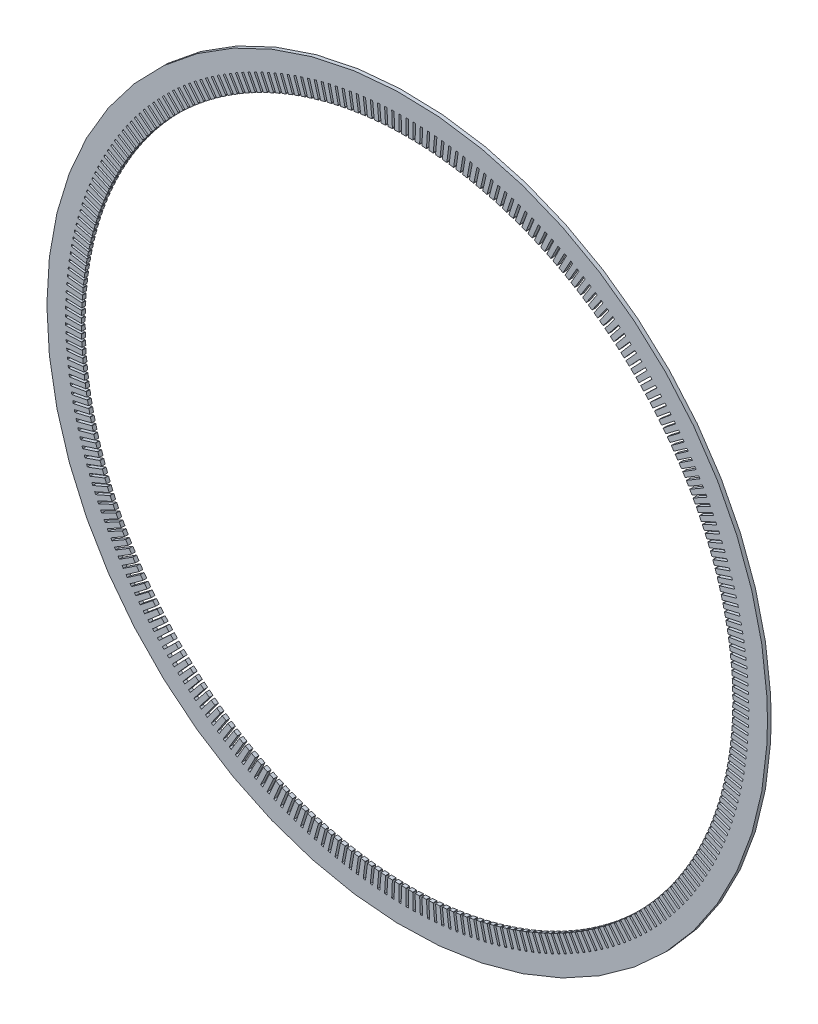
SolidWorks part; units mm, degrees
ref_plane "Front Plane" through (0, 0, 0) normal (0, 0, 1) x (1, 0, 0)
ref_plane "Top Plane" through (0, 0, 0) normal (0, 1, 0) x (1, 0, 0)
ref_plane "Right Plane" through (0, 0, 0) normal (1, 0, 0) x (0, 0, -1)
sketch "Sketch1" plane through (0, 0, 0) normal (0, 0, 1) x (1, 0, 0)
  line L0 (0, 0) -> (0, 6501.561) construction
  line L1 (-11, 3098.7805) -> (-11, 3101.7805)
  line L2 (-11, 3250.7805) -> (11, 3250.7805)
  line L3 (11, 3250.7805) -> (11, 3104.7805)
  line L4 (11, 3104.7805) -> (13.5981, 3103.2805)
  line L5 (13.5981, 3103.2805) -> (11, 3101.7805)
  line L6 (11, 3101.7805) -> (11, 3098.7805)
  line L7 (-13.5981, 3103.2805) -> (-11, 3101.7805)
  line L8 (-11, 3104.7805) -> (-13.5981, 3103.2805)
  line L9 (-11, 3104.7805) -> (-11, 3250.7805)
  line L10 (53.8984, 3098.3312) -> (53.9612, 3101.3306)
  line L11 (57.0816, 3250.2979) -> (79.0768, 3249.8372)
  line L12 (79.0768, 3249.8372) -> (76.0192, 3103.8692)
  line L13 (76.0192, 3103.8692) -> (78.5853, 3102.3151)
  line L14 (78.5853, 3102.3151) -> (75.9564, 3100.8698)
  line L15 (75.9564, 3100.8698) -> (75.8935, 3097.8705)
  line L16 (51.3951, 3102.8847) -> (53.9612, 3101.3306)
  line L17 (54.024, 3104.3299) -> (51.3951, 3102.8847)
  line L18 (54.024, 3104.3299) -> (57.0816, 3250.2979)
  line L19 (118.7731, 3096.523) -> (118.8987, 3099.5203)
  line L20 (125.1382, 3248.3896) -> (147.1189, 3247.4684)
  line L21 (147.1189, 3247.4684) -> (141.0051, 3101.5964)
  line L22 (141.0051, 3101.5964) -> (143.538, 3099.9889)
  line L23 (143.538, 3099.9889) -> (140.8794, 3098.5991)
  line L24 (140.8794, 3098.5991) -> (140.7538, 3095.6017)
  line L25 (116.3658, 3101.1278) -> (118.8987, 3099.5203)
  line L26 (119.0244, 3102.5177) -> (116.3658, 3101.1278)
  line L27 (119.0244, 3102.5177) -> (125.1382, 3248.3896)
  line L28 (183.5957, 3093.3564) -> (183.7841, 3096.3505)
  line L29 (193.1399, 3245.0565) -> (215.0965, 3243.6751)
  line L30 (215.0965, 3243.6751) -> (205.9291, 3097.9632)
  line L31 (205.9291, 3097.9632) -> (208.4278, 3096.303)
  line L32 (208.4278, 3096.303) -> (205.7407, 3094.9691)
  line L33 (205.7407, 3094.9691) -> (205.5523, 3091.975)
  line L34 (181.2853, 3098.0107) -> (183.7841, 3096.3505)
  line L35 (183.9725, 3099.3446) -> (181.2853, 3098.0107)
  line L36 (183.9725, 3099.3446) -> (193.1399, 3245.0565)
  line L37 (248.3378, 3088.8331) -> (248.5889, 3091.8226)
  line L38 (261.0569, 3240.3) -> (282.9797, 3238.4591)
  line L39 (282.9797, 3238.4591) -> (270.7628, 3092.9711)
  line L40 (270.7628, 3092.9711) -> (273.2262, 3091.259)
  line L41 (273.2262, 3091.259) -> (270.5117, 3089.9816)
  line L42 (270.5117, 3089.9816) -> (270.2607, 3086.9922)
  line L43 (246.1254, 3093.5347) -> (248.5889, 3091.8226)
  line L44 (248.8399, 3094.812) -> (246.1254, 3093.5347)
  line L45 (248.8399, 3094.812) -> (261.0569, 3240.3)
  line L46 (312.971, 3082.9548) -> (313.2846, 3085.9384)
  line L47 (328.8593, 3234.1222) -> (350.7388, 3231.8225)
  line L48 (350.7388, 3231.8225) -> (335.4777, 3086.6224)
  line L49 (335.4777, 3086.6224) -> (337.9047, 3084.859)
  line L50 (337.9047, 3084.859) -> (335.1641, 3083.6388)
  line L51 (335.1641, 3083.6388) -> (334.8505, 3080.6552)
  line L52 (310.8576, 3087.7018) -> (313.2846, 3085.9384)
  line L53 (313.5982, 3088.922) -> (310.8576, 3087.7018)
  line L54 (313.5982, 3088.922) -> (328.8593, 3234.1222)
  line L55 (377.4669, 3075.7243) -> (377.8429, 3078.7007)
  line L56 (396.5176, 3226.5258) -> (418.3441, 3223.7684)
  line L57 (418.3441, 3223.7684) -> (400.0454, 3078.9197)
  line L58 (400.0454, 3078.9197) -> (402.435, 3077.1059)
  line L59 (402.435, 3077.1059) -> (399.6694, 3075.9433)
  line L60 (399.6694, 3075.9433) -> (399.2934, 3072.967)
  line L61 (375.4533, 3080.5145) -> (377.8429, 3078.7007)
  line L62 (378.2189, 3081.677) -> (375.4533, 3080.5145)
  line L63 (378.2189, 3081.677) -> (396.5176, 3226.5258)
  line L64 (441.7972, 3067.1447) -> (442.2355, 3070.1125)
  line L65 (464.0019, 3217.5141) -> (485.7659, 3214.3003)
  line L66 (485.7659, 3214.3003) -> (464.4377, 3069.8665)
  line L67 (464.4377, 3069.8665) -> (466.7888, 3068.0031)
  line L68 (466.7888, 3068.0031) -> (463.9995, 3066.8987)
  line L69 (463.9995, 3066.8987) -> (463.5612, 3063.9309)
  line L70 (439.8844, 3071.976) -> (442.2355, 3070.1125)
  line L71 (442.6737, 3073.0803) -> (439.8844, 3071.976)
  line L72 (442.6737, 3073.0803) -> (464.0019, 3217.5141)
  line L73 (505.9338, 3057.2197) -> (506.4341, 3060.1777)
  line L74 (531.2826, 3207.0911) -> (552.9745, 3203.4222)
  line L75 (552.9745, 3203.4222) -> (528.6263, 3059.4668)
  line L76 (528.6263, 3059.4668) -> (530.9378, 3057.5545)
  line L77 (530.9378, 3057.5545) -> (528.126, 3056.5088)
  line L78 (528.126, 3056.5088) -> (527.6257, 3053.5508)
  line L79 (504.1225, 3062.09) -> (506.4341, 3060.1777)
  line L80 (506.9344, 3063.1357) -> (504.1225, 3062.09)
  line L81 (506.9344, 3063.1357) -> (531.2826, 3207.0911)
  line L82 (569.8484, 3045.9537) -> (570.4105, 3048.9006)
  line L83 (598.3304, 3195.2614) -> (619.9407, 3191.139)
  line L84 (619.9407, 3191.139) -> (592.583, 3047.7251)
  line L85 (592.583, 3047.7251) -> (594.854, 3045.7648)
  line L86 (594.854, 3045.7648) -> (592.0209, 3044.7782)
  line L87 (592.0209, 3044.7782) -> (591.4587, 3041.8314)
  line L88 (568.1396, 3050.8609) -> (570.4105, 3048.9006)
  line L89 (570.9727, 3051.8475) -> (568.1396, 3050.8609)
  line L90 (570.9727, 3051.8475) -> (598.3304, 3195.2614)
  line L91 (633.5131, 3033.3517) -> (634.1368, 3036.2862)
  line L92 (665.1156, 3182.0302) -> (686.6349, 3177.4561)
  line L93 (686.6349, 3177.4561) -> (656.2798, 3034.6465)
  line L94 (656.2798, 3034.6465) -> (658.5092, 3032.6392)
  line L95 (658.5092, 3032.6392) -> (655.656, 3031.7121)
  line L96 (655.656, 3031.7121) -> (655.0323, 3028.7777)
  line L97 (631.9074, 3038.2936) -> (634.1368, 3036.2862)
  line L98 (634.7605, 3039.2206) -> (631.9074, 3038.2936)
  line L99 (634.7605, 3039.2206) -> (665.1156, 3182.0302)
  line L100 (696.8999, 3019.4192) -> (697.5849, 3022.3399)
  line L101 (731.6092, 3167.4031) -> (753.0279, 3162.3794)
  line L102 (753.0279, 3162.3794) -> (719.6887, 3020.2369)
  line L103 (719.6887, 3020.2369) -> (721.8756, 3018.1833)
  line L104 (721.8756, 3018.1833) -> (719.0036, 3017.3162)
  line L105 (719.0036, 3017.3162) -> (718.3186, 3014.3954)
  line L106 (695.398, 3024.3935) -> (697.5849, 3022.3399)
  line L107 (698.27, 3025.2606) -> (695.398, 3024.3935)
  line L108 (698.27, 3025.2606) -> (731.6092, 3167.4031)
  line L109 (759.981, 3004.1622) -> (760.727, 3007.0679)
  line L110 (797.7818, 3151.3868) -> (819.0906, 3145.9156)
  line L111 (819.0906, 3145.9156) -> (782.7819, 3004.5025)
  line L112 (782.7819, 3004.5025) -> (784.9253, 3002.4035)
  line L113 (784.9253, 3002.4035) -> (782.0359, 3001.5968)
  line L114 (782.0359, 3001.5968) -> (781.2898, 2998.691)
  line L115 (758.5836, 3009.1669) -> (760.727, 3007.0679)
  line L116 (761.4731, 3009.9737) -> (758.5836, 3009.1669)
  line L117 (761.4731, 3009.9737) -> (797.7818, 3151.3868)
  line L118 (822.7287, 2987.5875) -> (823.5355, 2990.477)
  line L119 (863.6045, 3133.9882) -> (884.7941, 3128.0719)
  line L120 (884.7941, 3128.0719) -> (845.5318, 2987.4502)
  line L121 (845.5318, 2987.4502) -> (847.6308, 2985.3068)
  line L122 (847.6308, 2985.3068) -> (844.725, 2984.5607)
  line L123 (844.725, 2984.5607) -> (843.9183, 2981.6712)
  line L124 (821.4365, 2992.6204) -> (823.5355, 2990.477)
  line L125 (824.3422, 2993.3665) -> (821.4365, 2992.6204)
  line L126 (824.3422, 2993.3665) -> (863.6045, 3133.9882)
  line L127 (885.1156, 2969.7023) -> (885.9827, 2972.5743)
  line L128 (929.0484, 3115.2149) -> (950.1094, 3108.8562)
  line L129 (950.1094, 3108.8562) -> (907.9108, 2969.0875)
  line L130 (907.9108, 2969.0875) -> (909.9644, 2966.9006)
  line L131 (909.9644, 2966.9006) -> (907.0437, 2966.2156)
  line L132 (907.0437, 2966.2156) -> (906.1766, 2963.3436)
  line L133 (883.929, 2974.7612) -> (885.9827, 2972.5743)
  line L134 (886.8498, 2975.4462) -> (883.929, 2974.7612)
  line L135 (886.8498, 2975.4462) -> (929.0484, 3115.2149)
  line L136 (947.1142, 2950.5146) -> (948.0413, 2953.3677)
  line L137 (994.0848, 3095.0751) -> (1015.008, 3088.2768)
  line L138 (1015.008, 3088.2768) -> (969.8916, 2949.4225)
  line L139 (969.8916, 2949.4225) -> (971.8989, 2947.1931)
  line L140 (971.8989, 2947.1931) -> (968.9645, 2946.5693)
  line L141 (968.9645, 2946.5693) -> (968.0375, 2943.7162)
  line L142 (946.0339, 2955.5972) -> (948.0413, 2953.3677)
  line L143 (948.9683, 2956.2209) -> (946.0339, 2955.5972)
  line L144 (948.9683, 2956.2209) -> (994.0848, 3095.0751)
  line L145 (1008.6974, 2930.0326) -> (1009.684, 2932.8657)
  line L146 (1058.6851, 3073.5778) -> (1079.4614, 3066.3427)
  line L147 (1079.4614, 3066.3427) -> (1031.4469, 2928.4638)
  line L148 (1031.4469, 2928.4638) -> (1033.4071, 2926.1928)
  line L149 (1033.4071, 2926.1928) -> (1030.4603, 2925.6307)
  line L150 (1030.4603, 2925.6307) -> (1029.4737, 2922.7975)
  line L151 (1007.7237, 2935.1367) -> (1009.684, 2932.8657)
  line L152 (1010.6706, 2935.6988) -> (1007.7237, 2935.1367)
  line L153 (1010.6706, 2935.6988) -> (1058.6851, 3073.5778)
  line L154 (1069.8382, 2908.2654) -> (1070.8839, 2911.0773)
  line L155 (1122.8211, 3050.7323) -> (1143.4413, 3043.0637)
  line L156 (1143.4413, 3043.0637) -> (1092.5498, 2906.2205)
  line L157 (1092.5498, 2906.2205) -> (1094.4621, 2903.909)
  line L158 (1094.4621, 2903.909) -> (1091.5041, 2903.4087)
  line L159 (1091.5041, 2903.4087) -> (1090.4584, 2900.5968)
  line L160 (1068.9716, 2913.3888) -> (1070.8839, 2911.0773)
  line L161 (1071.9296, 2913.8891) -> (1068.9716, 2913.3888)
  line L162 (1071.9296, 2913.8891) -> (1122.8211, 3050.7323)
  line L163 (1130.5096, 2885.2226) -> (1131.614, 2888.0119)
  line L164 (1186.4646, 3026.5486) -> (1206.9197, 3018.4499)
  line L165 (1206.9197, 3018.4499) -> (1153.1735, 2882.7025)
  line L166 (1153.1735, 2882.7025) -> (1155.0369, 2880.3514)
  line L167 (1155.0369, 2880.3514) -> (1152.0691, 2879.9132)
  line L168 (1152.0691, 2879.9132) -> (1150.9647, 2877.1239)
  line L169 (1129.7506, 2890.363) -> (1131.614, 2888.0119)
  line L170 (1132.7184, 2890.8013) -> (1129.7506, 2890.363)
  line L171 (1132.7184, 2890.8013) -> (1186.4646, 3026.5486)
  line L172 (1190.6852, 2860.9142) -> (1191.8478, 2863.6798)
  line L173 (1249.5876, 3001.0374) -> (1269.8686, 2992.5121)
  line L174 (1269.8686, 2992.5121) -> (1213.2913, 2857.92)
  line L175 (1213.2913, 2857.92) -> (1215.1051, 2855.5305)
  line L176 (1215.1051, 2855.5305) -> (1212.1288, 2855.1545)
  line L177 (1212.1288, 2855.1545) -> (1210.9662, 2852.3889)
  line L178 (1190.034, 2866.0694) -> (1191.8478, 2863.6798)
  line L179 (1193.0103, 2866.4454) -> (1190.034, 2866.0694)
  line L180 (1193.0103, 2866.4454) -> (1249.5876, 3001.0374)
  line L181 (1250.3386, 2835.3509) -> (1251.5588, 2838.0916)
  line L182 (1312.1625, 2974.2098) -> (1332.2605, 2965.2616)
  line L183 (1332.2605, 2965.2616) -> (1272.877, 2831.884)
  line L184 (1272.877, 2831.884) -> (1274.6403, 2829.4569)
  line L185 (1274.6403, 2829.4569) -> (1271.6568, 2829.1434)
  line L186 (1271.6568, 2829.1434) -> (1270.4366, 2826.4027)
  line L187 (1249.7954, 2840.5186) -> (1251.5588, 2838.0916)
  line L188 (1252.779, 2840.8322) -> (1249.7954, 2840.5186)
  line L189 (1252.779, 2840.8322) -> (1312.1625, 2974.2098)
  line L190 (1309.4435, 2808.544) -> (1310.7208, 2811.2585)
  line L191 (1374.1619, 2946.0777) -> (1394.0681, 2936.7105)
  line L192 (1394.0681, 2936.7105) -> (1331.9043, 2804.6058)
  line L193 (1331.9043, 2804.6058) -> (1333.6165, 2802.1423)
  line L194 (1333.6165, 2802.1423) -> (1330.627, 2801.8913)
  line L195 (1330.627, 2801.8913) -> (1329.3497, 2799.1768)
  line L196 (1309.0087, 2813.7219) -> (1310.7208, 2811.2585)
  line L197 (1311.9981, 2813.9729) -> (1309.0087, 2813.7219)
  line L198 (1311.9981, 2813.9729) -> (1374.1619, 2946.0777)
  line L199 (1367.974, 2780.5051) -> (1369.3079, 2783.1922)
  line L200 (1435.5585, 2916.6533) -> (1455.2642, 2906.8713)
  line L201 (1455.2642, 2906.8713) -> (1390.3475, 2776.0974)
  line L202 (1390.3475, 2776.0974) -> (1392.0076, 2773.5986)
  line L203 (1392.0076, 2773.5986) -> (1389.0135, 2773.4103)
  line L204 (1389.0135, 2773.4103) -> (1387.6796, 2770.7231)
  line L205 (1367.6477, 2785.691) -> (1369.3079, 2783.1922)
  line L206 (1370.6418, 2785.8794) -> (1367.6477, 2785.691)
  line L207 (1370.6418, 2785.8794) -> (1435.5585, 2916.6533)
  line L208 (1425.9045, 2751.2466) -> (1427.2944, 2753.9052)
  line L209 (1496.3255, 2885.9495) -> (1515.8219, 2875.757)
  line L210 (1515.8219, 2875.757) -> (1448.1807, 2746.3713)
  line L211 (1448.1807, 2746.3713) -> (1449.7882, 2743.8383)
  line L212 (1449.7882, 2743.8383) -> (1446.7908, 2743.7127)
  line L213 (1446.7908, 2743.7127) -> (1445.4009, 2741.0541)
  line L214 (1425.6869, 2756.4382) -> (1427.2944, 2753.9052)
  line L215 (1428.6842, 2756.5638) -> (1425.6869, 2756.4382)
  line L216 (1428.6842, 2756.5638) -> (1496.3255, 2885.9495)
  line L217 (1483.2095, 2720.7813) -> (1484.6548, 2723.4102)
  line L218 (1556.4361, 2853.9799) -> (1575.7148, 2843.3814)
  line L219 (1575.7148, 2843.3814) -> (1505.3788, 2715.4406)
  line L220 (1505.3788, 2715.4406) -> (1506.9329, 2712.8745)
  line L221 (1506.9329, 2712.8745) -> (1503.9335, 2712.8117)
  line L222 (1503.9335, 2712.8117) -> (1502.4883, 2710.1827)
  line L223 (1483.1007, 2725.9763) -> (1484.6548, 2723.4102)
  line L224 (1486.1, 2726.0392) -> (1483.1007, 2725.9763)
  line L225 (1486.1, 2726.0392) -> (1556.4361, 2853.9799)
  line L226 (1539.864, 2689.1226) -> (1541.364, 2691.7207)
  line L227 (1615.864, 2820.7585) -> (1634.9165, 2809.7585)
  line L228 (1634.9165, 2809.7585) -> (1561.9165, 2683.3188)
  line L229 (1561.9165, 2683.3188) -> (1563.4165, 2680.7207)
  line L230 (1563.4165, 2680.7207) -> (1560.4165, 2680.7207)
  line L231 (1560.4165, 2680.7207) -> (1558.9165, 2678.1226)
  line L232 (1539.864, 2694.3188) -> (1541.364, 2691.7207)
  line L233 (1542.864, 2694.3188) -> (1539.864, 2694.3188)
  line L234 (1542.864, 2694.3188) -> (1615.864, 2820.7585)
  line L235 (1595.843, 2656.2844) -> (1597.3971, 2658.8505)
  line L236 (1674.5831, 2786.2997) -> (1693.4011, 2774.9031)
  line L237 (1693.4011, 2774.9031) -> (1617.7692, 2650.02)
  line L238 (1617.7692, 2650.02) -> (1619.2144, 2647.391)
  line L239 (1619.2144, 2647.391) -> (1616.2151, 2647.4539)
  line L240 (1616.2151, 2647.4539) -> (1614.661, 2644.8878)
  line L241 (1595.9518, 2661.4794) -> (1597.3971, 2658.8505)
  line L242 (1598.9511, 2661.4166) -> (1595.9518, 2661.4794)
  line L243 (1598.9511, 2661.4166) -> (1674.5831, 2786.2997)
  line L244 (1651.122, 2622.281) -> (1652.7295, 2624.814)
  line L245 (1732.5677, 2750.6188) -> (1751.1429, 2738.8306)
  line L246 (1751.1429, 2738.8306) -> (1672.9122, 2615.5588)
  line L247 (1672.9122, 2615.5588) -> (1674.3021, 2612.9002)
  line L248 (1674.3021, 2612.9002) -> (1671.3047, 2613.0258)
  line L249 (1671.3047, 2613.0258) -> (1669.6972, 2610.4928)
  line L250 (1651.3396, 2627.4726) -> (1652.7295, 2624.814)
  line L251 (1654.337, 2627.347) -> (1651.3396, 2627.4726)
  line L252 (1654.337, 2627.347) -> (1732.5677, 2750.6188)
  line L253 (1705.6768, 2587.1274) -> (1707.337, 2589.6261)
  line L254 (1789.7923, 2713.7314) -> (1808.1166, 2701.5568)
  line L255 (1808.1166, 2701.5568) -> (1727.3214, 2579.9503)
  line L256 (1727.3214, 2579.9503) -> (1728.6553, 2577.2632)
  line L257 (1728.6553, 2577.2632) -> (1725.6612, 2577.4515)
  line L258 (1725.6612, 2577.4515) -> (1724.0011, 2574.9528)
  line L259 (1706.0031, 2592.3133) -> (1707.337, 2589.6261)
  line L260 (1708.9971, 2592.1249) -> (1706.0031, 2592.3133)
  line L261 (1708.9971, 2592.1249) -> (1789.7923, 2713.7314)
  line L262 (1759.4834, 2550.839) -> (1761.1956, 2553.3024)
  line L263 (1846.2319, 2675.6537) -> (1864.2972, 2663.098)
  line L264 (1864.2972, 2663.098) -> (1780.973, 2543.2102)
  line L265 (1780.973, 2543.2102) -> (1782.2503, 2540.4957)
  line L266 (1782.2503, 2540.4957) -> (1779.2608, 2540.7467)
  line L267 (1779.2608, 2540.7467) -> (1777.5487, 2538.2833)
  line L268 (1759.9182, 2556.0169) -> (1761.1956, 2553.3024)
  line L269 (1762.9077, 2555.7659) -> (1759.9182, 2556.0169)
  line L270 (1762.9077, 2555.7659) -> (1846.2319, 2675.6537)
  line L271 (1812.5183, 2513.4317) -> (1814.2816, 2515.8588)
  line L272 (1901.8616, 2636.4023) -> (1919.66, 2623.471)
  line L273 (1919.66, 2623.471) -> (1833.8434, 2505.3545)
  line L274 (1833.8434, 2505.3545) -> (1835.0636, 2502.6139)
  line L275 (1835.0636, 2502.6139) -> (1832.08, 2502.9275)
  line L276 (1832.08, 2502.9275) -> (1830.3167, 2500.5004)
  line L277 (1813.0614, 2518.5994) -> (1814.2816, 2515.8588)
  line L278 (1816.045, 2518.2858) -> (1813.0614, 2518.5994)
  line L279 (1816.045, 2518.2858) -> (1901.8616, 2636.4023)
  line L280 (1864.7581, 2474.9219) -> (1866.5719, 2477.3115)
  line L281 (1956.6572, 2595.9945) -> (1974.1808, 2582.6933)
  line L282 (1974.1808, 2582.6933) -> (1885.9094, 2466.3999)
  line L283 (1885.9094, 2466.3999) -> (1887.0719, 2463.6344)
  line L284 (1887.0719, 2463.6344) -> (1884.0956, 2464.0104)
  line L285 (1884.0956, 2464.0104) -> (1882.2818, 2461.6208)
  line L286 (1865.4094, 2480.0771) -> (1866.5719, 2477.3115)
  line L287 (1868.3857, 2479.7011) -> (1865.4094, 2480.0771)
  line L288 (1868.3857, 2479.7011) -> (1956.6572, 2595.9945)
  line L289 (1916.18, 2435.3266) -> (1918.0434, 2437.6777)
  line L290 (2010.5944, 2554.448) -> (2027.8357, 2540.7828)
  line L291 (2027.8357, 2540.7828) -> (1937.1481, 2426.3635)
  line L292 (1937.1481, 2426.3635) -> (1938.2525, 2423.5742)
  line L293 (1938.2525, 2423.5742) -> (1935.2847, 2424.0124)
  line L294 (1935.2847, 2424.0124) -> (1933.4212, 2421.6614)
  line L295 (1916.9391, 2440.467) -> (1918.0434, 2437.6777)
  line L296 (1919.9069, 2440.0288) -> (1916.9391, 2440.467)
  line L297 (1919.9069, 2440.0288) -> (2010.5944, 2554.448)
  line L298 (1966.7614, 2394.6631) -> (1968.6736, 2396.9746)
  line L299 (2063.6498, 2511.7811) -> (2080.6011, 2497.7577)
  line L300 (2080.6011, 2497.7577) -> (1987.5372, 2385.2628)
  line L301 (1987.5372, 2385.2628) -> (1988.5829, 2382.451)
  line L302 (1988.5829, 2382.451) -> (1985.6249, 2382.9513)
  line L303 (1985.6249, 2382.9513) -> (1983.7127, 2380.6397)
  line L304 (1967.6279, 2399.7864) -> (1968.6736, 2396.9746)
  line L305 (1970.5859, 2399.2861) -> (1967.6279, 2399.7864)
  line L306 (1970.5859, 2399.2861) -> (2063.6498, 2511.7811)
  line L307 (2016.4801, 2352.9491) -> (2018.4403, 2355.2201)
  line L308 (2115.8, 2468.0124) -> (2132.4539, 2453.6371)
  line L309 (2132.4539, 2453.6371) -> (2037.0545, 2343.1158)
  line L310 (2037.0545, 2343.1158) -> (2038.0411, 2340.2827)
  line L311 (2038.0411, 2340.2827) -> (2035.0942, 2340.8449)
  line L312 (2035.0942, 2340.8449) -> (2033.134, 2338.5739)
  line L313 (2017.4537, 2358.0532) -> (2018.4403, 2355.2201)
  line L314 (2020.4006, 2357.4911) -> (2017.4537, 2358.0532)
  line L315 (2020.4006, 2357.4911) -> (2115.8, 2468.0124)
  line L316 (2065.3143, 2310.2031) -> (2067.3217, 2312.4325)
  line L317 (2167.0221, 2423.1611) -> (2183.3713, 2408.4403)
  line L318 (2183.3713, 2408.4403) -> (2085.6782, 2299.9411)
  line L319 (2085.6782, 2299.9411) -> (2086.6053, 2297.0879)
  line L320 (2086.6053, 2297.0879) -> (2083.6708, 2297.7117)
  line L321 (2083.6708, 2297.7117) -> (2081.6635, 2295.4822)
  line L322 (2066.3946, 2315.2857) -> (2067.3217, 2312.4325)
  line L323 (2069.329, 2314.662) -> (2066.3946, 2315.2857)
  line L324 (2069.329, 2314.662) -> (2167.0221, 2423.1611)
  line L325 (2113.2426, 2266.4438) -> (2115.2962, 2268.6307)
  line L326 (2217.2937, 2377.247) -> (2233.331, 2362.187)
  line L327 (2233.331, 2362.187) -> (2133.3871, 2255.7575)
  line L328 (2133.3871, 2255.7575) -> (2134.2542, 2252.8856)
  line L329 (2134.2542, 2252.8856) -> (2131.3335, 2253.5706)
  line L330 (2131.3335, 2253.5706) -> (2129.2799, 2251.3837)
  line L331 (2114.4291, 2271.5026) -> (2115.2962, 2268.6307)
  line L332 (2117.3498, 2270.8176) -> (2114.4291, 2271.5026)
  line L333 (2117.3498, 2270.8176) -> (2217.2937, 2377.247)
  line L334 (2160.2439, 2221.6903) -> (2162.3429, 2223.8337)
  line L335 (2266.5927, 2330.2901) -> (2282.3111, 2314.8975)
  line L336 (2282.3111, 2314.8975) -> (2180.1603, 2210.5845)
  line L337 (2180.1603, 2210.5845) -> (2180.967, 2207.695)
  line L338 (2180.967, 2207.695) -> (2178.0613, 2208.4411)
  line L339 (2178.0613, 2208.4411) -> (2175.9623, 2206.2977)
  line L340 (2161.5361, 2226.7232) -> (2162.3429, 2223.8337)
  line L341 (2164.4419, 2225.9771) -> (2161.5361, 2226.7232)
  line L342 (2164.4419, 2225.9771) -> (2266.5927, 2330.2901)
  line L343 (2206.2977, 2175.9623) -> (2208.4411, 2178.0613)
  line L344 (2314.8975, 2282.3111) -> (2330.2901, 2266.5927)
  line L345 (2330.2901, 2266.5927) -> (2225.9771, 2164.4419)
  line L346 (2225.9771, 2164.4419) -> (2226.7232, 2161.5361)
  line L347 (2226.7232, 2161.5361) -> (2223.8337, 2162.3429)
  line L348 (2223.8337, 2162.3429) -> (2221.6903, 2160.2439)
  line L349 (2207.695, 2180.967) -> (2208.4411, 2178.0613)
  line L350 (2210.5845, 2180.1603) -> (2207.695, 2180.967)
  line L351 (2210.5845, 2180.1603) -> (2314.8975, 2282.3111)
  line L352 (2251.3837, 2129.2799) -> (2253.5706, 2131.3335)
  line L353 (2362.187, 2233.331) -> (2377.247, 2217.2937)
  line L354 (2377.247, 2217.2937) -> (2270.8176, 2117.3498)
  line L355 (2270.8176, 2117.3498) -> (2271.5026, 2114.4291)
  line L356 (2271.5026, 2114.4291) -> (2268.6307, 2115.2962)
  line L357 (2268.6307, 2115.2962) -> (2266.4438, 2113.2426)
  line L358 (2252.8856, 2134.2542) -> (2253.5706, 2131.3335)
  line L359 (2255.7575, 2133.3871) -> (2252.8856, 2134.2542)
  line L360 (2255.7575, 2133.3871) -> (2362.187, 2233.331)
  line L361 (2295.4822, 2081.6635) -> (2297.7117, 2083.6708)
  line L362 (2408.4403, 2183.3713) -> (2423.1611, 2167.0221)
  line L363 (2423.1611, 2167.0221) -> (2314.662, 2069.329)
  line L364 (2314.662, 2069.329) -> (2315.2857, 2066.3946)
  line L365 (2315.2857, 2066.3946) -> (2312.4325, 2067.3217)
  line L366 (2312.4325, 2067.3217) -> (2310.2031, 2065.3143)
  line L367 (2297.0879, 2086.6053) -> (2297.7117, 2083.6708)
  line L368 (2299.9411, 2085.6782) -> (2297.0879, 2086.6053)
  line L369 (2299.9411, 2085.6782) -> (2408.4403, 2183.3713)
  line L370 (2338.5739, 2033.134) -> (2340.8449, 2035.0942)
  line L371 (2453.6371, 2132.4539) -> (2468.0124, 2115.8)
  line L372 (2468.0124, 2115.8) -> (2357.4911, 2020.4006)
  line L373 (2357.4911, 2020.4006) -> (2358.0532, 2017.4537)
  line L374 (2358.0532, 2017.4537) -> (2355.2201, 2018.4403)
  line L375 (2355.2201, 2018.4403) -> (2352.9491, 2016.4801)
  line L376 (2340.2827, 2038.0411) -> (2340.8449, 2035.0942)
  line L377 (2343.1158, 2037.0545) -> (2340.2827, 2038.0411)
  line L378 (2343.1158, 2037.0545) -> (2453.6371, 2132.4539)
  line L379 (2380.6397, 1983.7127) -> (2382.9513, 1985.6249)
  line L380 (2497.7577, 2080.6011) -> (2511.7811, 2063.6498)
  line L381 (2511.7811, 2063.6498) -> (2399.2861, 1970.5859)
  line L382 (2399.2861, 1970.5859) -> (2399.7864, 1967.6279)
  line L383 (2399.7864, 1967.6279) -> (2396.9746, 1968.6736)
  line L384 (2396.9746, 1968.6736) -> (2394.6631, 1966.7614)
  line L385 (2382.451, 1988.5829) -> (2382.9513, 1985.6249)
  line L386 (2385.2628, 1987.5372) -> (2382.451, 1988.5829)
  line L387 (2385.2628, 1987.5372) -> (2497.7577, 2080.6011)
  line L388 (2421.6614, 1933.4212) -> (2424.0124, 1935.2847)
  line L389 (2540.7828, 2027.8357) -> (2554.448, 2010.5944)
  line L390 (2554.448, 2010.5944) -> (2440.0288, 1919.9069)
  line L391 (2440.0288, 1919.9069) -> (2440.467, 1916.9391)
  line L392 (2440.467, 1916.9391) -> (2437.6777, 1918.0434)
  line L393 (2437.6777, 1918.0434) -> (2435.3266, 1916.18)
  line L394 (2423.5742, 1938.2525) -> (2424.0124, 1935.2847)
  line L395 (2426.3635, 1937.1481) -> (2423.5742, 1938.2525)
  line L396 (2426.3635, 1937.1481) -> (2540.7828, 2027.8357)
  line L397 (2461.6208, 1882.2818) -> (2464.0104, 1884.0956)
  line L398 (2582.6933, 1974.1808) -> (2595.9945, 1956.6572)
  line L399 (2595.9945, 1956.6572) -> (2479.7011, 1868.3857)
  line L400 (2479.7011, 1868.3857) -> (2480.0771, 1865.4094)
  line L401 (2480.0771, 1865.4094) -> (2477.3115, 1866.5719)
  line L402 (2477.3115, 1866.5719) -> (2474.9219, 1864.7581)
  line L403 (2463.6344, 1887.0719) -> (2464.0104, 1884.0956)
  line L404 (2466.3999, 1885.9094) -> (2463.6344, 1887.0719)
  line L405 (2466.3999, 1885.9094) -> (2582.6933, 1974.1808)
  line L406 (2500.5004, 1830.3167) -> (2502.9275, 1832.08)
  line L407 (2623.471, 1919.66) -> (2636.4023, 1901.8616)
  line L408 (2636.4023, 1901.8616) -> (2518.2858, 1816.045)
  line L409 (2518.2858, 1816.045) -> (2518.5994, 1813.0614)
  line L410 (2518.5994, 1813.0614) -> (2515.8588, 1814.2816)
  line L411 (2515.8588, 1814.2816) -> (2513.4317, 1812.5183)
  line L412 (2502.6139, 1835.0636) -> (2502.9275, 1832.08)
  line L413 (2505.3545, 1833.8434) -> (2502.6139, 1835.0636)
  line L414 (2505.3545, 1833.8434) -> (2623.471, 1919.66)
  line L415 (2538.2833, 1777.5487) -> (2540.7467, 1779.2608)
  line L416 (2663.098, 1864.2972) -> (2675.6537, 1846.2319)
  line L417 (2675.6537, 1846.2319) -> (2555.7659, 1762.9077)
  line L418 (2555.7659, 1762.9077) -> (2556.0169, 1759.9182)
  line L419 (2556.0169, 1759.9182) -> (2553.3024, 1761.1956)
  line L420 (2553.3024, 1761.1956) -> (2550.839, 1759.4834)
  line L421 (2540.4957, 1782.2503) -> (2540.7467, 1779.2608)
  line L422 (2543.2102, 1780.973) -> (2540.4957, 1782.2503)
  line L423 (2543.2102, 1780.973) -> (2663.098, 1864.2972)
  line L424 (2574.9528, 1724.0011) -> (2577.4515, 1725.6612)
  line L425 (2701.5568, 1808.1166) -> (2713.7314, 1789.7923)
  line L426 (2713.7314, 1789.7923) -> (2592.1249, 1708.9971)
  line L427 (2592.1249, 1708.9971) -> (2592.3133, 1706.0031)
  line L428 (2592.3133, 1706.0031) -> (2589.6261, 1707.337)
  line L429 (2589.6261, 1707.337) -> (2587.1274, 1705.6768)
  line L430 (2577.2632, 1728.6553) -> (2577.4515, 1725.6612)
  line L431 (2579.9503, 1727.3214) -> (2577.2632, 1728.6553)
  line L432 (2579.9503, 1727.3214) -> (2701.5568, 1808.1166)
  line L433 (2610.4928, 1669.6972) -> (2613.0258, 1671.3047)
  line L434 (2738.8306, 1751.1429) -> (2750.6188, 1732.5677)
  line L435 (2750.6188, 1732.5677) -> (2627.347, 1654.337)
  line L436 (2627.347, 1654.337) -> (2627.4726, 1651.3396)
  line L437 (2627.4726, 1651.3396) -> (2624.814, 1652.7295)
  line L438 (2624.814, 1652.7295) -> (2622.281, 1651.122)
  line L439 (2612.9002, 1674.3021) -> (2613.0258, 1671.3047)
  line L440 (2615.5588, 1672.9122) -> (2612.9002, 1674.3021)
  line L441 (2615.5588, 1672.9122) -> (2738.8306, 1751.1429)
  line L442 (2644.8878, 1614.661) -> (2647.4539, 1616.2151)
  line L443 (2774.9031, 1693.4011) -> (2786.2997, 1674.5831)
  line L444 (2786.2997, 1674.5831) -> (2661.4166, 1598.9511)
  line L445 (2661.4166, 1598.9511) -> (2661.4794, 1595.9518)
  line L446 (2661.4794, 1595.9518) -> (2658.8505, 1597.3971)
  line L447 (2658.8505, 1597.3971) -> (2656.2844, 1595.843)
  line L448 (2647.391, 1619.2144) -> (2647.4539, 1616.2151)
  line L449 (2650.02, 1617.7692) -> (2647.391, 1619.2144)
  line L450 (2650.02, 1617.7692) -> (2774.9031, 1693.4011)
  line L451 (2678.1226, 1558.9165) -> (2680.7207, 1560.4165)
  line L452 (2809.7585, 1634.9165) -> (2820.7585, 1615.864)
  line L453 (2820.7585, 1615.864) -> (2694.3188, 1542.864)
  line L454 (2694.3188, 1542.864) -> (2694.3188, 1539.864)
  line L455 (2694.3188, 1539.864) -> (2691.7207, 1541.364)
  line L456 (2691.7207, 1541.364) -> (2689.1226, 1539.864)
  line L457 (2680.7207, 1563.4165) -> (2680.7207, 1560.4165)
  line L458 (2683.3188, 1561.9165) -> (2680.7207, 1563.4165)
  line L459 (2683.3188, 1561.9165) -> (2809.7585, 1634.9165)
  line L460 (2710.1827, 1502.4883) -> (2712.8117, 1503.9335)
  line L461 (2843.3814, 1575.7148) -> (2853.9799, 1556.4361)
  line L462 (2853.9799, 1556.4361) -> (2726.0392, 1486.1)
  line L463 (2726.0392, 1486.1) -> (2725.9763, 1483.1007)
  line L464 (2725.9763, 1483.1007) -> (2723.4102, 1484.6548)
  line L465 (2723.4102, 1484.6548) -> (2720.7813, 1483.2095)
  line L466 (2712.8745, 1506.9329) -> (2712.8117, 1503.9335)
  line L467 (2715.4406, 1505.3788) -> (2712.8745, 1506.9329)
  line L468 (2715.4406, 1505.3788) -> (2843.3814, 1575.7148)
  line L469 (2741.0541, 1445.4009) -> (2743.7127, 1446.7908)
  line L470 (2875.757, 1515.8219) -> (2885.9495, 1496.3255)
  line L471 (2885.9495, 1496.3255) -> (2756.5638, 1428.6842)
  line L472 (2756.5638, 1428.6842) -> (2756.4382, 1425.6869)
  line L473 (2756.4382, 1425.6869) -> (2753.9052, 1427.2944)
  line L474 (2753.9052, 1427.2944) -> (2751.2466, 1425.9045)
  line L475 (2743.8383, 1449.7882) -> (2743.7127, 1446.7908)
  line L476 (2746.3713, 1448.1807) -> (2743.8383, 1449.7882)
  line L477 (2746.3713, 1448.1807) -> (2875.757, 1515.8219)
  line L478 (2770.7231, 1387.6796) -> (2773.4103, 1389.0135)
  line L479 (2906.8713, 1455.2642) -> (2916.6533, 1435.5585)
  line L480 (2916.6533, 1435.5585) -> (2785.8794, 1370.6418)
  line L481 (2785.8794, 1370.6418) -> (2785.691, 1367.6477)
  line L482 (2785.691, 1367.6477) -> (2783.1922, 1369.3079)
  line L483 (2783.1922, 1369.3079) -> (2780.5051, 1367.974)
  line L484 (2773.5986, 1392.0076) -> (2773.4103, 1389.0135)
  line L485 (2776.0974, 1390.3475) -> (2773.5986, 1392.0076)
  line L486 (2776.0974, 1390.3475) -> (2906.8713, 1455.2642)
  line L487 (2799.1768, 1329.3497) -> (2801.8913, 1330.627)
  line L488 (2936.7105, 1394.0681) -> (2946.0777, 1374.1619)
  line L489 (2946.0777, 1374.1619) -> (2813.9729, 1311.9981)
  line L490 (2813.9729, 1311.9981) -> (2813.7219, 1309.0087)
  line L491 (2813.7219, 1309.0087) -> (2811.2585, 1310.7208)
  line L492 (2811.2585, 1310.7208) -> (2808.544, 1309.4435)
  line L493 (2802.1423, 1333.6165) -> (2801.8913, 1330.627)
  line L494 (2804.6058, 1331.9043) -> (2802.1423, 1333.6165)
  line L495 (2804.6058, 1331.9043) -> (2936.7105, 1394.0681)
  line L496 (2826.4027, 1270.4366) -> (2829.1434, 1271.6568)
  line L497 (2965.2616, 1332.2605) -> (2974.2098, 1312.1625)
  line L498 (2974.2098, 1312.1625) -> (2840.8322, 1252.779)
  line L499 (2840.8322, 1252.779) -> (2840.5186, 1249.7954)
  line L500 (2840.5186, 1249.7954) -> (2838.0916, 1251.5588)
  line L501 (2838.0916, 1251.5588) -> (2835.3509, 1250.3386)
  line L502 (2829.4569, 1274.6403) -> (2829.1434, 1271.6568)
  line L503 (2831.884, 1272.877) -> (2829.4569, 1274.6403)
  line L504 (2831.884, 1272.877) -> (2965.2616, 1332.2605)
  line L505 (2852.3889, 1210.9662) -> (2855.1545, 1212.1288)
  line L506 (2992.5121, 1269.8686) -> (3001.0374, 1249.5876)
  line L507 (3001.0374, 1249.5876) -> (2866.4454, 1193.0103)
  line L508 (2866.4454, 1193.0103) -> (2866.0694, 1190.034)
  line L509 (2866.0694, 1190.034) -> (2863.6798, 1191.8478)
  line L510 (2863.6798, 1191.8478) -> (2860.9142, 1190.6852)
  line L511 (2855.5305, 1215.1051) -> (2855.1545, 1212.1288)
  line L512 (2857.92, 1213.2913) -> (2855.5305, 1215.1051)
  line L513 (2857.92, 1213.2913) -> (2992.5121, 1269.8686)
  line L514 (2877.1239, 1150.9647) -> (2879.9132, 1152.0691)
  line L515 (3018.4499, 1206.9197) -> (3026.5486, 1186.4646)
  line L516 (3026.5486, 1186.4646) -> (2890.8013, 1132.7184)
  line L517 (2890.8013, 1132.7184) -> (2890.363, 1129.7506)
  line L518 (2890.363, 1129.7506) -> (2888.0119, 1131.614)
  line L519 (2888.0119, 1131.614) -> (2885.2226, 1130.5096)
  line L520 (2880.3514, 1155.0369) -> (2879.9132, 1152.0691)
  line L521 (2882.7025, 1153.1735) -> (2880.3514, 1155.0369)
  line L522 (2882.7025, 1153.1735) -> (3018.4499, 1206.9197)
  line L523 (2900.5968, 1090.4584) -> (2903.4087, 1091.5041)
  line L524 (3043.0637, 1143.4413) -> (3050.7323, 1122.8211)
  line L525 (3050.7323, 1122.8211) -> (2913.8891, 1071.9296)
  line L526 (2913.8891, 1071.9296) -> (2913.3888, 1068.9716)
  line L527 (2913.3888, 1068.9716) -> (2911.0773, 1070.8839)
  line L528 (2911.0773, 1070.8839) -> (2908.2654, 1069.8382)
  line L529 (2903.909, 1094.4621) -> (2903.4087, 1091.5041)
  line L530 (2906.2205, 1092.5498) -> (2903.909, 1094.4621)
  line L531 (2906.2205, 1092.5498) -> (3043.0637, 1143.4413)
  line L532 (2922.7975, 1029.4737) -> (2925.6307, 1030.4603)
  line L533 (3066.3427, 1079.4614) -> (3073.5778, 1058.6851)
  line L534 (3073.5778, 1058.6851) -> (2935.6988, 1010.6706)
  line L535 (2935.6988, 1010.6706) -> (2935.1367, 1007.7237)
  line L536 (2935.1367, 1007.7237) -> (2932.8657, 1009.684)
  line L537 (2932.8657, 1009.684) -> (2930.0326, 1008.6974)
  line L538 (2926.1928, 1033.4071) -> (2925.6307, 1030.4603)
  line L539 (2928.4638, 1031.4469) -> (2926.1928, 1033.4071)
  line L540 (2928.4638, 1031.4469) -> (3066.3427, 1079.4614)
  line L541 (2943.7162, 968.0375) -> (2946.5693, 968.9645)
  line L542 (3088.2768, 1015.008) -> (3095.0751, 994.0848)
  line L543 (3095.0751, 994.0848) -> (2956.2209, 948.9683)
  line L544 (2956.2209, 948.9683) -> (2955.5972, 946.0339)
  line L545 (2955.5972, 946.0339) -> (2953.3677, 948.0413)
  line L546 (2953.3677, 948.0413) -> (2950.5146, 947.1142)
  line L547 (2947.1931, 971.8989) -> (2946.5693, 968.9645)
  line L548 (2949.4225, 969.8916) -> (2947.1931, 971.8989)
  line L549 (2949.4225, 969.8916) -> (3088.2768, 1015.008)
  line L550 (2963.3436, 906.1766) -> (2966.2156, 907.0437)
  line L551 (3108.8562, 950.1094) -> (3115.2149, 929.0484)
  line L552 (3115.2149, 929.0484) -> (2975.4462, 886.8498)
  line L553 (2975.4462, 886.8498) -> (2974.7612, 883.929)
  line L554 (2974.7612, 883.929) -> (2972.5743, 885.9827)
  line L555 (2972.5743, 885.9827) -> (2969.7023, 885.1156)
  line L556 (2966.9006, 909.9644) -> (2966.2156, 907.0437)
  line L557 (2969.0875, 907.9108) -> (2966.9006, 909.9644)
  line L558 (2969.0875, 907.9108) -> (3108.8562, 950.1094)
  line L559 (2981.6712, 843.9183) -> (2984.5607, 844.725)
  line L560 (3128.0719, 884.7941) -> (3133.9882, 863.6045)
  line L561 (3133.9882, 863.6045) -> (2993.3665, 824.3422)
  line L562 (2993.3665, 824.3422) -> (2992.6204, 821.4365)
  line L563 (2992.6204, 821.4365) -> (2990.477, 823.5355)
  line L564 (2990.477, 823.5355) -> (2987.5875, 822.7287)
  line L565 (2985.3068, 847.6308) -> (2984.5607, 844.725)
  line L566 (2987.4502, 845.5318) -> (2985.3068, 847.6308)
  line L567 (2987.4502, 845.5318) -> (3128.0719, 884.7941)
  line L568 (2998.691, 781.2898) -> (3001.5968, 782.0359)
  line L569 (3145.9156, 819.0906) -> (3151.3868, 797.7818)
  line L570 (3151.3868, 797.7818) -> (3009.9737, 761.4731)
  line L571 (3009.9737, 761.4731) -> (3009.1669, 758.5836)
  line L572 (3009.1669, 758.5836) -> (3007.0679, 760.727)
  line L573 (3007.0679, 760.727) -> (3004.1622, 759.981)
  line L574 (3002.4035, 784.9253) -> (3001.5968, 782.0359)
  line L575 (3004.5025, 782.7819) -> (3002.4035, 784.9253)
  line L576 (3004.5025, 782.7819) -> (3145.9156, 819.0906)
  line L577 (3014.3954, 718.3186) -> (3017.3162, 719.0036)
  line L578 (3162.3794, 753.0279) -> (3167.4031, 731.6092)
  line L579 (3167.4031, 731.6092) -> (3025.2606, 698.27)
  line L580 (3025.2606, 698.27) -> (3024.3935, 695.398)
  line L581 (3024.3935, 695.398) -> (3022.3399, 697.5849)
  line L582 (3022.3399, 697.5849) -> (3019.4192, 696.8999)
  line L583 (3018.1833, 721.8756) -> (3017.3162, 719.0036)
  line L584 (3020.2369, 719.6887) -> (3018.1833, 721.8756)
  line L585 (3020.2369, 719.6887) -> (3162.3794, 753.0279)
  line L586 (3028.7777, 655.0323) -> (3031.7121, 655.656)
  line L587 (3177.4561, 686.6349) -> (3182.0302, 665.1156)
  line L588 (3182.0302, 665.1156) -> (3039.2206, 634.7605)
  line L589 (3039.2206, 634.7605) -> (3038.2936, 631.9074)
  line L590 (3038.2936, 631.9074) -> (3036.2862, 634.1368)
  line L591 (3036.2862, 634.1368) -> (3033.3517, 633.5131)
  line L592 (3032.6392, 658.5092) -> (3031.7121, 655.656)
  line L593 (3034.6465, 656.2798) -> (3032.6392, 658.5092)
  line L594 (3034.6465, 656.2798) -> (3177.4561, 686.6349)
  line L595 (3041.8314, 591.4587) -> (3044.7782, 592.0209)
  line L596 (3191.139, 619.9407) -> (3195.2614, 598.3304)
  line L597 (3195.2614, 598.3304) -> (3051.8475, 570.9727)
  line L598 (3051.8475, 570.9727) -> (3050.8609, 568.1396)
  line L599 (3050.8609, 568.1396) -> (3048.9006, 570.4105)
  line L600 (3048.9006, 570.4105) -> (3045.9537, 569.8484)
  line L601 (3045.7648, 594.854) -> (3044.7782, 592.0209)
  line L602 (3047.7251, 592.583) -> (3045.7648, 594.854)
  line L603 (3047.7251, 592.583) -> (3191.139, 619.9407)
  line L604 (3053.5508, 527.6257) -> (3056.5088, 528.126)
  line L605 (3203.4222, 552.9745) -> (3207.0911, 531.2826)
  line L606 (3207.0911, 531.2826) -> (3063.1357, 506.9344)
  line L607 (3063.1357, 506.9344) -> (3062.09, 504.1225)
  line L608 (3062.09, 504.1225) -> (3060.1777, 506.4341)
  line L609 (3060.1777, 506.4341) -> (3057.2197, 505.9338)
  line L610 (3057.5545, 530.9378) -> (3056.5088, 528.126)
  line L611 (3059.4668, 528.6263) -> (3057.5545, 530.9378)
  line L612 (3059.4668, 528.6263) -> (3203.4222, 552.9745)
  line L613 (3063.9309, 463.5612) -> (3066.8987, 463.9995)
  line L614 (3214.3003, 485.7659) -> (3217.5141, 464.0019)
  line L615 (3217.5141, 464.0019) -> (3073.0803, 442.6737)
  line L616 (3073.0803, 442.6737) -> (3071.976, 439.8844)
  line L617 (3071.976, 439.8844) -> (3070.1125, 442.2355)
  line L618 (3070.1125, 442.2355) -> (3067.1447, 441.7972)
  line L619 (3068.0031, 466.7888) -> (3066.8987, 463.9995)
  line L620 (3069.8665, 464.4377) -> (3068.0031, 466.7888)
  line L621 (3069.8665, 464.4377) -> (3214.3003, 485.7659)
  line L622 (3072.967, 399.2934) -> (3075.9433, 399.6694)
  line L623 (3223.7684, 418.3441) -> (3226.5258, 396.5176)
  line L624 (3226.5258, 396.5176) -> (3081.677, 378.2189)
  line L625 (3081.677, 378.2189) -> (3080.5145, 375.4533)
  line L626 (3080.5145, 375.4533) -> (3078.7007, 377.8429)
  line L627 (3078.7007, 377.8429) -> (3075.7243, 377.4669)
  line L628 (3077.1059, 402.435) -> (3075.9433, 399.6694)
  line L629 (3078.9197, 400.0454) -> (3077.1059, 402.435)
  line L630 (3078.9197, 400.0454) -> (3223.7684, 418.3441)
  line L631 (3080.6552, 334.8505) -> (3083.6388, 335.1641)
  line L632 (3231.8225, 350.7388) -> (3234.1222, 328.8593)
  line L633 (3234.1222, 328.8593) -> (3088.922, 313.5982)
  line L634 (3088.922, 313.5982) -> (3087.7018, 310.8576)
  line L635 (3087.7018, 310.8576) -> (3085.9384, 313.2846)
  line L636 (3085.9384, 313.2846) -> (3082.9548, 312.971)
  line L637 (3084.859, 337.9047) -> (3083.6388, 335.1641)
  line L638 (3086.6224, 335.4777) -> (3084.859, 337.9047)
  line L639 (3086.6224, 335.4777) -> (3231.8225, 350.7388)
  line L640 (3086.9922, 270.2607) -> (3089.9816, 270.5117)
  line L641 (3238.4591, 282.9797) -> (3240.3, 261.0569)
  line L642 (3240.3, 261.0569) -> (3094.812, 248.8399)
  line L643 (3094.812, 248.8399) -> (3093.5347, 246.1254)
  line L644 (3093.5347, 246.1254) -> (3091.8226, 248.5889)
  line L645 (3091.8226, 248.5889) -> (3088.8331, 248.3378)
  line L646 (3091.259, 273.2262) -> (3089.9816, 270.5117)
  line L647 (3092.9711, 270.7628) -> (3091.259, 273.2262)
  line L648 (3092.9711, 270.7628) -> (3238.4591, 282.9797)
  line L649 (3091.975, 205.5523) -> (3094.9691, 205.7407)
  line L650 (3243.6751, 215.0965) -> (3245.0565, 193.1399)
  line L651 (3245.0565, 193.1399) -> (3099.3446, 183.9725)
  line L652 (3099.3446, 183.9725) -> (3098.0107, 181.2853)
  line L653 (3098.0107, 181.2853) -> (3096.3505, 183.7841)
  line L654 (3096.3505, 183.7841) -> (3093.3564, 183.5957)
  line L655 (3096.303, 208.4278) -> (3094.9691, 205.7407)
  line L656 (3097.9632, 205.9291) -> (3096.303, 208.4278)
  line L657 (3097.9632, 205.9291) -> (3243.6751, 215.0965)
  line L658 (3095.6017, 140.7538) -> (3098.5991, 140.8794)
  line L659 (3247.4684, 147.1189) -> (3248.3896, 125.1382)
  line L660 (3248.3896, 125.1382) -> (3102.5177, 119.0244)
  line L661 (3102.5177, 119.0244) -> (3101.1278, 116.3658)
  line L662 (3101.1278, 116.3658) -> (3099.5203, 118.8987)
  line L663 (3099.5203, 118.8987) -> (3096.523, 118.7731)
  line L664 (3099.9889, 143.538) -> (3098.5991, 140.8794)
  line L665 (3101.5964, 141.0051) -> (3099.9889, 143.538)
  line L666 (3101.5964, 141.0051) -> (3247.4684, 147.1189)
  line L667 (3097.8705, 75.8935) -> (3100.8698, 75.9564)
  line L668 (3249.8372, 79.0768) -> (3250.2979, 57.0816)
  line L669 (3250.2979, 57.0816) -> (3104.3299, 54.024)
  line L670 (3104.3299, 54.024) -> (3102.8847, 51.3951)
  line L671 (3102.8847, 51.3951) -> (3101.3306, 53.9612)
  line L672 (3101.3306, 53.9612) -> (3098.3312, 53.8984)
  line L673 (3102.3151, 78.5853) -> (3100.8698, 75.9564)
  line L674 (3103.8692, 76.0192) -> (3102.3151, 78.5853)
  line L675 (3103.8692, 76.0192) -> (3249.8372, 79.0768)
  line L676 (3098.7805, 11) -> (3101.7805, 11)
  line L677 (3250.7805, 11) -> (3250.7805, -11)
  line L678 (3250.7805, -11) -> (3104.7805, -11)
  line L679 (3104.7805, -11) -> (3103.2805, -13.5981)
  line L680 (3103.2805, -13.5981) -> (3101.7805, -11)
  line L681 (3101.7805, -11) -> (3098.7805, -11)
  line L682 (3103.2805, 13.5981) -> (3101.7805, 11)
  line L683 (3104.7805, 11) -> (3103.2805, 13.5981)
  line L684 (3104.7805, 11) -> (3250.7805, 11)
  line L685 (3098.3312, -53.8984) -> (3101.3306, -53.9612)
  line L686 (3250.2979, -57.0816) -> (3249.8372, -79.0768)
  line L687 (3249.8372, -79.0768) -> (3103.8692, -76.0192)
  line L688 (3103.8692, -76.0192) -> (3102.3151, -78.5853)
  line L689 (3102.3151, -78.5853) -> (3100.8698, -75.9564)
  line L690 (3100.8698, -75.9564) -> (3097.8705, -75.8935)
  line L691 (3102.8847, -51.3951) -> (3101.3306, -53.9612)
  line L692 (3104.3299, -54.024) -> (3102.8847, -51.3951)
  line L693 (3104.3299, -54.024) -> (3250.2979, -57.0816)
  line L694 (3096.523, -118.7731) -> (3099.5203, -118.8987)
  line L695 (3248.3896, -125.1382) -> (3247.4684, -147.1189)
  line L696 (3247.4684, -147.1189) -> (3101.5964, -141.0051)
  line L697 (3101.5964, -141.0051) -> (3099.9889, -143.538)
  line L698 (3099.9889, -143.538) -> (3098.5991, -140.8794)
  line L699 (3098.5991, -140.8794) -> (3095.6017, -140.7538)
  line L700 (3101.1278, -116.3658) -> (3099.5203, -118.8987)
  line L701 (3102.5177, -119.0244) -> (3101.1278, -116.3658)
  line L702 (3102.5177, -119.0244) -> (3248.3896, -125.1382)
  line L703 (3093.3564, -183.5957) -> (3096.3505, -183.7841)
  line L704 (3245.0565, -193.1399) -> (3243.6751, -215.0965)
  line L705 (3243.6751, -215.0965) -> (3097.9632, -205.9291)
  line L706 (3097.9632, -205.9291) -> (3096.303, -208.4278)
  line L707 (3096.303, -208.4278) -> (3094.9691, -205.7407)
  line L708 (3094.9691, -205.7407) -> (3091.975, -205.5523)
  line L709 (3098.0107, -181.2853) -> (3096.3505, -183.7841)
  line L710 (3099.3446, -183.9725) -> (3098.0107, -181.2853)
  line L711 (3099.3446, -183.9725) -> (3245.0565, -193.1399)
  line L712 (3088.8331, -248.3378) -> (3091.8226, -248.5889)
  line L713 (3240.3, -261.0569) -> (3238.4591, -282.9797)
  line L714 (3238.4591, -282.9797) -> (3092.9711, -270.7628)
  line L715 (3092.9711, -270.7628) -> (3091.259, -273.2262)
  line L716 (3091.259, -273.2262) -> (3089.9816, -270.5117)
  line L717 (3089.9816, -270.5117) -> (3086.9922, -270.2607)
  line L718 (3093.5347, -246.1254) -> (3091.8226, -248.5889)
  line L719 (3094.812, -248.8399) -> (3093.5347, -246.1254)
  line L720 (3094.812, -248.8399) -> (3240.3, -261.0569)
  line L721 (3082.9548, -312.971) -> (3085.9384, -313.2846)
  line L722 (3234.1222, -328.8593) -> (3231.8225, -350.7388)
  line L723 (3231.8225, -350.7388) -> (3086.6224, -335.4777)
  line L724 (3086.6224, -335.4777) -> (3084.859, -337.9047)
  line L725 (3084.859, -337.9047) -> (3083.6388, -335.1641)
  line L726 (3083.6388, -335.1641) -> (3080.6552, -334.8505)
  line L727 (3087.7018, -310.8576) -> (3085.9384, -313.2846)
  line L728 (3088.922, -313.5982) -> (3087.7018, -310.8576)
  line L729 (3088.922, -313.5982) -> (3234.1222, -328.8593)
  line L730 (3075.7243, -377.4669) -> (3078.7007, -377.8429)
  line L731 (3226.5258, -396.5176) -> (3223.7684, -418.3441)
  line L732 (3223.7684, -418.3441) -> (3078.9197, -400.0454)
  line L733 (3078.9197, -400.0454) -> (3077.1059, -402.435)
  line L734 (3077.1059, -402.435) -> (3075.9433, -399.6694)
  line L735 (3075.9433, -399.6694) -> (3072.967, -399.2934)
  line L736 (3080.5145, -375.4533) -> (3078.7007, -377.8429)
  line L737 (3081.677, -378.2189) -> (3080.5145, -375.4533)
  line L738 (3081.677, -378.2189) -> (3226.5258, -396.5176)
  line L739 (3067.1447, -441.7972) -> (3070.1125, -442.2355)
  line L740 (3217.5141, -464.0019) -> (3214.3003, -485.7659)
  line L741 (3214.3003, -485.7659) -> (3069.8665, -464.4377)
  line L742 (3069.8665, -464.4377) -> (3068.0031, -466.7888)
  line L743 (3068.0031, -466.7888) -> (3066.8987, -463.9995)
  line L744 (3066.8987, -463.9995) -> (3063.9309, -463.5612)
  line L745 (3071.976, -439.8844) -> (3070.1125, -442.2355)
  line L746 (3073.0803, -442.6737) -> (3071.976, -439.8844)
  line L747 (3073.0803, -442.6737) -> (3217.5141, -464.0019)
  line L748 (3057.2197, -505.9338) -> (3060.1777, -506.4341)
  line L749 (3207.0911, -531.2826) -> (3203.4222, -552.9745)
  line L750 (3203.4222, -552.9745) -> (3059.4668, -528.6263)
  line L751 (3059.4668, -528.6263) -> (3057.5545, -530.9378)
  line L752 (3057.5545, -530.9378) -> (3056.5088, -528.126)
  line L753 (3056.5088, -528.126) -> (3053.5508, -527.6257)
  line L754 (3062.09, -504.1225) -> (3060.1777, -506.4341)
  line L755 (3063.1357, -506.9344) -> (3062.09, -504.1225)
  line L756 (3063.1357, -506.9344) -> (3207.0911, -531.2826)
  line L757 (3045.9537, -569.8484) -> (3048.9006, -570.4105)
  line L758 (3195.2614, -598.3304) -> (3191.139, -619.9407)
  line L759 (3191.139, -619.9407) -> (3047.7251, -592.583)
  line L760 (3047.7251, -592.583) -> (3045.7648, -594.854)
  line L761 (3045.7648, -594.854) -> (3044.7782, -592.0209)
  line L762 (3044.7782, -592.0209) -> (3041.8314, -591.4587)
  line L763 (3050.8609, -568.1396) -> (3048.9006, -570.4105)
  line L764 (3051.8475, -570.9727) -> (3050.8609, -568.1396)
  line L765 (3051.8475, -570.9727) -> (3195.2614, -598.3304)
  line L766 (3033.3517, -633.5131) -> (3036.2862, -634.1368)
  line L767 (3182.0302, -665.1156) -> (3177.4561, -686.6349)
  line L768 (3177.4561, -686.6349) -> (3034.6465, -656.2798)
  line L769 (3034.6465, -656.2798) -> (3032.6392, -658.5092)
  line L770 (3032.6392, -658.5092) -> (3031.7121, -655.656)
  line L771 (3031.7121, -655.656) -> (3028.7777, -655.0323)
  line L772 (3038.2936, -631.9074) -> (3036.2862, -634.1368)
  line L773 (3039.2206, -634.7605) -> (3038.2936, -631.9074)
  line L774 (3039.2206, -634.7605) -> (3182.0302, -665.1156)
  line L775 (3019.4192, -696.8999) -> (3022.3399, -697.5849)
  line L776 (3167.4031, -731.6092) -> (3162.3794, -753.0279)
  line L777 (3162.3794, -753.0279) -> (3020.2369, -719.6887)
  line L778 (3020.2369, -719.6887) -> (3018.1833, -721.8756)
  line L779 (3018.1833, -721.8756) -> (3017.3162, -719.0036)
  line L780 (3017.3162, -719.0036) -> (3014.3954, -718.3186)
  line L781 (3024.3935, -695.398) -> (3022.3399, -697.5849)
  line L782 (3025.2606, -698.27) -> (3024.3935, -695.398)
  line L783 (3025.2606, -698.27) -> (3167.4031, -731.6092)
  line L784 (3004.1622, -759.981) -> (3007.0679, -760.727)
  line L785 (3151.3868, -797.7818) -> (3145.9156, -819.0906)
  line L786 (3145.9156, -819.0906) -> (3004.5025, -782.7819)
  line L787 (3004.5025, -782.7819) -> (3002.4035, -784.9253)
  line L788 (3002.4035, -784.9253) -> (3001.5968, -782.0359)
  line L789 (3001.5968, -782.0359) -> (2998.691, -781.2898)
  line L790 (3009.1669, -758.5836) -> (3007.0679, -760.727)
  line L791 (3009.9737, -761.4731) -> (3009.1669, -758.5836)
  line L792 (3009.9737, -761.4731) -> (3151.3868, -797.7818)
  line L793 (2987.5875, -822.7287) -> (2990.477, -823.5355)
  line L794 (3133.9882, -863.6045) -> (3128.0719, -884.7941)
  line L795 (3128.0719, -884.7941) -> (2987.4502, -845.5318)
  line L796 (2987.4502, -845.5318) -> (2985.3068, -847.6308)
  line L797 (2985.3068, -847.6308) -> (2984.5607, -844.725)
  line L798 (2984.5607, -844.725) -> (2981.6712, -843.9183)
  line L799 (2992.6204, -821.4365) -> (2990.477, -823.5355)
  line L800 (2993.3665, -824.3422) -> (2992.6204, -821.4365)
  line L801 (2993.3665, -824.3422) -> (3133.9882, -863.6045)
  line L802 (2969.7023, -885.1156) -> (2972.5743, -885.9827)
  line L803 (3115.2149, -929.0484) -> (3108.8562, -950.1094)
  line L804 (3108.8562, -950.1094) -> (2969.0875, -907.9108)
  line L805 (2969.0875, -907.9108) -> (2966.9006, -909.9644)
  line L806 (2966.9006, -909.9644) -> (2966.2156, -907.0437)
  line L807 (2966.2156, -907.0437) -> (2963.3436, -906.1766)
  line L808 (2974.7612, -883.929) -> (2972.5743, -885.9827)
  line L809 (2975.4462, -886.8498) -> (2974.7612, -883.929)
  line L810 (2975.4462, -886.8498) -> (3115.2149, -929.0484)
  line L811 (2950.5146, -947.1142) -> (2953.3677, -948.0413)
  line L812 (3095.0751, -994.0848) -> (3088.2768, -1015.008)
  line L813 (3088.2768, -1015.008) -> (2949.4225, -969.8916)
  line L814 (2949.4225, -969.8916) -> (2947.1931, -971.8989)
  line L815 (2947.1931, -971.8989) -> (2946.5693, -968.9645)
  line L816 (2946.5693, -968.9645) -> (2943.7162, -968.0375)
  line L817 (2955.5972, -946.0339) -> (2953.3677, -948.0413)
  line L818 (2956.2209, -948.9683) -> (2955.5972, -946.0339)
  line L819 (2956.2209, -948.9683) -> (3095.0751, -994.0848)
  line L820 (2930.0326, -1008.6974) -> (2932.8657, -1009.684)
  line L821 (3073.5778, -1058.6851) -> (3066.3427, -1079.4614)
  line L822 (3066.3427, -1079.4614) -> (2928.4638, -1031.4469)
  line L823 (2928.4638, -1031.4469) -> (2926.1928, -1033.4071)
  line L824 (2926.1928, -1033.4071) -> (2925.6307, -1030.4603)
  line L825 (2925.6307, -1030.4603) -> (2922.7975, -1029.4737)
  line L826 (2935.1367, -1007.7237) -> (2932.8657, -1009.684)
  line L827 (2935.6988, -1010.6706) -> (2935.1367, -1007.7237)
  line L828 (2935.6988, -1010.6706) -> (3073.5778, -1058.6851)
  line L829 (2908.2654, -1069.8382) -> (2911.0773, -1070.8839)
  line L830 (3050.7323, -1122.8211) -> (3043.0637, -1143.4413)
  line L831 (3043.0637, -1143.4413) -> (2906.2205, -1092.5498)
  line L832 (2906.2205, -1092.5498) -> (2903.909, -1094.4621)
  line L833 (2903.909, -1094.4621) -> (2903.4087, -1091.5041)
  line L834 (2903.4087, -1091.5041) -> (2900.5968, -1090.4584)
  line L835 (2913.3888, -1068.9716) -> (2911.0773, -1070.8839)
  line L836 (2913.8891, -1071.9296) -> (2913.3888, -1068.9716)
  line L837 (2913.8891, -1071.9296) -> (3050.7323, -1122.8211)
  line L838 (2885.2226, -1130.5096) -> (2888.0119, -1131.614)
  line L839 (3026.5486, -1186.4646) -> (3018.4499, -1206.9197)
  line L840 (3018.4499, -1206.9197) -> (2882.7025, -1153.1735)
  line L841 (2882.7025, -1153.1735) -> (2880.3514, -1155.0369)
  line L842 (2880.3514, -1155.0369) -> (2879.9132, -1152.0691)
  line L843 (2879.9132, -1152.0691) -> (2877.1239, -1150.9647)
  line L844 (2890.363, -1129.7506) -> (2888.0119, -1131.614)
  line L845 (2890.8013, -1132.7184) -> (2890.363, -1129.7506)
  line L846 (2890.8013, -1132.7184) -> (3026.5486, -1186.4646)
  line L847 (2860.9142, -1190.6852) -> (2863.6798, -1191.8478)
  line L848 (3001.0374, -1249.5876) -> (2992.5121, -1269.8686)
  line L849 (2992.5121, -1269.8686) -> (2857.92, -1213.2913)
  line L850 (2857.92, -1213.2913) -> (2855.5305, -1215.1051)
  line L851 (2855.5305, -1215.1051) -> (2855.1545, -1212.1288)
  line L852 (2855.1545, -1212.1288) -> (2852.3889, -1210.9662)
  line L853 (2866.0694, -1190.034) -> (2863.6798, -1191.8478)
  line L854 (2866.4454, -1193.0103) -> (2866.0694, -1190.034)
  line L855 (2866.4454, -1193.0103) -> (3001.0374, -1249.5876)
  line L856 (2835.3509, -1250.3386) -> (2838.0916, -1251.5588)
  line L857 (2974.2098, -1312.1625) -> (2965.2616, -1332.2605)
  line L858 (2965.2616, -1332.2605) -> (2831.884, -1272.877)
  line L859 (2831.884, -1272.877) -> (2829.4569, -1274.6403)
  line L860 (2829.4569, -1274.6403) -> (2829.1434, -1271.6568)
  line L861 (2829.1434, -1271.6568) -> (2826.4027, -1270.4366)
  line L862 (2840.5186, -1249.7954) -> (2838.0916, -1251.5588)
  line L863 (2840.8322, -1252.779) -> (2840.5186, -1249.7954)
  line L864 (2840.8322, -1252.779) -> (2974.2098, -1312.1625)
  line L865 (2808.544, -1309.4435) -> (2811.2585, -1310.7208)
  line L866 (2946.0777, -1374.1619) -> (2936.7105, -1394.0681)
  line L867 (2936.7105, -1394.0681) -> (2804.6058, -1331.9043)
  line L868 (2804.6058, -1331.9043) -> (2802.1423, -1333.6165)
  line L869 (2802.1423, -1333.6165) -> (2801.8913, -1330.627)
  line L870 (2801.8913, -1330.627) -> (2799.1768, -1329.3497)
  line L871 (2813.7219, -1309.0087) -> (2811.2585, -1310.7208)
  line L872 (2813.9729, -1311.9981) -> (2813.7219, -1309.0087)
  line L873 (2813.9729, -1311.9981) -> (2946.0777, -1374.1619)
  line L874 (2780.5051, -1367.974) -> (2783.1922, -1369.3079)
  line L875 (2916.6533, -1435.5585) -> (2906.8713, -1455.2642)
  line L876 (2906.8713, -1455.2642) -> (2776.0974, -1390.3475)
  line L877 (2776.0974, -1390.3475) -> (2773.5986, -1392.0076)
  line L878 (2773.5986, -1392.0076) -> (2773.4103, -1389.0135)
  line L879 (2773.4103, -1389.0135) -> (2770.7231, -1387.6796)
  line L880 (2785.691, -1367.6477) -> (2783.1922, -1369.3079)
  line L881 (2785.8794, -1370.6418) -> (2785.691, -1367.6477)
  line L882 (2785.8794, -1370.6418) -> (2916.6533, -1435.5585)
  line L883 (2751.2466, -1425.9045) -> (2753.9052, -1427.2944)
  line L884 (2885.9495, -1496.3255) -> (2875.757, -1515.8219)
  line L885 (2875.757, -1515.8219) -> (2746.3713, -1448.1807)
  line L886 (2746.3713, -1448.1807) -> (2743.8383, -1449.7882)
  line L887 (2743.8383, -1449.7882) -> (2743.7127, -1446.7908)
  line L888 (2743.7127, -1446.7908) -> (2741.0541, -1445.4009)
  line L889 (2756.4382, -1425.6869) -> (2753.9052, -1427.2944)
  line L890 (2756.5638, -1428.6842) -> (2756.4382, -1425.6869)
  line L891 (2756.5638, -1428.6842) -> (2885.9495, -1496.3255)
  line L892 (2720.7813, -1483.2095) -> (2723.4102, -1484.6548)
  line L893 (2853.9799, -1556.4361) -> (2843.3814, -1575.7148)
  line L894 (2843.3814, -1575.7148) -> (2715.4406, -1505.3788)
  line L895 (2715.4406, -1505.3788) -> (2712.8745, -1506.9329)
  line L896 (2712.8745, -1506.9329) -> (2712.8117, -1503.9335)
  line L897 (2712.8117, -1503.9335) -> (2710.1827, -1502.4883)
  line L898 (2725.9763, -1483.1007) -> (2723.4102, -1484.6548)
  line L899 (2726.0392, -1486.1) -> (2725.9763, -1483.1007)
  line L900 (2726.0392, -1486.1) -> (2853.9799, -1556.4361)
  line L901 (2689.1226, -1539.864) -> (2691.7207, -1541.364)
  line L902 (2820.7585, -1615.864) -> (2809.7585, -1634.9165)
  line L903 (2809.7585, -1634.9165) -> (2683.3188, -1561.9165)
  line L904 (2683.3188, -1561.9165) -> (2680.7207, -1563.4165)
  line L905 (2680.7207, -1563.4165) -> (2680.7207, -1560.4165)
  line L906 (2680.7207, -1560.4165) -> (2678.1226, -1558.9165)
  line L907 (2694.3188, -1539.864) -> (2691.7207, -1541.364)
  line L908 (2694.3188, -1542.864) -> (2694.3188, -1539.864)
  line L909 (2694.3188, -1542.864) -> (2820.7585, -1615.864)
  line L910 (2656.2844, -1595.843) -> (2658.8505, -1597.3971)
  line L911 (2786.2997, -1674.5831) -> (2774.9031, -1693.4011)
  line L912 (2774.9031, -1693.4011) -> (2650.02, -1617.7692)
  line L913 (2650.02, -1617.7692) -> (2647.391, -1619.2144)
  line L914 (2647.391, -1619.2144) -> (2647.4539, -1616.2151)
  line L915 (2647.4539, -1616.2151) -> (2644.8878, -1614.661)
  line L916 (2661.4794, -1595.9518) -> (2658.8505, -1597.3971)
  line L917 (2661.4166, -1598.9511) -> (2661.4794, -1595.9518)
  line L918 (2661.4166, -1598.9511) -> (2786.2997, -1674.5831)
  line L919 (2622.281, -1651.122) -> (2624.814, -1652.7295)
  line L920 (2750.6188, -1732.5677) -> (2738.8306, -1751.1429)
  line L921 (2738.8306, -1751.1429) -> (2615.5588, -1672.9122)
  line L922 (2615.5588, -1672.9122) -> (2612.9002, -1674.3021)
  line L923 (2612.9002, -1674.3021) -> (2613.0258, -1671.3047)
  line L924 (2613.0258, -1671.3047) -> (2610.4928, -1669.6972)
  line L925 (2627.4726, -1651.3396) -> (2624.814, -1652.7295)
  line L926 (2627.347, -1654.337) -> (2627.4726, -1651.3396)
  line L927 (2627.347, -1654.337) -> (2750.6188, -1732.5677)
  line L928 (2587.1274, -1705.6768) -> (2589.6261, -1707.337)
  line L929 (2713.7314, -1789.7923) -> (2701.5568, -1808.1166)
  line L930 (2701.5568, -1808.1166) -> (2579.9503, -1727.3214)
  line L931 (2579.9503, -1727.3214) -> (2577.2632, -1728.6553)
  line L932 (2577.2632, -1728.6553) -> (2577.4515, -1725.6612)
  line L933 (2577.4515, -1725.6612) -> (2574.9528, -1724.0011)
  line L934 (2592.3133, -1706.0031) -> (2589.6261, -1707.337)
  line L935 (2592.1249, -1708.9971) -> (2592.3133, -1706.0031)
  line L936 (2592.1249, -1708.9971) -> (2713.7314, -1789.7923)
  line L937 (2550.839, -1759.4834) -> (2553.3024, -1761.1956)
  line L938 (2675.6537, -1846.2319) -> (2663.098, -1864.2972)
  line L939 (2663.098, -1864.2972) -> (2543.2102, -1780.973)
  line L940 (2543.2102, -1780.973) -> (2540.4957, -1782.2503)
  line L941 (2540.4957, -1782.2503) -> (2540.7467, -1779.2608)
  line L942 (2540.7467, -1779.2608) -> (2538.2833, -1777.5487)
  line L943 (2556.0169, -1759.9182) -> (2553.3024, -1761.1956)
  line L944 (2555.7659, -1762.9077) -> (2556.0169, -1759.9182)
  line L945 (2555.7659, -1762.9077) -> (2675.6537, -1846.2319)
  line L946 (2513.4317, -1812.5183) -> (2515.8588, -1814.2816)
  line L947 (2636.4023, -1901.8616) -> (2623.471, -1919.66)
  line L948 (2623.471, -1919.66) -> (2505.3545, -1833.8434)
  line L949 (2505.3545, -1833.8434) -> (2502.6139, -1835.0636)
  line L950 (2502.6139, -1835.0636) -> (2502.9275, -1832.08)
  line L951 (2502.9275, -1832.08) -> (2500.5004, -1830.3167)
  line L952 (2518.5994, -1813.0614) -> (2515.8588, -1814.2816)
  line L953 (2518.2858, -1816.045) -> (2518.5994, -1813.0614)
  line L954 (2518.2858, -1816.045) -> (2636.4023, -1901.8616)
  line L955 (2474.9219, -1864.7581) -> (2477.3115, -1866.5719)
  line L956 (2595.9945, -1956.6572) -> (2582.6933, -1974.1808)
  line L957 (2582.6933, -1974.1808) -> (2466.3999, -1885.9094)
  line L958 (2466.3999, -1885.9094) -> (2463.6344, -1887.0719)
  line L959 (2463.6344, -1887.0719) -> (2464.0104, -1884.0956)
  line L960 (2464.0104, -1884.0956) -> (2461.6208, -1882.2818)
  line L961 (2480.0771, -1865.4094) -> (2477.3115, -1866.5719)
  line L962 (2479.7011, -1868.3857) -> (2480.0771, -1865.4094)
  line L963 (2479.7011, -1868.3857) -> (2595.9945, -1956.6572)
  line L964 (2435.3266, -1916.18) -> (2437.6777, -1918.0434)
  line L965 (2554.448, -2010.5944) -> (2540.7828, -2027.8357)
  line L966 (2540.7828, -2027.8357) -> (2426.3635, -1937.1481)
  line L967 (2426.3635, -1937.1481) -> (2423.5742, -1938.2525)
  line L968 (2423.5742, -1938.2525) -> (2424.0124, -1935.2847)
  line L969 (2424.0124, -1935.2847) -> (2421.6614, -1933.4212)
  line L970 (2440.467, -1916.9391) -> (2437.6777, -1918.0434)
  line L971 (2440.0288, -1919.9069) -> (2440.467, -1916.9391)
  line L972 (2440.0288, -1919.9069) -> (2554.448, -2010.5944)
  line L973 (2394.6631, -1966.7614) -> (2396.9746, -1968.6736)
  line L974 (2511.7811, -2063.6498) -> (2497.7577, -2080.6011)
  line L975 (2497.7577, -2080.6011) -> (2385.2628, -1987.5372)
  line L976 (2385.2628, -1987.5372) -> (2382.451, -1988.5829)
  line L977 (2382.451, -1988.5829) -> (2382.9513, -1985.6249)
  line L978 (2382.9513, -1985.6249) -> (2380.6397, -1983.7127)
  line L979 (2399.7864, -1967.6279) -> (2396.9746, -1968.6736)
  line L980 (2399.2861, -1970.5859) -> (2399.7864, -1967.6279)
  line L981 (2399.2861, -1970.5859) -> (2511.7811, -2063.6498)
  line L982 (2352.9491, -2016.4801) -> (2355.2201, -2018.4403)
  line L983 (2468.0124, -2115.8) -> (2453.6371, -2132.4539)
  line L984 (2453.6371, -2132.4539) -> (2343.1158, -2037.0545)
  line L985 (2343.1158, -2037.0545) -> (2340.2827, -2038.0411)
  line L986 (2340.2827, -2038.0411) -> (2340.8449, -2035.0942)
  line L987 (2340.8449, -2035.0942) -> (2338.5739, -2033.134)
  line L988 (2358.0532, -2017.4537) -> (2355.2201, -2018.4403)
  line L989 (2357.4911, -2020.4006) -> (2358.0532, -2017.4537)
  line L990 (2357.4911, -2020.4006) -> (2468.0124, -2115.8)
  line L991 (2310.2031, -2065.3143) -> (2312.4325, -2067.3217)
  line L992 (2423.1611, -2167.0221) -> (2408.4403, -2183.3713)
  line L993 (2408.4403, -2183.3713) -> (2299.9411, -2085.6782)
  line L994 (2299.9411, -2085.6782) -> (2297.0879, -2086.6053)
  line L995 (2297.0879, -2086.6053) -> (2297.7117, -2083.6708)
  line L996 (2297.7117, -2083.6708) -> (2295.4822, -2081.6635)
  line L997 (2315.2857, -2066.3946) -> (2312.4325, -2067.3217)
  line L998 (2314.662, -2069.329) -> (2315.2857, -2066.3946)
  line L999 (2314.662, -2069.329) -> (2423.1611, -2167.0221)
  line L1000 (2266.4438, -2113.2426) -> (2268.6307, -2115.2962)
  line L1001 (2377.247, -2217.2937) -> (2362.187, -2233.331)
  line L1002 (2362.187, -2233.331) -> (2255.7575, -2133.3871)
  line L1003 (2255.7575, -2133.3871) -> (2252.8856, -2134.2542)
  line L1004 (2252.8856, -2134.2542) -> (2253.5706, -2131.3335)
  line L1005 (2253.5706, -2131.3335) -> (2251.3837, -2129.2799)
  line L1006 (2271.5026, -2114.4291) -> (2268.6307, -2115.2962)
  line L1007 (2270.8176, -2117.3498) -> (2271.5026, -2114.4291)
  line L1008 (2270.8176, -2117.3498) -> (2377.247, -2217.2937)
  line L1009 (2221.6903, -2160.2439) -> (2223.8337, -2162.3429)
  line L1010 (2330.2901, -2266.5927) -> (2314.8975, -2282.3111)
  line L1011 (2314.8975, -2282.3111) -> (2210.5845, -2180.1603)
  line L1012 (2210.5845, -2180.1603) -> (2207.695, -2180.967)
  line L1013 (2207.695, -2180.967) -> (2208.4411, -2178.0613)
  line L1014 (2208.4411, -2178.0613) -> (2206.2977, -2175.9623)
  line L1015 (2226.7232, -2161.5361) -> (2223.8337, -2162.3429)
  line L1016 (2225.9771, -2164.4419) -> (2226.7232, -2161.5361)
  line L1017 (2225.9771, -2164.4419) -> (2330.2901, -2266.5927)
  line L1018 (2175.9623, -2206.2977) -> (2178.0613, -2208.4411)
  line L1019 (2282.3111, -2314.8975) -> (2266.5927, -2330.2901)
  line L1020 (2266.5927, -2330.2901) -> (2164.4419, -2225.9771)
  line L1021 (2164.4419, -2225.9771) -> (2161.5361, -2226.7232)
  line L1022 (2161.5361, -2226.7232) -> (2162.3429, -2223.8337)
  line L1023 (2162.3429, -2223.8337) -> (2160.2439, -2221.6903)
  line L1024 (2180.967, -2207.695) -> (2178.0613, -2208.4411)
  line L1025 (2180.1603, -2210.5845) -> (2180.967, -2207.695)
  line L1026 (2180.1603, -2210.5845) -> (2282.3111, -2314.8975)
  line L1027 (2129.2799, -2251.3837) -> (2131.3335, -2253.5706)
  line L1028 (2233.331, -2362.187) -> (2217.2937, -2377.247)
  line L1029 (2217.2937, -2377.247) -> (2117.3498, -2270.8176)
  line L1030 (2117.3498, -2270.8176) -> (2114.4291, -2271.5026)
  line L1031 (2114.4291, -2271.5026) -> (2115.2962, -2268.6307)
  line L1032 (2115.2962, -2268.6307) -> (2113.2426, -2266.4438)
  line L1033 (2134.2542, -2252.8856) -> (2131.3335, -2253.5706)
  line L1034 (2133.3871, -2255.7575) -> (2134.2542, -2252.8856)
  line L1035 (2133.3871, -2255.7575) -> (2233.331, -2362.187)
  line L1036 (2081.6635, -2295.4822) -> (2083.6708, -2297.7117)
  line L1037 (2183.3713, -2408.4403) -> (2167.0221, -2423.1611)
  line L1038 (2167.0221, -2423.1611) -> (2069.329, -2314.662)
  line L1039 (2069.329, -2314.662) -> (2066.3946, -2315.2857)
  line L1040 (2066.3946, -2315.2857) -> (2067.3217, -2312.4325)
  line L1041 (2067.3217, -2312.4325) -> (2065.3143, -2310.2031)
  line L1042 (2086.6053, -2297.0879) -> (2083.6708, -2297.7117)
  line L1043 (2085.6782, -2299.9411) -> (2086.6053, -2297.0879)
  line L1044 (2085.6782, -2299.9411) -> (2183.3713, -2408.4403)
  line L1045 (2033.134, -2338.5739) -> (2035.0942, -2340.8449)
  line L1046 (2132.4539, -2453.6371) -> (2115.8, -2468.0124)
  line L1047 (2115.8, -2468.0124) -> (2020.4006, -2357.4911)
  line L1048 (2020.4006, -2357.4911) -> (2017.4537, -2358.0532)
  line L1049 (2017.4537, -2358.0532) -> (2018.4403, -2355.2201)
  line L1050 (2018.4403, -2355.2201) -> (2016.4801, -2352.9491)
  line L1051 (2038.0411, -2340.2827) -> (2035.0942, -2340.8449)
  line L1052 (2037.0545, -2343.1158) -> (2038.0411, -2340.2827)
  line L1053 (2037.0545, -2343.1158) -> (2132.4539, -2453.6371)
  line L1054 (1983.7127, -2380.6397) -> (1985.6249, -2382.9513)
  line L1055 (2080.6011, -2497.7577) -> (2063.6498, -2511.7811)
  line L1056 (2063.6498, -2511.7811) -> (1970.5859, -2399.2861)
  line L1057 (1970.5859, -2399.2861) -> (1967.6279, -2399.7864)
  line L1058 (1967.6279, -2399.7864) -> (1968.6736, -2396.9746)
  line L1059 (1968.6736, -2396.9746) -> (1966.7614, -2394.6631)
  line L1060 (1988.5829, -2382.451) -> (1985.6249, -2382.9513)
  line L1061 (1987.5372, -2385.2628) -> (1988.5829, -2382.451)
  line L1062 (1987.5372, -2385.2628) -> (2080.6011, -2497.7577)
  line L1063 (1933.4212, -2421.6614) -> (1935.2847, -2424.0124)
  line L1064 (2027.8357, -2540.7828) -> (2010.5944, -2554.448)
  line L1065 (2010.5944, -2554.448) -> (1919.9069, -2440.0288)
  line L1066 (1919.9069, -2440.0288) -> (1916.9391, -2440.467)
  line L1067 (1916.9391, -2440.467) -> (1918.0434, -2437.6777)
  line L1068 (1918.0434, -2437.6777) -> (1916.18, -2435.3266)
  line L1069 (1938.2525, -2423.5742) -> (1935.2847, -2424.0124)
  line L1070 (1937.1481, -2426.3635) -> (1938.2525, -2423.5742)
  line L1071 (1937.1481, -2426.3635) -> (2027.8357, -2540.7828)
  line L1072 (1882.2818, -2461.6208) -> (1884.0956, -2464.0104)
  line L1073 (1974.1808, -2582.6933) -> (1956.6572, -2595.9945)
  line L1074 (1956.6572, -2595.9945) -> (1868.3857, -2479.7011)
  line L1075 (1868.3857, -2479.7011) -> (1865.4094, -2480.0771)
  line L1076 (1865.4094, -2480.0771) -> (1866.5719, -2477.3115)
  line L1077 (1866.5719, -2477.3115) -> (1864.7581, -2474.9219)
  line L1078 (1887.0719, -2463.6344) -> (1884.0956, -2464.0104)
  line L1079 (1885.9094, -2466.3999) -> (1887.0719, -2463.6344)
  line L1080 (1885.9094, -2466.3999) -> (1974.1808, -2582.6933)
  line L1081 (1830.3167, -2500.5004) -> (1832.08, -2502.9275)
  line L1082 (1919.66, -2623.471) -> (1901.8616, -2636.4023)
  line L1083 (1901.8616, -2636.4023) -> (1816.045, -2518.2858)
  line L1084 (1816.045, -2518.2858) -> (1813.0614, -2518.5994)
  line L1085 (1813.0614, -2518.5994) -> (1814.2816, -2515.8588)
  line L1086 (1814.2816, -2515.8588) -> (1812.5183, -2513.4317)
  line L1087 (1835.0636, -2502.6139) -> (1832.08, -2502.9275)
  line L1088 (1833.8434, -2505.3545) -> (1835.0636, -2502.6139)
  line L1089 (1833.8434, -2505.3545) -> (1919.66, -2623.471)
  line L1090 (1777.5487, -2538.2833) -> (1779.2608, -2540.7467)
  line L1091 (1864.2972, -2663.098) -> (1846.2319, -2675.6537)
  line L1092 (1846.2319, -2675.6537) -> (1762.9077, -2555.7659)
  line L1093 (1762.9077, -2555.7659) -> (1759.9182, -2556.0169)
  line L1094 (1759.9182, -2556.0169) -> (1761.1956, -2553.3024)
  line L1095 (1761.1956, -2553.3024) -> (1759.4834, -2550.839)
  line L1096 (1782.2503, -2540.4957) -> (1779.2608, -2540.7467)
  line L1097 (1780.973, -2543.2102) -> (1782.2503, -2540.4957)
  line L1098 (1780.973, -2543.2102) -> (1864.2972, -2663.098)
  line L1099 (1724.0011, -2574.9528) -> (1725.6612, -2577.4515)
  line L1100 (1808.1166, -2701.5568) -> (1789.7923, -2713.7314)
  line L1101 (1789.7923, -2713.7314) -> (1708.9971, -2592.1249)
  line L1102 (1708.9971, -2592.1249) -> (1706.0031, -2592.3133)
  line L1103 (1706.0031, -2592.3133) -> (1707.337, -2589.6261)
  line L1104 (1707.337, -2589.6261) -> (1705.6768, -2587.1274)
  line L1105 (1728.6553, -2577.2632) -> (1725.6612, -2577.4515)
  line L1106 (1727.3214, -2579.9503) -> (1728.6553, -2577.2632)
  line L1107 (1727.3214, -2579.9503) -> (1808.1166, -2701.5568)
  line L1108 (1669.6972, -2610.4928) -> (1671.3047, -2613.0258)
  line L1109 (1751.1429, -2738.8306) -> (1732.5677, -2750.6188)
  line L1110 (1732.5677, -2750.6188) -> (1654.337, -2627.347)
  line L1111 (1654.337, -2627.347) -> (1651.3396, -2627.4726)
  line L1112 (1651.3396, -2627.4726) -> (1652.7295, -2624.814)
  line L1113 (1652.7295, -2624.814) -> (1651.122, -2622.281)
  line L1114 (1674.3021, -2612.9002) -> (1671.3047, -2613.0258)
  line L1115 (1672.9122, -2615.5588) -> (1674.3021, -2612.9002)
  line L1116 (1672.9122, -2615.5588) -> (1751.1429, -2738.8306)
  line L1117 (1614.661, -2644.8878) -> (1616.2151, -2647.4539)
  line L1118 (1693.4011, -2774.9031) -> (1674.5831, -2786.2997)
  line L1119 (1674.5831, -2786.2997) -> (1598.9511, -2661.4166)
  line L1120 (1598.9511, -2661.4166) -> (1595.9518, -2661.4794)
  line L1121 (1595.9518, -2661.4794) -> (1597.3971, -2658.8505)
  line L1122 (1597.3971, -2658.8505) -> (1595.843, -2656.2844)
  line L1123 (1619.2144, -2647.391) -> (1616.2151, -2647.4539)
  line L1124 (1617.7692, -2650.02) -> (1619.2144, -2647.391)
  line L1125 (1617.7692, -2650.02) -> (1693.4011, -2774.9031)
  line L1126 (1558.9165, -2678.1226) -> (1560.4165, -2680.7207)
  line L1127 (1634.9165, -2809.7585) -> (1615.864, -2820.7585)
  line L1128 (1615.864, -2820.7585) -> (1542.864, -2694.3188)
  line L1129 (1542.864, -2694.3188) -> (1539.864, -2694.3188)
  line L1130 (1539.864, -2694.3188) -> (1541.364, -2691.7207)
  line L1131 (1541.364, -2691.7207) -> (1539.864, -2689.1226)
  line L1132 (1563.4165, -2680.7207) -> (1560.4165, -2680.7207)
  line L1133 (1561.9165, -2683.3188) -> (1563.4165, -2680.7207)
  line L1134 (1561.9165, -2683.3188) -> (1634.9165, -2809.7585)
  line L1135 (1502.4883, -2710.1827) -> (1503.9335, -2712.8117)
  line L1136 (1575.7148, -2843.3814) -> (1556.4361, -2853.9799)
  line L1137 (1556.4361, -2853.9799) -> (1486.1, -2726.0392)
  line L1138 (1486.1, -2726.0392) -> (1483.1007, -2725.9763)
  line L1139 (1483.1007, -2725.9763) -> (1484.6548, -2723.4102)
  line L1140 (1484.6548, -2723.4102) -> (1483.2095, -2720.7813)
  line L1141 (1506.9329, -2712.8745) -> (1503.9335, -2712.8117)
  line L1142 (1505.3788, -2715.4406) -> (1506.9329, -2712.8745)
  line L1143 (1505.3788, -2715.4406) -> (1575.7148, -2843.3814)
  line L1144 (1445.4009, -2741.0541) -> (1446.7908, -2743.7127)
  line L1145 (1515.8219, -2875.757) -> (1496.3255, -2885.9495)
  line L1146 (1496.3255, -2885.9495) -> (1428.6842, -2756.5638)
  line L1147 (1428.6842, -2756.5638) -> (1425.6869, -2756.4382)
  line L1148 (1425.6869, -2756.4382) -> (1427.2944, -2753.9052)
  line L1149 (1427.2944, -2753.9052) -> (1425.9045, -2751.2466)
  line L1150 (1449.7882, -2743.8383) -> (1446.7908, -2743.7127)
  line L1151 (1448.1807, -2746.3713) -> (1449.7882, -2743.8383)
  line L1152 (1448.1807, -2746.3713) -> (1515.8219, -2875.757)
  line L1153 (1387.6796, -2770.7231) -> (1389.0135, -2773.4103)
  line L1154 (1455.2642, -2906.8713) -> (1435.5585, -2916.6533)
  line L1155 (1435.5585, -2916.6533) -> (1370.6418, -2785.8794)
  line L1156 (1370.6418, -2785.8794) -> (1367.6477, -2785.691)
  line L1157 (1367.6477, -2785.691) -> (1369.3079, -2783.1922)
  line L1158 (1369.3079, -2783.1922) -> (1367.974, -2780.5051)
  line L1159 (1392.0076, -2773.5986) -> (1389.0135, -2773.4103)
  line L1160 (1390.3475, -2776.0974) -> (1392.0076, -2773.5986)
  line L1161 (1390.3475, -2776.0974) -> (1455.2642, -2906.8713)
  line L1162 (1329.3497, -2799.1768) -> (1330.627, -2801.8913)
  line L1163 (1394.0681, -2936.7105) -> (1374.1619, -2946.0777)
  line L1164 (1374.1619, -2946.0777) -> (1311.9981, -2813.9729)
  line L1165 (1311.9981, -2813.9729) -> (1309.0087, -2813.7219)
  line L1166 (1309.0087, -2813.7219) -> (1310.7208, -2811.2585)
  line L1167 (1310.7208, -2811.2585) -> (1309.4435, -2808.544)
  line L1168 (1333.6165, -2802.1423) -> (1330.627, -2801.8913)
  line L1169 (1331.9043, -2804.6058) -> (1333.6165, -2802.1423)
  line L1170 (1331.9043, -2804.6058) -> (1394.0681, -2936.7105)
  line L1171 (1270.4366, -2826.4027) -> (1271.6568, -2829.1434)
  line L1172 (1332.2605, -2965.2616) -> (1312.1625, -2974.2098)
  line L1173 (1312.1625, -2974.2098) -> (1252.779, -2840.8322)
  line L1174 (1252.779, -2840.8322) -> (1249.7954, -2840.5186)
  line L1175 (1249.7954, -2840.5186) -> (1251.5588, -2838.0916)
  line L1176 (1251.5588, -2838.0916) -> (1250.3386, -2835.3509)
  line L1177 (1274.6403, -2829.4569) -> (1271.6568, -2829.1434)
  line L1178 (1272.877, -2831.884) -> (1274.6403, -2829.4569)
  line L1179 (1272.877, -2831.884) -> (1332.2605, -2965.2616)
  line L1180 (1210.9662, -2852.3889) -> (1212.1288, -2855.1545)
  line L1181 (1269.8686, -2992.5121) -> (1249.5876, -3001.0374)
  line L1182 (1249.5876, -3001.0374) -> (1193.0103, -2866.4454)
  line L1183 (1193.0103, -2866.4454) -> (1190.034, -2866.0694)
  line L1184 (1190.034, -2866.0694) -> (1191.8478, -2863.6798)
  line L1185 (1191.8478, -2863.6798) -> (1190.6852, -2860.9142)
  line L1186 (1215.1051, -2855.5305) -> (1212.1288, -2855.1545)
  line L1187 (1213.2913, -2857.92) -> (1215.1051, -2855.5305)
  line L1188 (1213.2913, -2857.92) -> (1269.8686, -2992.5121)
  line L1189 (1150.9647, -2877.1239) -> (1152.0691, -2879.9132)
  line L1190 (1206.9197, -3018.4499) -> (1186.4646, -3026.5486)
  line L1191 (1186.4646, -3026.5486) -> (1132.7184, -2890.8013)
  line L1192 (1132.7184, -2890.8013) -> (1129.7506, -2890.363)
  line L1193 (1129.7506, -2890.363) -> (1131.614, -2888.0119)
  line L1194 (1131.614, -2888.0119) -> (1130.5096, -2885.2226)
  line L1195 (1155.0369, -2880.3514) -> (1152.0691, -2879.9132)
  line L1196 (1153.1735, -2882.7025) -> (1155.0369, -2880.3514)
  line L1197 (1153.1735, -2882.7025) -> (1206.9197, -3018.4499)
  line L1198 (1090.4584, -2900.5968) -> (1091.5041, -2903.4087)
  line L1199 (1143.4413, -3043.0637) -> (1122.8211, -3050.7323)
  line L1200 (1122.8211, -3050.7323) -> (1071.9296, -2913.8891)
  line L1201 (1071.9296, -2913.8891) -> (1068.9716, -2913.3888)
  line L1202 (1068.9716, -2913.3888) -> (1070.8839, -2911.0773)
  line L1203 (1070.8839, -2911.0773) -> (1069.8382, -2908.2654)
  line L1204 (1094.4621, -2903.909) -> (1091.5041, -2903.4087)
  line L1205 (1092.5498, -2906.2205) -> (1094.4621, -2903.909)
  line L1206 (1092.5498, -2906.2205) -> (1143.4413, -3043.0637)
  line L1207 (1029.4737, -2922.7975) -> (1030.4603, -2925.6307)
  line L1208 (1079.4614, -3066.3427) -> (1058.6851, -3073.5778)
  line L1209 (1058.6851, -3073.5778) -> (1010.6706, -2935.6988)
  line L1210 (1010.6706, -2935.6988) -> (1007.7237, -2935.1367)
  line L1211 (1007.7237, -2935.1367) -> (1009.684, -2932.8657)
  line L1212 (1009.684, -2932.8657) -> (1008.6974, -2930.0326)
  line L1213 (1033.4071, -2926.1928) -> (1030.4603, -2925.6307)
  line L1214 (1031.4469, -2928.4638) -> (1033.4071, -2926.1928)
  line L1215 (1031.4469, -2928.4638) -> (1079.4614, -3066.3427)
  line L1216 (968.0375, -2943.7162) -> (968.9645, -2946.5693)
  line L1217 (1015.008, -3088.2768) -> (994.0848, -3095.0751)
  line L1218 (994.0848, -3095.0751) -> (948.9683, -2956.2209)
  line L1219 (948.9683, -2956.2209) -> (946.0339, -2955.5972)
  line L1220 (946.0339, -2955.5972) -> (948.0413, -2953.3677)
  line L1221 (948.0413, -2953.3677) -> (947.1142, -2950.5146)
  line L1222 (971.8989, -2947.1931) -> (968.9645, -2946.5693)
  line L1223 (969.8916, -2949.4225) -> (971.8989, -2947.1931)
  line L1224 (969.8916, -2949.4225) -> (1015.008, -3088.2768)
  line L1225 (906.1766, -2963.3436) -> (907.0437, -2966.2156)
  line L1226 (950.1094, -3108.8562) -> (929.0484, -3115.2149)
  line L1227 (929.0484, -3115.2149) -> (886.8498, -2975.4462)
  line L1228 (886.8498, -2975.4462) -> (883.929, -2974.7612)
  line L1229 (883.929, -2974.7612) -> (885.9827, -2972.5743)
  line L1230 (885.9827, -2972.5743) -> (885.1156, -2969.7023)
  line L1231 (909.9644, -2966.9006) -> (907.0437, -2966.2156)
  line L1232 (907.9108, -2969.0875) -> (909.9644, -2966.9006)
  line L1233 (907.9108, -2969.0875) -> (950.1094, -3108.8562)
  line L1234 (843.9183, -2981.6712) -> (844.725, -2984.5607)
  line L1235 (884.7941, -3128.0719) -> (863.6045, -3133.9882)
  line L1236 (863.6045, -3133.9882) -> (824.3422, -2993.3665)
  line L1237 (824.3422, -2993.3665) -> (821.4365, -2992.6204)
  line L1238 (821.4365, -2992.6204) -> (823.5355, -2990.477)
  line L1239 (823.5355, -2990.477) -> (822.7287, -2987.5875)
  line L1240 (847.6308, -2985.3068) -> (844.725, -2984.5607)
  line L1241 (845.5318, -2987.4502) -> (847.6308, -2985.3068)
  line L1242 (845.5318, -2987.4502) -> (884.7941, -3128.0719)
  line L1243 (781.2898, -2998.691) -> (782.0359, -3001.5968)
  line L1244 (819.0906, -3145.9156) -> (797.7818, -3151.3868)
  line L1245 (797.7818, -3151.3868) -> (761.4731, -3009.9737)
  line L1246 (761.4731, -3009.9737) -> (758.5836, -3009.1669)
  line L1247 (758.5836, -3009.1669) -> (760.727, -3007.0679)
  line L1248 (760.727, -3007.0679) -> (759.981, -3004.1622)
  line L1249 (784.9253, -3002.4035) -> (782.0359, -3001.5968)
  line L1250 (782.7819, -3004.5025) -> (784.9253, -3002.4035)
  line L1251 (782.7819, -3004.5025) -> (819.0906, -3145.9156)
  line L1252 (718.3186, -3014.3954) -> (719.0036, -3017.3162)
  line L1253 (753.0279, -3162.3794) -> (731.6092, -3167.4031)
  line L1254 (731.6092, -3167.4031) -> (698.27, -3025.2606)
  line L1255 (698.27, -3025.2606) -> (695.398, -3024.3935)
  line L1256 (695.398, -3024.3935) -> (697.5849, -3022.3399)
  line L1257 (697.5849, -3022.3399) -> (696.8999, -3019.4192)
  line L1258 (721.8756, -3018.1833) -> (719.0036, -3017.3162)
  line L1259 (719.6887, -3020.2369) -> (721.8756, -3018.1833)
  line L1260 (719.6887, -3020.2369) -> (753.0279, -3162.3794)
  line L1261 (655.0323, -3028.7777) -> (655.656, -3031.7121)
  line L1262 (686.6349, -3177.4561) -> (665.1156, -3182.0302)
  line L1263 (665.1156, -3182.0302) -> (634.7605, -3039.2206)
  line L1264 (634.7605, -3039.2206) -> (631.9074, -3038.2936)
  line L1265 (631.9074, -3038.2936) -> (634.1368, -3036.2862)
  line L1266 (634.1368, -3036.2862) -> (633.5131, -3033.3517)
  line L1267 (658.5092, -3032.6392) -> (655.656, -3031.7121)
  line L1268 (656.2798, -3034.6465) -> (658.5092, -3032.6392)
  line L1269 (656.2798, -3034.6465) -> (686.6349, -3177.4561)
  line L1270 (591.4587, -3041.8314) -> (592.0209, -3044.7782)
  line L1271 (619.9407, -3191.139) -> (598.3304, -3195.2614)
  line L1272 (598.3304, -3195.2614) -> (570.9727, -3051.8475)
  line L1273 (570.9727, -3051.8475) -> (568.1396, -3050.8609)
  line L1274 (568.1396, -3050.8609) -> (570.4105, -3048.9006)
  line L1275 (570.4105, -3048.9006) -> (569.8484, -3045.9537)
  line L1276 (594.854, -3045.7648) -> (592.0209, -3044.7782)
  line L1277 (592.583, -3047.7251) -> (594.854, -3045.7648)
  line L1278 (592.583, -3047.7251) -> (619.9407, -3191.139)
  line L1279 (527.6257, -3053.5508) -> (528.126, -3056.5088)
  line L1280 (552.9745, -3203.4222) -> (531.2826, -3207.0911)
  line L1281 (531.2826, -3207.0911) -> (506.9344, -3063.1357)
  line L1282 (506.9344, -3063.1357) -> (504.1225, -3062.09)
  line L1283 (504.1225, -3062.09) -> (506.4341, -3060.1777)
  line L1284 (506.4341, -3060.1777) -> (505.9338, -3057.2197)
  line L1285 (530.9378, -3057.5545) -> (528.126, -3056.5088)
  line L1286 (528.6263, -3059.4668) -> (530.9378, -3057.5545)
  line L1287 (528.6263, -3059.4668) -> (552.9745, -3203.4222)
  line L1288 (463.5612, -3063.9309) -> (463.9995, -3066.8987)
  line L1289 (485.7659, -3214.3003) -> (464.0019, -3217.5141)
  line L1290 (464.0019, -3217.5141) -> (442.6737, -3073.0803)
  line L1291 (442.6737, -3073.0803) -> (439.8844, -3071.976)
  line L1292 (439.8844, -3071.976) -> (442.2355, -3070.1125)
  line L1293 (442.2355, -3070.1125) -> (441.7972, -3067.1447)
  line L1294 (466.7888, -3068.0031) -> (463.9995, -3066.8987)
  line L1295 (464.4377, -3069.8665) -> (466.7888, -3068.0031)
  line L1296 (464.4377, -3069.8665) -> (485.7659, -3214.3003)
  line L1297 (399.2934, -3072.967) -> (399.6694, -3075.9433)
  line L1298 (418.3441, -3223.7684) -> (396.5176, -3226.5258)
  line L1299 (396.5176, -3226.5258) -> (378.2189, -3081.677)
  line L1300 (378.2189, -3081.677) -> (375.4533, -3080.5145)
  line L1301 (375.4533, -3080.5145) -> (377.8429, -3078.7007)
  line L1302 (377.8429, -3078.7007) -> (377.4669, -3075.7243)
  line L1303 (402.435, -3077.1059) -> (399.6694, -3075.9433)
  line L1304 (400.0454, -3078.9197) -> (402.435, -3077.1059)
  line L1305 (400.0454, -3078.9197) -> (418.3441, -3223.7684)
  line L1306 (334.8505, -3080.6552) -> (335.1641, -3083.6388)
  line L1307 (350.7388, -3231.8225) -> (328.8593, -3234.1222)
  line L1308 (328.8593, -3234.1222) -> (313.5982, -3088.922)
  line L1309 (313.5982, -3088.922) -> (310.8576, -3087.7018)
  line L1310 (310.8576, -3087.7018) -> (313.2846, -3085.9384)
  line L1311 (313.2846, -3085.9384) -> (312.971, -3082.9548)
  line L1312 (337.9047, -3084.859) -> (335.1641, -3083.6388)
  line L1313 (335.4777, -3086.6224) -> (337.9047, -3084.859)
  line L1314 (335.4777, -3086.6224) -> (350.7388, -3231.8225)
  line L1315 (270.2607, -3086.9922) -> (270.5117, -3089.9816)
  line L1316 (282.9797, -3238.4591) -> (261.0569, -3240.3)
  line L1317 (261.0569, -3240.3) -> (248.8399, -3094.812)
  line L1318 (248.8399, -3094.812) -> (246.1254, -3093.5347)
  line L1319 (246.1254, -3093.5347) -> (248.5889, -3091.8226)
  line L1320 (248.5889, -3091.8226) -> (248.3378, -3088.8331)
  line L1321 (273.2262, -3091.259) -> (270.5117, -3089.9816)
  line L1322 (270.7628, -3092.9711) -> (273.2262, -3091.259)
  line L1323 (270.7628, -3092.9711) -> (282.9797, -3238.4591)
  line L1324 (205.5523, -3091.975) -> (205.7407, -3094.9691)
  line L1325 (215.0965, -3243.6751) -> (193.1399, -3245.0565)
  line L1326 (193.1399, -3245.0565) -> (183.9725, -3099.3446)
  line L1327 (183.9725, -3099.3446) -> (181.2853, -3098.0107)
  line L1328 (181.2853, -3098.0107) -> (183.7841, -3096.3505)
  line L1329 (183.7841, -3096.3505) -> (183.5957, -3093.3564)
  line L1330 (208.4278, -3096.303) -> (205.7407, -3094.9691)
  line L1331 (205.9291, -3097.9632) -> (208.4278, -3096.303)
  line L1332 (205.9291, -3097.9632) -> (215.0965, -3243.6751)
  line L1333 (140.7538, -3095.6017) -> (140.8794, -3098.5991)
  line L1334 (147.1189, -3247.4684) -> (125.1382, -3248.3896)
  line L1335 (125.1382, -3248.3896) -> (119.0244, -3102.5177)
  line L1336 (119.0244, -3102.5177) -> (116.3658, -3101.1278)
  line L1337 (116.3658, -3101.1278) -> (118.8987, -3099.5203)
  line L1338 (118.8987, -3099.5203) -> (118.7731, -3096.523)
  line L1339 (143.538, -3099.9889) -> (140.8794, -3098.5991)
  line L1340 (141.0051, -3101.5964) -> (143.538, -3099.9889)
  line L1341 (141.0051, -3101.5964) -> (147.1189, -3247.4684)
  line L1342 (75.8935, -3097.8705) -> (75.9564, -3100.8698)
  line L1343 (79.0768, -3249.8372) -> (57.0816, -3250.2979)
  line L1344 (57.0816, -3250.2979) -> (54.024, -3104.3299)
  line L1345 (54.024, -3104.3299) -> (51.3951, -3102.8847)
  line L1346 (51.3951, -3102.8847) -> (53.9612, -3101.3306)
  line L1347 (53.9612, -3101.3306) -> (53.8984, -3098.3312)
  line L1348 (78.5853, -3102.3151) -> (75.9564, -3100.8698)
  line L1349 (76.0192, -3103.8692) -> (78.5853, -3102.3151)
  line L1350 (76.0192, -3103.8692) -> (79.0768, -3249.8372)
  line L1351 (11, -3098.7805) -> (11, -3101.7805)
  line L1352 (11, -3250.7805) -> (-11, -3250.7805)
  line L1353 (-11, -3250.7805) -> (-11, -3104.7805)
  line L1354 (-11, -3104.7805) -> (-13.5981, -3103.2805)
  line L1355 (-13.5981, -3103.2805) -> (-11, -3101.7805)
  line L1356 (-11, -3101.7805) -> (-11, -3098.7805)
  line L1357 (13.5981, -3103.2805) -> (11, -3101.7805)
  line L1358 (11, -3104.7805) -> (13.5981, -3103.2805)
  line L1359 (11, -3104.7805) -> (11, -3250.7805)
  line L1360 (-53.8984, -3098.3312) -> (-53.9612, -3101.3306)
  line L1361 (-57.0816, -3250.2979) -> (-79.0768, -3249.8372)
  line L1362 (-79.0768, -3249.8372) -> (-76.0192, -3103.8692)
  line L1363 (-76.0192, -3103.8692) -> (-78.5853, -3102.3151)
  line L1364 (-78.5853, -3102.3151) -> (-75.9564, -3100.8698)
  line L1365 (-75.9564, -3100.8698) -> (-75.8935, -3097.8705)
  line L1366 (-51.3951, -3102.8847) -> (-53.9612, -3101.3306)
  line L1367 (-54.024, -3104.3299) -> (-51.3951, -3102.8847)
  line L1368 (-54.024, -3104.3299) -> (-57.0816, -3250.2979)
  line L1369 (-118.7731, -3096.523) -> (-118.8987, -3099.5203)
  line L1370 (-125.1382, -3248.3896) -> (-147.1189, -3247.4684)
  line L1371 (-147.1189, -3247.4684) -> (-141.0051, -3101.5964)
  line L1372 (-141.0051, -3101.5964) -> (-143.538, -3099.9889)
  line L1373 (-143.538, -3099.9889) -> (-140.8794, -3098.5991)
  line L1374 (-140.8794, -3098.5991) -> (-140.7538, -3095.6017)
  line L1375 (-116.3658, -3101.1278) -> (-118.8987, -3099.5203)
  line L1376 (-119.0244, -3102.5177) -> (-116.3658, -3101.1278)
  line L1377 (-119.0244, -3102.5177) -> (-125.1382, -3248.3896)
  line L1378 (-183.5957, -3093.3564) -> (-183.7841, -3096.3505)
  line L1379 (-193.1399, -3245.0565) -> (-215.0965, -3243.6751)
  line L1380 (-215.0965, -3243.6751) -> (-205.9291, -3097.9632)
  line L1381 (-205.9291, -3097.9632) -> (-208.4278, -3096.303)
  line L1382 (-208.4278, -3096.303) -> (-205.7407, -3094.9691)
  line L1383 (-205.7407, -3094.9691) -> (-205.5523, -3091.975)
  line L1384 (-181.2853, -3098.0107) -> (-183.7841, -3096.3505)
  line L1385 (-183.9725, -3099.3446) -> (-181.2853, -3098.0107)
  line L1386 (-183.9725, -3099.3446) -> (-193.1399, -3245.0565)
  line L1387 (-248.3378, -3088.8331) -> (-248.5889, -3091.8226)
  line L1388 (-261.0569, -3240.3) -> (-282.9797, -3238.4591)
  line L1389 (-282.9797, -3238.4591) -> (-270.7628, -3092.9711)
  line L1390 (-270.7628, -3092.9711) -> (-273.2262, -3091.259)
  line L1391 (-273.2262, -3091.259) -> (-270.5117, -3089.9816)
  line L1392 (-270.5117, -3089.9816) -> (-270.2607, -3086.9922)
  line L1393 (-246.1254, -3093.5347) -> (-248.5889, -3091.8226)
  line L1394 (-248.8399, -3094.812) -> (-246.1254, -3093.5347)
  line L1395 (-248.8399, -3094.812) -> (-261.0569, -3240.3)
  line L1396 (-312.971, -3082.9548) -> (-313.2846, -3085.9384)
  line L1397 (-328.8593, -3234.1222) -> (-350.7388, -3231.8225)
  line L1398 (-350.7388, -3231.8225) -> (-335.4777, -3086.6224)
  line L1399 (-335.4777, -3086.6224) -> (-337.9047, -3084.859)
  line L1400 (-337.9047, -3084.859) -> (-335.1641, -3083.6388)
  line L1401 (-335.1641, -3083.6388) -> (-334.8505, -3080.6552)
  line L1402 (-310.8576, -3087.7018) -> (-313.2846, -3085.9384)
  line L1403 (-313.5982, -3088.922) -> (-310.8576, -3087.7018)
  line L1404 (-313.5982, -3088.922) -> (-328.8593, -3234.1222)
  line L1405 (-377.4669, -3075.7243) -> (-377.8429, -3078.7007)
  line L1406 (-396.5176, -3226.5258) -> (-418.3441, -3223.7684)
  line L1407 (-418.3441, -3223.7684) -> (-400.0454, -3078.9197)
  line L1408 (-400.0454, -3078.9197) -> (-402.435, -3077.1059)
  line L1409 (-402.435, -3077.1059) -> (-399.6694, -3075.9433)
  line L1410 (-399.6694, -3075.9433) -> (-399.2934, -3072.967)
  line L1411 (-375.4533, -3080.5145) -> (-377.8429, -3078.7007)
  line L1412 (-378.2189, -3081.677) -> (-375.4533, -3080.5145)
  line L1413 (-378.2189, -3081.677) -> (-396.5176, -3226.5258)
  line L1414 (-441.7972, -3067.1447) -> (-442.2355, -3070.1125)
  line L1415 (-464.0019, -3217.5141) -> (-485.7659, -3214.3003)
  line L1416 (-485.7659, -3214.3003) -> (-464.4377, -3069.8665)
  line L1417 (-464.4377, -3069.8665) -> (-466.7888, -3068.0031)
  line L1418 (-466.7888, -3068.0031) -> (-463.9995, -3066.8987)
  line L1419 (-463.9995, -3066.8987) -> (-463.5612, -3063.9309)
  line L1420 (-439.8844, -3071.976) -> (-442.2355, -3070.1125)
  line L1421 (-442.6737, -3073.0803) -> (-439.8844, -3071.976)
  line L1422 (-442.6737, -3073.0803) -> (-464.0019, -3217.5141)
  line L1423 (-505.9338, -3057.2197) -> (-506.4341, -3060.1777)
  line L1424 (-531.2826, -3207.0911) -> (-552.9745, -3203.4222)
  line L1425 (-552.9745, -3203.4222) -> (-528.6263, -3059.4668)
  line L1426 (-528.6263, -3059.4668) -> (-530.9378, -3057.5545)
  line L1427 (-530.9378, -3057.5545) -> (-528.126, -3056.5088)
  line L1428 (-528.126, -3056.5088) -> (-527.6257, -3053.5508)
  line L1429 (-504.1225, -3062.09) -> (-506.4341, -3060.1777)
  line L1430 (-506.9344, -3063.1357) -> (-504.1225, -3062.09)
  line L1431 (-506.9344, -3063.1357) -> (-531.2826, -3207.0911)
  line L1432 (-569.8484, -3045.9537) -> (-570.4105, -3048.9006)
  line L1433 (-598.3304, -3195.2614) -> (-619.9407, -3191.139)
  line L1434 (-619.9407, -3191.139) -> (-592.583, -3047.7251)
  line L1435 (-592.583, -3047.7251) -> (-594.854, -3045.7648)
  line L1436 (-594.854, -3045.7648) -> (-592.0209, -3044.7782)
  line L1437 (-592.0209, -3044.7782) -> (-591.4587, -3041.8314)
  line L1438 (-568.1396, -3050.8609) -> (-570.4105, -3048.9006)
  line L1439 (-570.9727, -3051.8475) -> (-568.1396, -3050.8609)
  line L1440 (-570.9727, -3051.8475) -> (-598.3304, -3195.2614)
  line L1441 (-633.5131, -3033.3517) -> (-634.1368, -3036.2862)
  line L1442 (-665.1156, -3182.0302) -> (-686.6349, -3177.4561)
  line L1443 (-686.6349, -3177.4561) -> (-656.2798, -3034.6465)
  line L1444 (-656.2798, -3034.6465) -> (-658.5092, -3032.6392)
  line L1445 (-658.5092, -3032.6392) -> (-655.656, -3031.7121)
  line L1446 (-655.656, -3031.7121) -> (-655.0323, -3028.7777)
  line L1447 (-631.9074, -3038.2936) -> (-634.1368, -3036.2862)
  line L1448 (-634.7605, -3039.2206) -> (-631.9074, -3038.2936)
  line L1449 (-634.7605, -3039.2206) -> (-665.1156, -3182.0302)
  line L1450 (-696.8999, -3019.4192) -> (-697.5849, -3022.3399)
  line L1451 (-731.6092, -3167.4031) -> (-753.0279, -3162.3794)
  line L1452 (-753.0279, -3162.3794) -> (-719.6887, -3020.2369)
  line L1453 (-719.6887, -3020.2369) -> (-721.8756, -3018.1833)
  line L1454 (-721.8756, -3018.1833) -> (-719.0036, -3017.3162)
  line L1455 (-719.0036, -3017.3162) -> (-718.3186, -3014.3954)
  line L1456 (-695.398, -3024.3935) -> (-697.5849, -3022.3399)
  line L1457 (-698.27, -3025.2606) -> (-695.398, -3024.3935)
  line L1458 (-698.27, -3025.2606) -> (-731.6092, -3167.4031)
  line L1459 (-759.981, -3004.1622) -> (-760.727, -3007.0679)
  line L1460 (-797.7818, -3151.3868) -> (-819.0906, -3145.9156)
  line L1461 (-819.0906, -3145.9156) -> (-782.7819, -3004.5025)
  line L1462 (-782.7819, -3004.5025) -> (-784.9253, -3002.4035)
  line L1463 (-784.9253, -3002.4035) -> (-782.0359, -3001.5968)
  line L1464 (-782.0359, -3001.5968) -> (-781.2898, -2998.691)
  line L1465 (-758.5836, -3009.1669) -> (-760.727, -3007.0679)
  line L1466 (-761.4731, -3009.9737) -> (-758.5836, -3009.1669)
  line L1467 (-761.4731, -3009.9737) -> (-797.7818, -3151.3868)
  line L1468 (-822.7287, -2987.5875) -> (-823.5355, -2990.477)
  line L1469 (-863.6045, -3133.9882) -> (-884.7941, -3128.0719)
  line L1470 (-884.7941, -3128.0719) -> (-845.5318, -2987.4502)
  line L1471 (-845.5318, -2987.4502) -> (-847.6308, -2985.3068)
  line L1472 (-847.6308, -2985.3068) -> (-844.725, -2984.5607)
  line L1473 (-844.725, -2984.5607) -> (-843.9183, -2981.6712)
  line L1474 (-821.4365, -2992.6204) -> (-823.5355, -2990.477)
  line L1475 (-824.3422, -2993.3665) -> (-821.4365, -2992.6204)
  line L1476 (-824.3422, -2993.3665) -> (-863.6045, -3133.9882)
  line L1477 (-885.1156, -2969.7023) -> (-885.9827, -2972.5743)
  line L1478 (-929.0484, -3115.2149) -> (-950.1094, -3108.8562)
  line L1479 (-950.1094, -3108.8562) -> (-907.9108, -2969.0875)
  line L1480 (-907.9108, -2969.0875) -> (-909.9644, -2966.9006)
  line L1481 (-909.9644, -2966.9006) -> (-907.0437, -2966.2156)
  line L1482 (-907.0437, -2966.2156) -> (-906.1766, -2963.3436)
  line L1483 (-883.929, -2974.7612) -> (-885.9827, -2972.5743)
  line L1484 (-886.8498, -2975.4462) -> (-883.929, -2974.7612)
  line L1485 (-886.8498, -2975.4462) -> (-929.0484, -3115.2149)
  line L1486 (-947.1142, -2950.5146) -> (-948.0413, -2953.3677)
  line L1487 (-994.0848, -3095.0751) -> (-1015.008, -3088.2768)
  line L1488 (-1015.008, -3088.2768) -> (-969.8916, -2949.4225)
  line L1489 (-969.8916, -2949.4225) -> (-971.8989, -2947.1931)
  line L1490 (-971.8989, -2947.1931) -> (-968.9645, -2946.5693)
  line L1491 (-968.9645, -2946.5693) -> (-968.0375, -2943.7162)
  line L1492 (-946.0339, -2955.5972) -> (-948.0413, -2953.3677)
  line L1493 (-948.9683, -2956.2209) -> (-946.0339, -2955.5972)
  line L1494 (-948.9683, -2956.2209) -> (-994.0848, -3095.0751)
  line L1495 (-1008.6974, -2930.0326) -> (-1009.684, -2932.8657)
  line L1496 (-1058.6851, -3073.5778) -> (-1079.4614, -3066.3427)
  line L1497 (-1079.4614, -3066.3427) -> (-1031.4469, -2928.4638)
  line L1498 (-1031.4469, -2928.4638) -> (-1033.4071, -2926.1928)
  line L1499 (-1033.4071, -2926.1928) -> (-1030.4603, -2925.6307)
  line L1500 (-1030.4603, -2925.6307) -> (-1029.4737, -2922.7975)
  line L1501 (-1007.7237, -2935.1367) -> (-1009.684, -2932.8657)
  line L1502 (-1010.6706, -2935.6988) -> (-1007.7237, -2935.1367)
  line L1503 (-1010.6706, -2935.6988) -> (-1058.6851, -3073.5778)
  line L1504 (-1069.8382, -2908.2654) -> (-1070.8839, -2911.0773)
  line L1505 (-1122.8211, -3050.7323) -> (-1143.4413, -3043.0637)
  line L1506 (-1143.4413, -3043.0637) -> (-1092.5498, -2906.2205)
  line L1507 (-1092.5498, -2906.2205) -> (-1094.4621, -2903.909)
  line L1508 (-1094.4621, -2903.909) -> (-1091.5041, -2903.4087)
  line L1509 (-1091.5041, -2903.4087) -> (-1090.4584, -2900.5968)
  line L1510 (-1068.9716, -2913.3888) -> (-1070.8839, -2911.0773)
  line L1511 (-1071.9296, -2913.8891) -> (-1068.9716, -2913.3888)
  line L1512 (-1071.9296, -2913.8891) -> (-1122.8211, -3050.7323)
  line L1513 (-1130.5096, -2885.2226) -> (-1131.614, -2888.0119)
  line L1514 (-1186.4646, -3026.5486) -> (-1206.9197, -3018.4499)
  line L1515 (-1206.9197, -3018.4499) -> (-1153.1735, -2882.7025)
  line L1516 (-1153.1735, -2882.7025) -> (-1155.0369, -2880.3514)
  line L1517 (-1155.0369, -2880.3514) -> (-1152.0691, -2879.9132)
  line L1518 (-1152.0691, -2879.9132) -> (-1150.9647, -2877.1239)
  line L1519 (-1129.7506, -2890.363) -> (-1131.614, -2888.0119)
  line L1520 (-1132.7184, -2890.8013) -> (-1129.7506, -2890.363)
  line L1521 (-1132.7184, -2890.8013) -> (-1186.4646, -3026.5486)
  line L1522 (-1190.6852, -2860.9142) -> (-1191.8478, -2863.6798)
  line L1523 (-1249.5876, -3001.0374) -> (-1269.8686, -2992.5121)
  line L1524 (-1269.8686, -2992.5121) -> (-1213.2913, -2857.92)
  line L1525 (-1213.2913, -2857.92) -> (-1215.1051, -2855.5305)
  line L1526 (-1215.1051, -2855.5305) -> (-1212.1288, -2855.1545)
  line L1527 (-1212.1288, -2855.1545) -> (-1210.9662, -2852.3889)
  line L1528 (-1190.034, -2866.0694) -> (-1191.8478, -2863.6798)
  line L1529 (-1193.0103, -2866.4454) -> (-1190.034, -2866.0694)
  line L1530 (-1193.0103, -2866.4454) -> (-1249.5876, -3001.0374)
  line L1531 (-1250.3386, -2835.3509) -> (-1251.5588, -2838.0916)
  line L1532 (-1312.1625, -2974.2098) -> (-1332.2605, -2965.2616)
  line L1533 (-1332.2605, -2965.2616) -> (-1272.877, -2831.884)
  line L1534 (-1272.877, -2831.884) -> (-1274.6403, -2829.4569)
  line L1535 (-1274.6403, -2829.4569) -> (-1271.6568, -2829.1434)
  line L1536 (-1271.6568, -2829.1434) -> (-1270.4366, -2826.4027)
  line L1537 (-1249.7954, -2840.5186) -> (-1251.5588, -2838.0916)
  line L1538 (-1252.779, -2840.8322) -> (-1249.7954, -2840.5186)
  line L1539 (-1252.779, -2840.8322) -> (-1312.1625, -2974.2098)
  line L1540 (-1309.4435, -2808.544) -> (-1310.7208, -2811.2585)
  line L1541 (-1374.1619, -2946.0777) -> (-1394.0681, -2936.7105)
  line L1542 (-1394.0681, -2936.7105) -> (-1331.9043, -2804.6058)
  line L1543 (-1331.9043, -2804.6058) -> (-1333.6165, -2802.1423)
  line L1544 (-1333.6165, -2802.1423) -> (-1330.627, -2801.8913)
  line L1545 (-1330.627, -2801.8913) -> (-1329.3497, -2799.1768)
  line L1546 (-1309.0087, -2813.7219) -> (-1310.7208, -2811.2585)
  line L1547 (-1311.9981, -2813.9729) -> (-1309.0087, -2813.7219)
  line L1548 (-1311.9981, -2813.9729) -> (-1374.1619, -2946.0777)
  line L1549 (-1367.974, -2780.5051) -> (-1369.3079, -2783.1922)
  line L1550 (-1435.5585, -2916.6533) -> (-1455.2642, -2906.8713)
  line L1551 (-1455.2642, -2906.8713) -> (-1390.3475, -2776.0974)
  line L1552 (-1390.3475, -2776.0974) -> (-1392.0076, -2773.5986)
  line L1553 (-1392.0076, -2773.5986) -> (-1389.0135, -2773.4103)
  line L1554 (-1389.0135, -2773.4103) -> (-1387.6796, -2770.7231)
  line L1555 (-1367.6477, -2785.691) -> (-1369.3079, -2783.1922)
  line L1556 (-1370.6418, -2785.8794) -> (-1367.6477, -2785.691)
  line L1557 (-1370.6418, -2785.8794) -> (-1435.5585, -2916.6533)
  line L1558 (-1425.9045, -2751.2466) -> (-1427.2944, -2753.9052)
  line L1559 (-1496.3255, -2885.9495) -> (-1515.8219, -2875.757)
  line L1560 (-1515.8219, -2875.757) -> (-1448.1807, -2746.3713)
  line L1561 (-1448.1807, -2746.3713) -> (-1449.7882, -2743.8383)
  line L1562 (-1449.7882, -2743.8383) -> (-1446.7908, -2743.7127)
  line L1563 (-1446.7908, -2743.7127) -> (-1445.4009, -2741.0541)
  line L1564 (-1425.6869, -2756.4382) -> (-1427.2944, -2753.9052)
  line L1565 (-1428.6842, -2756.5638) -> (-1425.6869, -2756.4382)
  line L1566 (-1428.6842, -2756.5638) -> (-1496.3255, -2885.9495)
  line L1567 (-1483.2095, -2720.7813) -> (-1484.6548, -2723.4102)
  line L1568 (-1556.4361, -2853.9799) -> (-1575.7148, -2843.3814)
  line L1569 (-1575.7148, -2843.3814) -> (-1505.3788, -2715.4406)
  line L1570 (-1505.3788, -2715.4406) -> (-1506.9329, -2712.8745)
  line L1571 (-1506.9329, -2712.8745) -> (-1503.9335, -2712.8117)
  line L1572 (-1503.9335, -2712.8117) -> (-1502.4883, -2710.1827)
  line L1573 (-1483.1007, -2725.9763) -> (-1484.6548, -2723.4102)
  line L1574 (-1486.1, -2726.0392) -> (-1483.1007, -2725.9763)
  line L1575 (-1486.1, -2726.0392) -> (-1556.4361, -2853.9799)
  line L1576 (-1539.864, -2689.1226) -> (-1541.364, -2691.7207)
  line L1577 (-1615.864, -2820.7585) -> (-1634.9165, -2809.7585)
  line L1578 (-1634.9165, -2809.7585) -> (-1561.9165, -2683.3188)
  line L1579 (-1561.9165, -2683.3188) -> (-1563.4165, -2680.7207)
  line L1580 (-1563.4165, -2680.7207) -> (-1560.4165, -2680.7207)
  line L1581 (-1560.4165, -2680.7207) -> (-1558.9165, -2678.1226)
  line L1582 (-1539.864, -2694.3188) -> (-1541.364, -2691.7207)
  line L1583 (-1542.864, -2694.3188) -> (-1539.864, -2694.3188)
  line L1584 (-1542.864, -2694.3188) -> (-1615.864, -2820.7585)
  line L1585 (-1595.843, -2656.2844) -> (-1597.3971, -2658.8505)
  line L1586 (-1674.5831, -2786.2997) -> (-1693.4011, -2774.9031)
  line L1587 (-1693.4011, -2774.9031) -> (-1617.7692, -2650.02)
  line L1588 (-1617.7692, -2650.02) -> (-1619.2144, -2647.391)
  line L1589 (-1619.2144, -2647.391) -> (-1616.2151, -2647.4539)
  line L1590 (-1616.2151, -2647.4539) -> (-1614.661, -2644.8878)
  line L1591 (-1595.9518, -2661.4794) -> (-1597.3971, -2658.8505)
  line L1592 (-1598.9511, -2661.4166) -> (-1595.9518, -2661.4794)
  line L1593 (-1598.9511, -2661.4166) -> (-1674.5831, -2786.2997)
  line L1594 (-1651.122, -2622.281) -> (-1652.7295, -2624.814)
  line L1595 (-1732.5677, -2750.6188) -> (-1751.1429, -2738.8306)
  line L1596 (-1751.1429, -2738.8306) -> (-1672.9122, -2615.5588)
  line L1597 (-1672.9122, -2615.5588) -> (-1674.3021, -2612.9002)
  line L1598 (-1674.3021, -2612.9002) -> (-1671.3047, -2613.0258)
  line L1599 (-1671.3047, -2613.0258) -> (-1669.6972, -2610.4928)
  line L1600 (-1651.3396, -2627.4726) -> (-1652.7295, -2624.814)
  line L1601 (-1654.337, -2627.347) -> (-1651.3396, -2627.4726)
  line L1602 (-1654.337, -2627.347) -> (-1732.5677, -2750.6188)
  line L1603 (-1705.6768, -2587.1274) -> (-1707.337, -2589.6261)
  line L1604 (-1789.7923, -2713.7314) -> (-1808.1166, -2701.5568)
  line L1605 (-1808.1166, -2701.5568) -> (-1727.3214, -2579.9503)
  line L1606 (-1727.3214, -2579.9503) -> (-1728.6553, -2577.2632)
  line L1607 (-1728.6553, -2577.2632) -> (-1725.6612, -2577.4515)
  line L1608 (-1725.6612, -2577.4515) -> (-1724.0011, -2574.9528)
  line L1609 (-1706.0031, -2592.3133) -> (-1707.337, -2589.6261)
  line L1610 (-1708.9971, -2592.1249) -> (-1706.0031, -2592.3133)
  line L1611 (-1708.9971, -2592.1249) -> (-1789.7923, -2713.7314)
  line L1612 (-1759.4834, -2550.839) -> (-1761.1956, -2553.3024)
  line L1613 (-1846.2319, -2675.6537) -> (-1864.2972, -2663.098)
  line L1614 (-1864.2972, -2663.098) -> (-1780.973, -2543.2102)
  line L1615 (-1780.973, -2543.2102) -> (-1782.2503, -2540.4957)
  line L1616 (-1782.2503, -2540.4957) -> (-1779.2608, -2540.7467)
  line L1617 (-1779.2608, -2540.7467) -> (-1777.5487, -2538.2833)
  line L1618 (-1759.9182, -2556.0169) -> (-1761.1956, -2553.3024)
  line L1619 (-1762.9077, -2555.7659) -> (-1759.9182, -2556.0169)
  line L1620 (-1762.9077, -2555.7659) -> (-1846.2319, -2675.6537)
  line L1621 (-1812.5183, -2513.4317) -> (-1814.2816, -2515.8588)
  line L1622 (-1901.8616, -2636.4023) -> (-1919.66, -2623.471)
  line L1623 (-1919.66, -2623.471) -> (-1833.8434, -2505.3545)
  line L1624 (-1833.8434, -2505.3545) -> (-1835.0636, -2502.6139)
  line L1625 (-1835.0636, -2502.6139) -> (-1832.08, -2502.9275)
  line L1626 (-1832.08, -2502.9275) -> (-1830.3167, -2500.5004)
  line L1627 (-1813.0614, -2518.5994) -> (-1814.2816, -2515.8588)
  line L1628 (-1816.045, -2518.2858) -> (-1813.0614, -2518.5994)
  line L1629 (-1816.045, -2518.2858) -> (-1901.8616, -2636.4023)
  line L1630 (-1864.7581, -2474.9219) -> (-1866.5719, -2477.3115)
  line L1631 (-1956.6572, -2595.9945) -> (-1974.1808, -2582.6933)
  line L1632 (-1974.1808, -2582.6933) -> (-1885.9094, -2466.3999)
  line L1633 (-1885.9094, -2466.3999) -> (-1887.0719, -2463.6344)
  line L1634 (-1887.0719, -2463.6344) -> (-1884.0956, -2464.0104)
  line L1635 (-1884.0956, -2464.0104) -> (-1882.2818, -2461.6208)
  line L1636 (-1865.4094, -2480.0771) -> (-1866.5719, -2477.3115)
  line L1637 (-1868.3857, -2479.7011) -> (-1865.4094, -2480.0771)
  line L1638 (-1868.3857, -2479.7011) -> (-1956.6572, -2595.9945)
  line L1639 (-1916.18, -2435.3266) -> (-1918.0434, -2437.6777)
  line L1640 (-2010.5944, -2554.448) -> (-2027.8357, -2540.7828)
  line L1641 (-2027.8357, -2540.7828) -> (-1937.1481, -2426.3635)
  line L1642 (-1937.1481, -2426.3635) -> (-1938.2525, -2423.5742)
  line L1643 (-1938.2525, -2423.5742) -> (-1935.2847, -2424.0124)
  line L1644 (-1935.2847, -2424.0124) -> (-1933.4212, -2421.6614)
  line L1645 (-1916.9391, -2440.467) -> (-1918.0434, -2437.6777)
  line L1646 (-1919.9069, -2440.0288) -> (-1916.9391, -2440.467)
  line L1647 (-1919.9069, -2440.0288) -> (-2010.5944, -2554.448)
  line L1648 (-1966.7614, -2394.6631) -> (-1968.6736, -2396.9746)
  line L1649 (-2063.6498, -2511.7811) -> (-2080.6011, -2497.7577)
  line L1650 (-2080.6011, -2497.7577) -> (-1987.5372, -2385.2628)
  line L1651 (-1987.5372, -2385.2628) -> (-1988.5829, -2382.451)
  line L1652 (-1988.5829, -2382.451) -> (-1985.6249, -2382.9513)
  line L1653 (-1985.6249, -2382.9513) -> (-1983.7127, -2380.6397)
  line L1654 (-1967.6279, -2399.7864) -> (-1968.6736, -2396.9746)
  line L1655 (-1970.5859, -2399.2861) -> (-1967.6279, -2399.7864)
  line L1656 (-1970.5859, -2399.2861) -> (-2063.6498, -2511.7811)
  line L1657 (-2016.4801, -2352.9491) -> (-2018.4403, -2355.2201)
  line L1658 (-2115.8, -2468.0124) -> (-2132.4539, -2453.6371)
  line L1659 (-2132.4539, -2453.6371) -> (-2037.0545, -2343.1158)
  line L1660 (-2037.0545, -2343.1158) -> (-2038.0411, -2340.2827)
  line L1661 (-2038.0411, -2340.2827) -> (-2035.0942, -2340.8449)
  line L1662 (-2035.0942, -2340.8449) -> (-2033.134, -2338.5739)
  line L1663 (-2017.4537, -2358.0532) -> (-2018.4403, -2355.2201)
  line L1664 (-2020.4006, -2357.4911) -> (-2017.4537, -2358.0532)
  line L1665 (-2020.4006, -2357.4911) -> (-2115.8, -2468.0124)
  line L1666 (-2065.3143, -2310.2031) -> (-2067.3217, -2312.4325)
  line L1667 (-2167.0221, -2423.1611) -> (-2183.3713, -2408.4403)
  line L1668 (-2183.3713, -2408.4403) -> (-2085.6782, -2299.9411)
  line L1669 (-2085.6782, -2299.9411) -> (-2086.6053, -2297.0879)
  line L1670 (-2086.6053, -2297.0879) -> (-2083.6708, -2297.7117)
  line L1671 (-2083.6708, -2297.7117) -> (-2081.6635, -2295.4822)
  line L1672 (-2066.3946, -2315.2857) -> (-2067.3217, -2312.4325)
  line L1673 (-2069.329, -2314.662) -> (-2066.3946, -2315.2857)
  line L1674 (-2069.329, -2314.662) -> (-2167.0221, -2423.1611)
  line L1675 (-2113.2426, -2266.4438) -> (-2115.2962, -2268.6307)
  line L1676 (-2217.2937, -2377.247) -> (-2233.331, -2362.187)
  line L1677 (-2233.331, -2362.187) -> (-2133.3871, -2255.7575)
  line L1678 (-2133.3871, -2255.7575) -> (-2134.2542, -2252.8856)
  line L1679 (-2134.2542, -2252.8856) -> (-2131.3335, -2253.5706)
  line L1680 (-2131.3335, -2253.5706) -> (-2129.2799, -2251.3837)
  line L1681 (-2114.4291, -2271.5026) -> (-2115.2962, -2268.6307)
  line L1682 (-2117.3498, -2270.8176) -> (-2114.4291, -2271.5026)
  line L1683 (-2117.3498, -2270.8176) -> (-2217.2937, -2377.247)
  line L1684 (-2160.2439, -2221.6903) -> (-2162.3429, -2223.8337)
  line L1685 (-2266.5927, -2330.2901) -> (-2282.3111, -2314.8975)
  line L1686 (-2282.3111, -2314.8975) -> (-2180.1603, -2210.5845)
  line L1687 (-2180.1603, -2210.5845) -> (-2180.967, -2207.695)
  line L1688 (-2180.967, -2207.695) -> (-2178.0613, -2208.4411)
  line L1689 (-2178.0613, -2208.4411) -> (-2175.9623, -2206.2977)
  line L1690 (-2161.5361, -2226.7232) -> (-2162.3429, -2223.8337)
  line L1691 (-2164.4419, -2225.9771) -> (-2161.5361, -2226.7232)
  line L1692 (-2164.4419, -2225.9771) -> (-2266.5927, -2330.2901)
  line L1693 (-2206.2977, -2175.9623) -> (-2208.4411, -2178.0613)
  line L1694 (-2314.8975, -2282.3111) -> (-2330.2901, -2266.5927)
  line L1695 (-2330.2901, -2266.5927) -> (-2225.9771, -2164.4419)
  line L1696 (-2225.9771, -2164.4419) -> (-2226.7232, -2161.5361)
  line L1697 (-2226.7232, -2161.5361) -> (-2223.8337, -2162.3429)
  line L1698 (-2223.8337, -2162.3429) -> (-2221.6903, -2160.2439)
  line L1699 (-2207.695, -2180.967) -> (-2208.4411, -2178.0613)
  line L1700 (-2210.5845, -2180.1603) -> (-2207.695, -2180.967)
  line L1701 (-2210.5845, -2180.1603) -> (-2314.8975, -2282.3111)
  line L1702 (-2251.3837, -2129.2799) -> (-2253.5706, -2131.3335)
  line L1703 (-2362.187, -2233.331) -> (-2377.247, -2217.2937)
  line L1704 (-2377.247, -2217.2937) -> (-2270.8176, -2117.3498)
  line L1705 (-2270.8176, -2117.3498) -> (-2271.5026, -2114.4291)
  line L1706 (-2271.5026, -2114.4291) -> (-2268.6307, -2115.2962)
  line L1707 (-2268.6307, -2115.2962) -> (-2266.4438, -2113.2426)
  line L1708 (-2252.8856, -2134.2542) -> (-2253.5706, -2131.3335)
  line L1709 (-2255.7575, -2133.3871) -> (-2252.8856, -2134.2542)
  line L1710 (-2255.7575, -2133.3871) -> (-2362.187, -2233.331)
  line L1711 (-2295.4822, -2081.6635) -> (-2297.7117, -2083.6708)
  line L1712 (-2408.4403, -2183.3713) -> (-2423.1611, -2167.0221)
  line L1713 (-2423.1611, -2167.0221) -> (-2314.662, -2069.329)
  line L1714 (-2314.662, -2069.329) -> (-2315.2857, -2066.3946)
  line L1715 (-2315.2857, -2066.3946) -> (-2312.4325, -2067.3217)
  line L1716 (-2312.4325, -2067.3217) -> (-2310.2031, -2065.3143)
  line L1717 (-2297.0879, -2086.6053) -> (-2297.7117, -2083.6708)
  line L1718 (-2299.9411, -2085.6782) -> (-2297.0879, -2086.6053)
  line L1719 (-2299.9411, -2085.6782) -> (-2408.4403, -2183.3713)
  line L1720 (-2338.5739, -2033.134) -> (-2340.8449, -2035.0942)
  line L1721 (-2453.6371, -2132.4539) -> (-2468.0124, -2115.8)
  line L1722 (-2468.0124, -2115.8) -> (-2357.4911, -2020.4006)
  line L1723 (-2357.4911, -2020.4006) -> (-2358.0532, -2017.4537)
  line L1724 (-2358.0532, -2017.4537) -> (-2355.2201, -2018.4403)
  line L1725 (-2355.2201, -2018.4403) -> (-2352.9491, -2016.4801)
  line L1726 (-2340.2827, -2038.0411) -> (-2340.8449, -2035.0942)
  line L1727 (-2343.1158, -2037.0545) -> (-2340.2827, -2038.0411)
  line L1728 (-2343.1158, -2037.0545) -> (-2453.6371, -2132.4539)
  line L1729 (-2380.6397, -1983.7127) -> (-2382.9513, -1985.6249)
  line L1730 (-2497.7577, -2080.6011) -> (-2511.7811, -2063.6498)
  line L1731 (-2511.7811, -2063.6498) -> (-2399.2861, -1970.5859)
  line L1732 (-2399.2861, -1970.5859) -> (-2399.7864, -1967.6279)
  line L1733 (-2399.7864, -1967.6279) -> (-2396.9746, -1968.6736)
  line L1734 (-2396.9746, -1968.6736) -> (-2394.6631, -1966.7614)
  line L1735 (-2382.451, -1988.5829) -> (-2382.9513, -1985.6249)
  line L1736 (-2385.2628, -1987.5372) -> (-2382.451, -1988.5829)
  line L1737 (-2385.2628, -1987.5372) -> (-2497.7577, -2080.6011)
  line L1738 (-2421.6614, -1933.4212) -> (-2424.0124, -1935.2847)
  line L1739 (-2540.7828, -2027.8357) -> (-2554.448, -2010.5944)
  line L1740 (-2554.448, -2010.5944) -> (-2440.0288, -1919.9069)
  line L1741 (-2440.0288, -1919.9069) -> (-2440.467, -1916.9391)
  line L1742 (-2440.467, -1916.9391) -> (-2437.6777, -1918.0434)
  line L1743 (-2437.6777, -1918.0434) -> (-2435.3266, -1916.18)
  line L1744 (-2423.5742, -1938.2525) -> (-2424.0124, -1935.2847)
  line L1745 (-2426.3635, -1937.1481) -> (-2423.5742, -1938.2525)
  line L1746 (-2426.3635, -1937.1481) -> (-2540.7828, -2027.8357)
  line L1747 (-2461.6208, -1882.2818) -> (-2464.0104, -1884.0956)
  line L1748 (-2582.6933, -1974.1808) -> (-2595.9945, -1956.6572)
  line L1749 (-2595.9945, -1956.6572) -> (-2479.7011, -1868.3857)
  line L1750 (-2479.7011, -1868.3857) -> (-2480.0771, -1865.4094)
  line L1751 (-2480.0771, -1865.4094) -> (-2477.3115, -1866.5719)
  line L1752 (-2477.3115, -1866.5719) -> (-2474.9219, -1864.7581)
  line L1753 (-2463.6344, -1887.0719) -> (-2464.0104, -1884.0956)
  line L1754 (-2466.3999, -1885.9094) -> (-2463.6344, -1887.0719)
  line L1755 (-2466.3999, -1885.9094) -> (-2582.6933, -1974.1808)
  line L1756 (-2500.5004, -1830.3167) -> (-2502.9275, -1832.08)
  line L1757 (-2623.471, -1919.66) -> (-2636.4023, -1901.8616)
  line L1758 (-2636.4023, -1901.8616) -> (-2518.2858, -1816.045)
  line L1759 (-2518.2858, -1816.045) -> (-2518.5994, -1813.0614)
  line L1760 (-2518.5994, -1813.0614) -> (-2515.8588, -1814.2816)
  line L1761 (-2515.8588, -1814.2816) -> (-2513.4317, -1812.5183)
  line L1762 (-2502.6139, -1835.0636) -> (-2502.9275, -1832.08)
  line L1763 (-2505.3545, -1833.8434) -> (-2502.6139, -1835.0636)
  line L1764 (-2505.3545, -1833.8434) -> (-2623.471, -1919.66)
  line L1765 (-2538.2833, -1777.5487) -> (-2540.7467, -1779.2608)
  line L1766 (-2663.098, -1864.2972) -> (-2675.6537, -1846.2319)
  line L1767 (-2675.6537, -1846.2319) -> (-2555.7659, -1762.9077)
  line L1768 (-2555.7659, -1762.9077) -> (-2556.0169, -1759.9182)
  line L1769 (-2556.0169, -1759.9182) -> (-2553.3024, -1761.1956)
  line L1770 (-2553.3024, -1761.1956) -> (-2550.839, -1759.4834)
  line L1771 (-2540.4957, -1782.2503) -> (-2540.7467, -1779.2608)
  line L1772 (-2543.2102, -1780.973) -> (-2540.4957, -1782.2503)
  line L1773 (-2543.2102, -1780.973) -> (-2663.098, -1864.2972)
  line L1774 (-2574.9528, -1724.0011) -> (-2577.4515, -1725.6612)
  line L1775 (-2701.5568, -1808.1166) -> (-2713.7314, -1789.7923)
  line L1776 (-2713.7314, -1789.7923) -> (-2592.1249, -1708.9971)
  line L1777 (-2592.1249, -1708.9971) -> (-2592.3133, -1706.0031)
  line L1778 (-2592.3133, -1706.0031) -> (-2589.6261, -1707.337)
  line L1779 (-2589.6261, -1707.337) -> (-2587.1274, -1705.6768)
  line L1780 (-2577.2632, -1728.6553) -> (-2577.4515, -1725.6612)
  line L1781 (-2579.9503, -1727.3214) -> (-2577.2632, -1728.6553)
  line L1782 (-2579.9503, -1727.3214) -> (-2701.5568, -1808.1166)
  line L1783 (-2610.4928, -1669.6972) -> (-2613.0258, -1671.3047)
  line L1784 (-2738.8306, -1751.1429) -> (-2750.6188, -1732.5677)
  line L1785 (-2750.6188, -1732.5677) -> (-2627.347, -1654.337)
  line L1786 (-2627.347, -1654.337) -> (-2627.4726, -1651.3396)
  line L1787 (-2627.4726, -1651.3396) -> (-2624.814, -1652.7295)
  line L1788 (-2624.814, -1652.7295) -> (-2622.281, -1651.122)
  line L1789 (-2612.9002, -1674.3021) -> (-2613.0258, -1671.3047)
  line L1790 (-2615.5588, -1672.9122) -> (-2612.9002, -1674.3021)
  line L1791 (-2615.5588, -1672.9122) -> (-2738.8306, -1751.1429)
  line L1792 (-2644.8878, -1614.661) -> (-2647.4539, -1616.2151)
  line L1793 (-2774.9031, -1693.4011) -> (-2786.2997, -1674.5831)
  line L1794 (-2786.2997, -1674.5831) -> (-2661.4166, -1598.9511)
  line L1795 (-2661.4166, -1598.9511) -> (-2661.4794, -1595.9518)
  line L1796 (-2661.4794, -1595.9518) -> (-2658.8505, -1597.3971)
  line L1797 (-2658.8505, -1597.3971) -> (-2656.2844, -1595.843)
  line L1798 (-2647.391, -1619.2144) -> (-2647.4539, -1616.2151)
  line L1799 (-2650.02, -1617.7692) -> (-2647.391, -1619.2144)
  line L1800 (-2650.02, -1617.7692) -> (-2774.9031, -1693.4011)
  line L1801 (-2678.1226, -1558.9165) -> (-2680.7207, -1560.4165)
  line L1802 (-2809.7585, -1634.9165) -> (-2820.7585, -1615.864)
  line L1803 (-2820.7585, -1615.864) -> (-2694.3188, -1542.864)
  line L1804 (-2694.3188, -1542.864) -> (-2694.3188, -1539.864)
  line L1805 (-2694.3188, -1539.864) -> (-2691.7207, -1541.364)
  line L1806 (-2691.7207, -1541.364) -> (-2689.1226, -1539.864)
  line L1807 (-2680.7207, -1563.4165) -> (-2680.7207, -1560.4165)
  line L1808 (-2683.3188, -1561.9165) -> (-2680.7207, -1563.4165)
  line L1809 (-2683.3188, -1561.9165) -> (-2809.7585, -1634.9165)
  line L1810 (-2710.1827, -1502.4883) -> (-2712.8117, -1503.9335)
  line L1811 (-2843.3814, -1575.7148) -> (-2853.9799, -1556.4361)
  line L1812 (-2853.9799, -1556.4361) -> (-2726.0392, -1486.1)
  line L1813 (-2726.0392, -1486.1) -> (-2725.9763, -1483.1007)
  line L1814 (-2725.9763, -1483.1007) -> (-2723.4102, -1484.6548)
  line L1815 (-2723.4102, -1484.6548) -> (-2720.7813, -1483.2095)
  line L1816 (-2712.8745, -1506.9329) -> (-2712.8117, -1503.9335)
  line L1817 (-2715.4406, -1505.3788) -> (-2712.8745, -1506.9329)
  line L1818 (-2715.4406, -1505.3788) -> (-2843.3814, -1575.7148)
  line L1819 (-2741.0541, -1445.4009) -> (-2743.7127, -1446.7908)
  line L1820 (-2875.757, -1515.8219) -> (-2885.9495, -1496.3255)
  line L1821 (-2885.9495, -1496.3255) -> (-2756.5638, -1428.6842)
  line L1822 (-2756.5638, -1428.6842) -> (-2756.4382, -1425.6869)
  line L1823 (-2756.4382, -1425.6869) -> (-2753.9052, -1427.2944)
  line L1824 (-2753.9052, -1427.2944) -> (-2751.2466, -1425.9045)
  line L1825 (-2743.8383, -1449.7882) -> (-2743.7127, -1446.7908)
  line L1826 (-2746.3713, -1448.1807) -> (-2743.8383, -1449.7882)
  line L1827 (-2746.3713, -1448.1807) -> (-2875.757, -1515.8219)
  line L1828 (-2770.7231, -1387.6796) -> (-2773.4103, -1389.0135)
  line L1829 (-2906.8713, -1455.2642) -> (-2916.6533, -1435.5585)
  line L1830 (-2916.6533, -1435.5585) -> (-2785.8794, -1370.6418)
  line L1831 (-2785.8794, -1370.6418) -> (-2785.691, -1367.6477)
  line L1832 (-2785.691, -1367.6477) -> (-2783.1922, -1369.3079)
  line L1833 (-2783.1922, -1369.3079) -> (-2780.5051, -1367.974)
  line L1834 (-2773.5986, -1392.0076) -> (-2773.4103, -1389.0135)
  line L1835 (-2776.0974, -1390.3475) -> (-2773.5986, -1392.0076)
  line L1836 (-2776.0974, -1390.3475) -> (-2906.8713, -1455.2642)
  line L1837 (-2799.1768, -1329.3497) -> (-2801.8913, -1330.627)
  line L1838 (-2936.7105, -1394.0681) -> (-2946.0777, -1374.1619)
  line L1839 (-2946.0777, -1374.1619) -> (-2813.9729, -1311.9981)
  line L1840 (-2813.9729, -1311.9981) -> (-2813.7219, -1309.0087)
  line L1841 (-2813.7219, -1309.0087) -> (-2811.2585, -1310.7208)
  line L1842 (-2811.2585, -1310.7208) -> (-2808.544, -1309.4435)
  line L1843 (-2802.1423, -1333.6165) -> (-2801.8913, -1330.627)
  line L1844 (-2804.6058, -1331.9043) -> (-2802.1423, -1333.6165)
  line L1845 (-2804.6058, -1331.9043) -> (-2936.7105, -1394.0681)
  line L1846 (-2826.4027, -1270.4366) -> (-2829.1434, -1271.6568)
  line L1847 (-2965.2616, -1332.2605) -> (-2974.2098, -1312.1625)
  line L1848 (-2974.2098, -1312.1625) -> (-2840.8322, -1252.779)
  line L1849 (-2840.8322, -1252.779) -> (-2840.5186, -1249.7954)
  line L1850 (-2840.5186, -1249.7954) -> (-2838.0916, -1251.5588)
  line L1851 (-2838.0916, -1251.5588) -> (-2835.3509, -1250.3386)
  line L1852 (-2829.4569, -1274.6403) -> (-2829.1434, -1271.6568)
  line L1853 (-2831.884, -1272.877) -> (-2829.4569, -1274.6403)
  line L1854 (-2831.884, -1272.877) -> (-2965.2616, -1332.2605)
  line L1855 (-2852.3889, -1210.9662) -> (-2855.1545, -1212.1288)
  line L1856 (-2992.5121, -1269.8686) -> (-3001.0374, -1249.5876)
  line L1857 (-3001.0374, -1249.5876) -> (-2866.4454, -1193.0103)
  line L1858 (-2866.4454, -1193.0103) -> (-2866.0694, -1190.034)
  line L1859 (-2866.0694, -1190.034) -> (-2863.6798, -1191.8478)
  line L1860 (-2863.6798, -1191.8478) -> (-2860.9142, -1190.6852)
  line L1861 (-2855.5305, -1215.1051) -> (-2855.1545, -1212.1288)
  line L1862 (-2857.92, -1213.2913) -> (-2855.5305, -1215.1051)
  line L1863 (-2857.92, -1213.2913) -> (-2992.5121, -1269.8686)
  line L1864 (-2877.1239, -1150.9647) -> (-2879.9132, -1152.0691)
  line L1865 (-3018.4499, -1206.9197) -> (-3026.5486, -1186.4646)
  line L1866 (-3026.5486, -1186.4646) -> (-2890.8013, -1132.7184)
  line L1867 (-2890.8013, -1132.7184) -> (-2890.363, -1129.7506)
  line L1868 (-2890.363, -1129.7506) -> (-2888.0119, -1131.614)
  line L1869 (-2888.0119, -1131.614) -> (-2885.2226, -1130.5096)
  line L1870 (-2880.3514, -1155.0369) -> (-2879.9132, -1152.0691)
  line L1871 (-2882.7025, -1153.1735) -> (-2880.3514, -1155.0369)
  line L1872 (-2882.7025, -1153.1735) -> (-3018.4499, -1206.9197)
  line L1873 (-2900.5968, -1090.4584) -> (-2903.4087, -1091.5041)
  line L1874 (-3043.0637, -1143.4413) -> (-3050.7323, -1122.8211)
  line L1875 (-3050.7323, -1122.8211) -> (-2913.8891, -1071.9296)
  line L1876 (-2913.8891, -1071.9296) -> (-2913.3888, -1068.9716)
  line L1877 (-2913.3888, -1068.9716) -> (-2911.0773, -1070.8839)
  line L1878 (-2911.0773, -1070.8839) -> (-2908.2654, -1069.8382)
  line L1879 (-2903.909, -1094.4621) -> (-2903.4087, -1091.5041)
  line L1880 (-2906.2205, -1092.5498) -> (-2903.909, -1094.4621)
  line L1881 (-2906.2205, -1092.5498) -> (-3043.0637, -1143.4413)
  line L1882 (-2922.7975, -1029.4737) -> (-2925.6307, -1030.4603)
  line L1883 (-3066.3427, -1079.4614) -> (-3073.5778, -1058.6851)
  line L1884 (-3073.5778, -1058.6851) -> (-2935.6988, -1010.6706)
  line L1885 (-2935.6988, -1010.6706) -> (-2935.1367, -1007.7237)
  line L1886 (-2935.1367, -1007.7237) -> (-2932.8657, -1009.684)
  line L1887 (-2932.8657, -1009.684) -> (-2930.0326, -1008.6974)
  line L1888 (-2926.1928, -1033.4071) -> (-2925.6307, -1030.4603)
  line L1889 (-2928.4638, -1031.4469) -> (-2926.1928, -1033.4071)
  line L1890 (-2928.4638, -1031.4469) -> (-3066.3427, -1079.4614)
  line L1891 (-2943.7162, -968.0375) -> (-2946.5693, -968.9645)
  line L1892 (-3088.2768, -1015.008) -> (-3095.0751, -994.0848)
  line L1893 (-3095.0751, -994.0848) -> (-2956.2209, -948.9683)
  line L1894 (-2956.2209, -948.9683) -> (-2955.5972, -946.0339)
  line L1895 (-2955.5972, -946.0339) -> (-2953.3677, -948.0413)
  line L1896 (-2953.3677, -948.0413) -> (-2950.5146, -947.1142)
  line L1897 (-2947.1931, -971.8989) -> (-2946.5693, -968.9645)
  line L1898 (-2949.4225, -969.8916) -> (-2947.1931, -971.8989)
  line L1899 (-2949.4225, -969.8916) -> (-3088.2768, -1015.008)
  line L1900 (-2963.3436, -906.1766) -> (-2966.2156, -907.0437)
  line L1901 (-3108.8562, -950.1094) -> (-3115.2149, -929.0484)
  line L1902 (-3115.2149, -929.0484) -> (-2975.4462, -886.8498)
  line L1903 (-2975.4462, -886.8498) -> (-2974.7612, -883.929)
  line L1904 (-2974.7612, -883.929) -> (-2972.5743, -885.9827)
  line L1905 (-2972.5743, -885.9827) -> (-2969.7023, -885.1156)
  line L1906 (-2966.9006, -909.9644) -> (-2966.2156, -907.0437)
  line L1907 (-2969.0875, -907.9108) -> (-2966.9006, -909.9644)
  line L1908 (-2969.0875, -907.9108) -> (-3108.8562, -950.1094)
  line L1909 (-2981.6712, -843.9183) -> (-2984.5607, -844.725)
  line L1910 (-3128.0719, -884.7941) -> (-3133.9882, -863.6045)
  line L1911 (-3133.9882, -863.6045) -> (-2993.3665, -824.3422)
  line L1912 (-2993.3665, -824.3422) -> (-2992.6204, -821.4365)
  line L1913 (-2992.6204, -821.4365) -> (-2990.477, -823.5355)
  line L1914 (-2990.477, -823.5355) -> (-2987.5875, -822.7287)
  line L1915 (-2985.3068, -847.6308) -> (-2984.5607, -844.725)
  line L1916 (-2987.4502, -845.5318) -> (-2985.3068, -847.6308)
  line L1917 (-2987.4502, -845.5318) -> (-3128.0719, -884.7941)
  line L1918 (-2998.691, -781.2898) -> (-3001.5968, -782.0359)
  line L1919 (-3145.9156, -819.0906) -> (-3151.3868, -797.7818)
  line L1920 (-3151.3868, -797.7818) -> (-3009.9737, -761.4731)
  line L1921 (-3009.9737, -761.4731) -> (-3009.1669, -758.5836)
  line L1922 (-3009.1669, -758.5836) -> (-3007.0679, -760.727)
  line L1923 (-3007.0679, -760.727) -> (-3004.1622, -759.981)
  line L1924 (-3002.4035, -784.9253) -> (-3001.5968, -782.0359)
  line L1925 (-3004.5025, -782.7819) -> (-3002.4035, -784.9253)
  line L1926 (-3004.5025, -782.7819) -> (-3145.9156, -819.0906)
  line L1927 (-3014.3954, -718.3186) -> (-3017.3162, -719.0036)
  line L1928 (-3162.3794, -753.0279) -> (-3167.4031, -731.6092)
  line L1929 (-3167.4031, -731.6092) -> (-3025.2606, -698.27)
  line L1930 (-3025.2606, -698.27) -> (-3024.3935, -695.398)
  line L1931 (-3024.3935, -695.398) -> (-3022.3399, -697.5849)
  line L1932 (-3022.3399, -697.5849) -> (-3019.4192, -696.8999)
  line L1933 (-3018.1833, -721.8756) -> (-3017.3162, -719.0036)
  line L1934 (-3020.2369, -719.6887) -> (-3018.1833, -721.8756)
  line L1935 (-3020.2369, -719.6887) -> (-3162.3794, -753.0279)
  line L1936 (-3028.7777, -655.0323) -> (-3031.7121, -655.656)
  line L1937 (-3177.4561, -686.6349) -> (-3182.0302, -665.1156)
  line L1938 (-3182.0302, -665.1156) -> (-3039.2206, -634.7605)
  line L1939 (-3039.2206, -634.7605) -> (-3038.2936, -631.9074)
  line L1940 (-3038.2936, -631.9074) -> (-3036.2862, -634.1368)
  line L1941 (-3036.2862, -634.1368) -> (-3033.3517, -633.5131)
  line L1942 (-3032.6392, -658.5092) -> (-3031.7121, -655.656)
  line L1943 (-3034.6465, -656.2798) -> (-3032.6392, -658.5092)
  line L1944 (-3034.6465, -656.2798) -> (-3177.4561, -686.6349)
  line L1945 (-3041.8314, -591.4587) -> (-3044.7782, -592.0209)
  line L1946 (-3191.139, -619.9407) -> (-3195.2614, -598.3304)
  line L1947 (-3195.2614, -598.3304) -> (-3051.8475, -570.9727)
  line L1948 (-3051.8475, -570.9727) -> (-3050.8609, -568.1396)
  line L1949 (-3050.8609, -568.1396) -> (-3048.9006, -570.4105)
  line L1950 (-3048.9006, -570.4105) -> (-3045.9537, -569.8484)
  line L1951 (-3045.7648, -594.854) -> (-3044.7782, -592.0209)
  line L1952 (-3047.7251, -592.583) -> (-3045.7648, -594.854)
  line L1953 (-3047.7251, -592.583) -> (-3191.139, -619.9407)
  line L1954 (-3053.5508, -527.6257) -> (-3056.5088, -528.126)
  line L1955 (-3203.4222, -552.9745) -> (-3207.0911, -531.2826)
  line L1956 (-3207.0911, -531.2826) -> (-3063.1357, -506.9344)
  line L1957 (-3063.1357, -506.9344) -> (-3062.09, -504.1225)
  line L1958 (-3062.09, -504.1225) -> (-3060.1777, -506.4341)
  line L1959 (-3060.1777, -506.4341) -> (-3057.2197, -505.9338)
  line L1960 (-3057.5545, -530.9378) -> (-3056.5088, -528.126)
  line L1961 (-3059.4668, -528.6263) -> (-3057.5545, -530.9378)
  line L1962 (-3059.4668, -528.6263) -> (-3203.4222, -552.9745)
  line L1963 (-3063.9309, -463.5612) -> (-3066.8987, -463.9995)
  line L1964 (-3214.3003, -485.7659) -> (-3217.5141, -464.0019)
  line L1965 (-3217.5141, -464.0019) -> (-3073.0803, -442.6737)
  line L1966 (-3073.0803, -442.6737) -> (-3071.976, -439.8844)
  line L1967 (-3071.976, -439.8844) -> (-3070.1125, -442.2355)
  line L1968 (-3070.1125, -442.2355) -> (-3067.1447, -441.7972)
  line L1969 (-3068.0031, -466.7888) -> (-3066.8987, -463.9995)
  line L1970 (-3069.8665, -464.4377) -> (-3068.0031, -466.7888)
  line L1971 (-3069.8665, -464.4377) -> (-3214.3003, -485.7659)
  line L1972 (-3072.967, -399.2934) -> (-3075.9433, -399.6694)
  line L1973 (-3223.7684, -418.3441) -> (-3226.5258, -396.5176)
  line L1974 (-3226.5258, -396.5176) -> (-3081.677, -378.2189)
  line L1975 (-3081.677, -378.2189) -> (-3080.5145, -375.4533)
  line L1976 (-3080.5145, -375.4533) -> (-3078.7007, -377.8429)
  line L1977 (-3078.7007, -377.8429) -> (-3075.7243, -377.4669)
  line L1978 (-3077.1059, -402.435) -> (-3075.9433, -399.6694)
  line L1979 (-3078.9197, -400.0454) -> (-3077.1059, -402.435)
  line L1980 (-3078.9197, -400.0454) -> (-3223.7684, -418.3441)
  line L1981 (-3080.6552, -334.8505) -> (-3083.6388, -335.1641)
  line L1982 (-3231.8225, -350.7388) -> (-3234.1222, -328.8593)
  line L1983 (-3234.1222, -328.8593) -> (-3088.922, -313.5982)
  line L1984 (-3088.922, -313.5982) -> (-3087.7018, -310.8576)
  line L1985 (-3087.7018, -310.8576) -> (-3085.9384, -313.2846)
  line L1986 (-3085.9384, -313.2846) -> (-3082.9548, -312.971)
  line L1987 (-3084.859, -337.9047) -> (-3083.6388, -335.1641)
  line L1988 (-3086.6224, -335.4777) -> (-3084.859, -337.9047)
  line L1989 (-3086.6224, -335.4777) -> (-3231.8225, -350.7388)
  line L1990 (-3086.9922, -270.2607) -> (-3089.9816, -270.5117)
  line L1991 (-3238.4591, -282.9797) -> (-3240.3, -261.0569)
  line L1992 (-3240.3, -261.0569) -> (-3094.812, -248.8399)
  line L1993 (-3094.812, -248.8399) -> (-3093.5347, -246.1254)
  line L1994 (-3093.5347, -246.1254) -> (-3091.8226, -248.5889)
  line L1995 (-3091.8226, -248.5889) -> (-3088.8331, -248.3378)
  line L1996 (-3091.259, -273.2262) -> (-3089.9816, -270.5117)
  line L1997 (-3092.9711, -270.7628) -> (-3091.259, -273.2262)
  line L1998 (-3092.9711, -270.7628) -> (-3238.4591, -282.9797)
  line L1999 (-3091.975, -205.5523) -> (-3094.9691, -205.7407)
  line L2000 (-3243.6751, -215.0965) -> (-3245.0565, -193.1399)
  line L2001 (-3245.0565, -193.1399) -> (-3099.3446, -183.9725)
  line L2002 (-3099.3446, -183.9725) -> (-3098.0107, -181.2853)
  line L2003 (-3098.0107, -181.2853) -> (-3096.3505, -183.7841)
  line L2004 (-3096.3505, -183.7841) -> (-3093.3564, -183.5957)
  line L2005 (-3096.303, -208.4278) -> (-3094.9691, -205.7407)
  line L2006 (-3097.9632, -205.9291) -> (-3096.303, -208.4278)
  line L2007 (-3097.9632, -205.9291) -> (-3243.6751, -215.0965)
  line L2008 (-3095.6017, -140.7538) -> (-3098.5991, -140.8794)
  line L2009 (-3247.4684, -147.1189) -> (-3248.3896, -125.1382)
  line L2010 (-3248.3896, -125.1382) -> (-3102.5177, -119.0244)
  line L2011 (-3102.5177, -119.0244) -> (-3101.1278, -116.3658)
  line L2012 (-3101.1278, -116.3658) -> (-3099.5203, -118.8987)
  line L2013 (-3099.5203, -118.8987) -> (-3096.523, -118.7731)
  line L2014 (-3099.9889, -143.538) -> (-3098.5991, -140.8794)
  line L2015 (-3101.5964, -141.0051) -> (-3099.9889, -143.538)
  line L2016 (-3101.5964, -141.0051) -> (-3247.4684, -147.1189)
  line L2017 (-3097.8705, -75.8935) -> (-3100.8698, -75.9564)
  line L2018 (-3249.8372, -79.0768) -> (-3250.2979, -57.0816)
  line L2019 (-3250.2979, -57.0816) -> (-3104.3299, -54.024)
  line L2020 (-3104.3299, -54.024) -> (-3102.8847, -51.3951)
  line L2021 (-3102.8847, -51.3951) -> (-3101.3306, -53.9612)
  line L2022 (-3101.3306, -53.9612) -> (-3098.3312, -53.8984)
  line L2023 (-3102.3151, -78.5853) -> (-3100.8698, -75.9564)
  line L2024 (-3103.8692, -76.0192) -> (-3102.3151, -78.5853)
  line L2025 (-3103.8692, -76.0192) -> (-3249.8372, -79.0768)
  line L2026 (-3098.7805, -11) -> (-3101.7805, -11)
  line L2027 (-3250.7805, -11) -> (-3250.7805, 11)
  line L2028 (-3250.7805, 11) -> (-3104.7805, 11)
  line L2029 (-3104.7805, 11) -> (-3103.2805, 13.5981)
  line L2030 (-3103.2805, 13.5981) -> (-3101.7805, 11)
  line L2031 (-3101.7805, 11) -> (-3098.7805, 11)
  line L2032 (-3103.2805, -13.5981) -> (-3101.7805, -11)
  line L2033 (-3104.7805, -11) -> (-3103.2805, -13.5981)
  line L2034 (-3104.7805, -11) -> (-3250.7805, -11)
  line L2035 (-3098.3312, 53.8984) -> (-3101.3306, 53.9612)
  line L2036 (-3250.2979, 57.0816) -> (-3249.8372, 79.0768)
  line L2037 (-3249.8372, 79.0768) -> (-3103.8692, 76.0192)
  line L2038 (-3103.8692, 76.0192) -> (-3102.3151, 78.5853)
  line L2039 (-3102.3151, 78.5853) -> (-3100.8698, 75.9564)
  line L2040 (-3100.8698, 75.9564) -> (-3097.8705, 75.8935)
  line L2041 (-3102.8847, 51.3951) -> (-3101.3306, 53.9612)
  line L2042 (-3104.3299, 54.024) -> (-3102.8847, 51.3951)
  line L2043 (-3104.3299, 54.024) -> (-3250.2979, 57.0816)
  line L2044 (-3096.523, 118.7731) -> (-3099.5203, 118.8987)
  line L2045 (-3248.3896, 125.1382) -> (-3247.4684, 147.1189)
  line L2046 (-3247.4684, 147.1189) -> (-3101.5964, 141.0051)
  line L2047 (-3101.5964, 141.0051) -> (-3099.9889, 143.538)
  line L2048 (-3099.9889, 143.538) -> (-3098.5991, 140.8794)
  line L2049 (-3098.5991, 140.8794) -> (-3095.6017, 140.7538)
  line L2050 (-3101.1278, 116.3658) -> (-3099.5203, 118.8987)
  line L2051 (-3102.5177, 119.0244) -> (-3101.1278, 116.3658)
  line L2052 (-3102.5177, 119.0244) -> (-3248.3896, 125.1382)
  line L2053 (-3093.3564, 183.5957) -> (-3096.3505, 183.7841)
  line L2054 (-3245.0565, 193.1399) -> (-3243.6751, 215.0965)
  line L2055 (-3243.6751, 215.0965) -> (-3097.9632, 205.9291)
  line L2056 (-3097.9632, 205.9291) -> (-3096.303, 208.4278)
  line L2057 (-3096.303, 208.4278) -> (-3094.9691, 205.7407)
  line L2058 (-3094.9691, 205.7407) -> (-3091.975, 205.5523)
  line L2059 (-3098.0107, 181.2853) -> (-3096.3505, 183.7841)
  line L2060 (-3099.3446, 183.9725) -> (-3098.0107, 181.2853)
  line L2061 (-3099.3446, 183.9725) -> (-3245.0565, 193.1399)
  line L2062 (-3088.8331, 248.3378) -> (-3091.8226, 248.5889)
  line L2063 (-3240.3, 261.0569) -> (-3238.4591, 282.9797)
  line L2064 (-3238.4591, 282.9797) -> (-3092.9711, 270.7628)
  line L2065 (-3092.9711, 270.7628) -> (-3091.259, 273.2262)
  line L2066 (-3091.259, 273.2262) -> (-3089.9816, 270.5117)
  line L2067 (-3089.9816, 270.5117) -> (-3086.9922, 270.2607)
  line L2068 (-3093.5347, 246.1254) -> (-3091.8226, 248.5889)
  line L2069 (-3094.812, 248.8399) -> (-3093.5347, 246.1254)
  line L2070 (-3094.812, 248.8399) -> (-3240.3, 261.0569)
  line L2071 (-3082.9548, 312.971) -> (-3085.9384, 313.2846)
  line L2072 (-3234.1222, 328.8593) -> (-3231.8225, 350.7388)
  line L2073 (-3231.8225, 350.7388) -> (-3086.6224, 335.4777)
  line L2074 (-3086.6224, 335.4777) -> (-3084.859, 337.9047)
  line L2075 (-3084.859, 337.9047) -> (-3083.6388, 335.1641)
  line L2076 (-3083.6388, 335.1641) -> (-3080.6552, 334.8505)
  line L2077 (-3087.7018, 310.8576) -> (-3085.9384, 313.2846)
  line L2078 (-3088.922, 313.5982) -> (-3087.7018, 310.8576)
  line L2079 (-3088.922, 313.5982) -> (-3234.1222, 328.8593)
  line L2080 (-3075.7243, 377.4669) -> (-3078.7007, 377.8429)
  line L2081 (-3226.5258, 396.5176) -> (-3223.7684, 418.3441)
  line L2082 (-3223.7684, 418.3441) -> (-3078.9197, 400.0454)
  line L2083 (-3078.9197, 400.0454) -> (-3077.1059, 402.435)
  line L2084 (-3077.1059, 402.435) -> (-3075.9433, 399.6694)
  line L2085 (-3075.9433, 399.6694) -> (-3072.967, 399.2934)
  line L2086 (-3080.5145, 375.4533) -> (-3078.7007, 377.8429)
  line L2087 (-3081.677, 378.2189) -> (-3080.5145, 375.4533)
  line L2088 (-3081.677, 378.2189) -> (-3226.5258, 396.5176)
  line L2089 (-3067.1447, 441.7972) -> (-3070.1125, 442.2355)
  line L2090 (-3217.5141, 464.0019) -> (-3214.3003, 485.7659)
  line L2091 (-3214.3003, 485.7659) -> (-3069.8665, 464.4377)
  line L2092 (-3069.8665, 464.4377) -> (-3068.0031, 466.7888)
  line L2093 (-3068.0031, 466.7888) -> (-3066.8987, 463.9995)
  line L2094 (-3066.8987, 463.9995) -> (-3063.9309, 463.5612)
  line L2095 (-3071.976, 439.8844) -> (-3070.1125, 442.2355)
  line L2096 (-3073.0803, 442.6737) -> (-3071.976, 439.8844)
  line L2097 (-3073.0803, 442.6737) -> (-3217.5141, 464.0019)
  line L2098 (-3057.2197, 505.9338) -> (-3060.1777, 506.4341)
  line L2099 (-3207.0911, 531.2826) -> (-3203.4222, 552.9745)
  line L2100 (-3203.4222, 552.9745) -> (-3059.4668, 528.6263)
  line L2101 (-3059.4668, 528.6263) -> (-3057.5545, 530.9378)
  line L2102 (-3057.5545, 530.9378) -> (-3056.5088, 528.126)
  line L2103 (-3056.5088, 528.126) -> (-3053.5508, 527.6257)
  line L2104 (-3062.09, 504.1225) -> (-3060.1777, 506.4341)
  line L2105 (-3063.1357, 506.9344) -> (-3062.09, 504.1225)
  line L2106 (-3063.1357, 506.9344) -> (-3207.0911, 531.2826)
  line L2107 (-3045.9537, 569.8484) -> (-3048.9006, 570.4105)
  line L2108 (-3195.2614, 598.3304) -> (-3191.139, 619.9407)
  line L2109 (-3191.139, 619.9407) -> (-3047.7251, 592.583)
  line L2110 (-3047.7251, 592.583) -> (-3045.7648, 594.854)
  line L2111 (-3045.7648, 594.854) -> (-3044.7782, 592.0209)
  line L2112 (-3044.7782, 592.0209) -> (-3041.8314, 591.4587)
  line L2113 (-3050.8609, 568.1396) -> (-3048.9006, 570.4105)
  line L2114 (-3051.8475, 570.9727) -> (-3050.8609, 568.1396)
  line L2115 (-3051.8475, 570.9727) -> (-3195.2614, 598.3304)
  line L2116 (-3033.3517, 633.5131) -> (-3036.2862, 634.1368)
  line L2117 (-3182.0302, 665.1156) -> (-3177.4561, 686.6349)
  line L2118 (-3177.4561, 686.6349) -> (-3034.6465, 656.2798)
  line L2119 (-3034.6465, 656.2798) -> (-3032.6392, 658.5092)
  line L2120 (-3032.6392, 658.5092) -> (-3031.7121, 655.656)
  line L2121 (-3031.7121, 655.656) -> (-3028.7777, 655.0323)
  line L2122 (-3038.2936, 631.9074) -> (-3036.2862, 634.1368)
  line L2123 (-3039.2206, 634.7605) -> (-3038.2936, 631.9074)
  line L2124 (-3039.2206, 634.7605) -> (-3182.0302, 665.1156)
  line L2125 (-3019.4192, 696.8999) -> (-3022.3399, 697.5849)
  line L2126 (-3167.4031, 731.6092) -> (-3162.3794, 753.0279)
  line L2127 (-3162.3794, 753.0279) -> (-3020.2369, 719.6887)
  line L2128 (-3020.2369, 719.6887) -> (-3018.1833, 721.8756)
  line L2129 (-3018.1833, 721.8756) -> (-3017.3162, 719.0036)
  line L2130 (-3017.3162, 719.0036) -> (-3014.3954, 718.3186)
  line L2131 (-3024.3935, 695.398) -> (-3022.3399, 697.5849)
  line L2132 (-3025.2606, 698.27) -> (-3024.3935, 695.398)
  line L2133 (-3025.2606, 698.27) -> (-3167.4031, 731.6092)
  line L2134 (-3004.1622, 759.981) -> (-3007.0679, 760.727)
  line L2135 (-3151.3868, 797.7818) -> (-3145.9156, 819.0906)
  line L2136 (-3145.9156, 819.0906) -> (-3004.5025, 782.7819)
  line L2137 (-3004.5025, 782.7819) -> (-3002.4035, 784.9253)
  line L2138 (-3002.4035, 784.9253) -> (-3001.5968, 782.0359)
  line L2139 (-3001.5968, 782.0359) -> (-2998.691, 781.2898)
  line L2140 (-3009.1669, 758.5836) -> (-3007.0679, 760.727)
  line L2141 (-3009.9737, 761.4731) -> (-3009.1669, 758.5836)
  line L2142 (-3009.9737, 761.4731) -> (-3151.3868, 797.7818)
  line L2143 (-2987.5875, 822.7287) -> (-2990.477, 823.5355)
  line L2144 (-3133.9882, 863.6045) -> (-3128.0719, 884.7941)
  line L2145 (-3128.0719, 884.7941) -> (-2987.4502, 845.5318)
  line L2146 (-2987.4502, 845.5318) -> (-2985.3068, 847.6308)
  line L2147 (-2985.3068, 847.6308) -> (-2984.5607, 844.725)
  line L2148 (-2984.5607, 844.725) -> (-2981.6712, 843.9183)
  line L2149 (-2992.6204, 821.4365) -> (-2990.477, 823.5355)
  line L2150 (-2993.3665, 824.3422) -> (-2992.6204, 821.4365)
  line L2151 (-2993.3665, 824.3422) -> (-3133.9882, 863.6045)
  line L2152 (-2969.7023, 885.1156) -> (-2972.5743, 885.9827)
  line L2153 (-3115.2149, 929.0484) -> (-3108.8562, 950.1094)
  line L2154 (-3108.8562, 950.1094) -> (-2969.0875, 907.9108)
  line L2155 (-2969.0875, 907.9108) -> (-2966.9006, 909.9644)
  line L2156 (-2966.9006, 909.9644) -> (-2966.2156, 907.0437)
  line L2157 (-2966.2156, 907.0437) -> (-2963.3436, 906.1766)
  line L2158 (-2974.7612, 883.929) -> (-2972.5743, 885.9827)
  line L2159 (-2975.4462, 886.8498) -> (-2974.7612, 883.929)
  line L2160 (-2975.4462, 886.8498) -> (-3115.2149, 929.0484)
  line L2161 (-2950.5146, 947.1142) -> (-2953.3677, 948.0413)
  line L2162 (-3095.0751, 994.0848) -> (-3088.2768, 1015.008)
  line L2163 (-3088.2768, 1015.008) -> (-2949.4225, 969.8916)
  line L2164 (-2949.4225, 969.8916) -> (-2947.1931, 971.8989)
  line L2165 (-2947.1931, 971.8989) -> (-2946.5693, 968.9645)
  line L2166 (-2946.5693, 968.9645) -> (-2943.7162, 968.0375)
  line L2167 (-2955.5972, 946.0339) -> (-2953.3677, 948.0413)
  line L2168 (-2956.2209, 948.9683) -> (-2955.5972, 946.0339)
  line L2169 (-2956.2209, 948.9683) -> (-3095.0751, 994.0848)
  line L2170 (-2930.0326, 1008.6974) -> (-2932.8657, 1009.684)
  line L2171 (-3073.5778, 1058.6851) -> (-3066.3427, 1079.4614)
  line L2172 (-3066.3427, 1079.4614) -> (-2928.4638, 1031.4469)
  line L2173 (-2928.4638, 1031.4469) -> (-2926.1928, 1033.4071)
  line L2174 (-2926.1928, 1033.4071) -> (-2925.6307, 1030.4603)
  line L2175 (-2925.6307, 1030.4603) -> (-2922.7975, 1029.4737)
  line L2176 (-2935.1367, 1007.7237) -> (-2932.8657, 1009.684)
  line L2177 (-2935.6988, 1010.6706) -> (-2935.1367, 1007.7237)
  line L2178 (-2935.6988, 1010.6706) -> (-3073.5778, 1058.6851)
  line L2179 (-2908.2654, 1069.8382) -> (-2911.0773, 1070.8839)
  line L2180 (-3050.7323, 1122.8211) -> (-3043.0637, 1143.4413)
  line L2181 (-3043.0637, 1143.4413) -> (-2906.2205, 1092.5498)
  line L2182 (-2906.2205, 1092.5498) -> (-2903.909, 1094.4621)
  line L2183 (-2903.909, 1094.4621) -> (-2903.4087, 1091.5041)
  line L2184 (-2903.4087, 1091.5041) -> (-2900.5968, 1090.4584)
  line L2185 (-2913.3888, 1068.9716) -> (-2911.0773, 1070.8839)
  line L2186 (-2913.8891, 1071.9296) -> (-2913.3888, 1068.9716)
  line L2187 (-2913.8891, 1071.9296) -> (-3050.7323, 1122.8211)
  line L2188 (-2885.2226, 1130.5096) -> (-2888.0119, 1131.614)
  line L2189 (-3026.5486, 1186.4646) -> (-3018.4499, 1206.9197)
  line L2190 (-3018.4499, 1206.9197) -> (-2882.7025, 1153.1735)
  line L2191 (-2882.7025, 1153.1735) -> (-2880.3514, 1155.0369)
  line L2192 (-2880.3514, 1155.0369) -> (-2879.9132, 1152.0691)
  line L2193 (-2879.9132, 1152.0691) -> (-2877.1239, 1150.9647)
  line L2194 (-2890.363, 1129.7506) -> (-2888.0119, 1131.614)
  line L2195 (-2890.8013, 1132.7184) -> (-2890.363, 1129.7506)
  line L2196 (-2890.8013, 1132.7184) -> (-3026.5486, 1186.4646)
  line L2197 (-2860.9142, 1190.6852) -> (-2863.6798, 1191.8478)
  line L2198 (-3001.0374, 1249.5876) -> (-2992.5121, 1269.8686)
  line L2199 (-2992.5121, 1269.8686) -> (-2857.92, 1213.2913)
  line L2200 (-2857.92, 1213.2913) -> (-2855.5305, 1215.1051)
  line L2201 (-2855.5305, 1215.1051) -> (-2855.1545, 1212.1288)
  line L2202 (-2855.1545, 1212.1288) -> (-2852.3889, 1210.9662)
  line L2203 (-2866.0694, 1190.034) -> (-2863.6798, 1191.8478)
  line L2204 (-2866.4454, 1193.0103) -> (-2866.0694, 1190.034)
  line L2205 (-2866.4454, 1193.0103) -> (-3001.0374, 1249.5876)
  line L2206 (-2835.3509, 1250.3386) -> (-2838.0916, 1251.5588)
  line L2207 (-2974.2098, 1312.1625) -> (-2965.2616, 1332.2605)
  line L2208 (-2965.2616, 1332.2605) -> (-2831.884, 1272.877)
  line L2209 (-2831.884, 1272.877) -> (-2829.4569, 1274.6403)
  line L2210 (-2829.4569, 1274.6403) -> (-2829.1434, 1271.6568)
  line L2211 (-2829.1434, 1271.6568) -> (-2826.4027, 1270.4366)
  line L2212 (-2840.5186, 1249.7954) -> (-2838.0916, 1251.5588)
  line L2213 (-2840.8322, 1252.779) -> (-2840.5186, 1249.7954)
  line L2214 (-2840.8322, 1252.779) -> (-2974.2098, 1312.1625)
  line L2215 (-2808.544, 1309.4435) -> (-2811.2585, 1310.7208)
  line L2216 (-2946.0777, 1374.1619) -> (-2936.7105, 1394.0681)
  line L2217 (-2936.7105, 1394.0681) -> (-2804.6058, 1331.9043)
  line L2218 (-2804.6058, 1331.9043) -> (-2802.1423, 1333.6165)
  line L2219 (-2802.1423, 1333.6165) -> (-2801.8913, 1330.627)
  line L2220 (-2801.8913, 1330.627) -> (-2799.1768, 1329.3497)
  line L2221 (-2813.7219, 1309.0087) -> (-2811.2585, 1310.7208)
  line L2222 (-2813.9729, 1311.9981) -> (-2813.7219, 1309.0087)
  line L2223 (-2813.9729, 1311.9981) -> (-2946.0777, 1374.1619)
  line L2224 (-2780.5051, 1367.974) -> (-2783.1922, 1369.3079)
  line L2225 (-2916.6533, 1435.5585) -> (-2906.8713, 1455.2642)
  line L2226 (-2906.8713, 1455.2642) -> (-2776.0974, 1390.3475)
  line L2227 (-2776.0974, 1390.3475) -> (-2773.5986, 1392.0076)
  line L2228 (-2773.5986, 1392.0076) -> (-2773.4103, 1389.0135)
  line L2229 (-2773.4103, 1389.0135) -> (-2770.7231, 1387.6796)
  line L2230 (-2785.691, 1367.6477) -> (-2783.1922, 1369.3079)
  line L2231 (-2785.8794, 1370.6418) -> (-2785.691, 1367.6477)
  line L2232 (-2785.8794, 1370.6418) -> (-2916.6533, 1435.5585)
  line L2233 (-2751.2466, 1425.9045) -> (-2753.9052, 1427.2944)
  line L2234 (-2885.9495, 1496.3255) -> (-2875.757, 1515.8219)
  line L2235 (-2875.757, 1515.8219) -> (-2746.3713, 1448.1807)
  line L2236 (-2746.3713, 1448.1807) -> (-2743.8383, 1449.7882)
  line L2237 (-2743.8383, 1449.7882) -> (-2743.7127, 1446.7908)
  line L2238 (-2743.7127, 1446.7908) -> (-2741.0541, 1445.4009)
  line L2239 (-2756.4382, 1425.6869) -> (-2753.9052, 1427.2944)
  line L2240 (-2756.5638, 1428.6842) -> (-2756.4382, 1425.6869)
  line L2241 (-2756.5638, 1428.6842) -> (-2885.9495, 1496.3255)
  line L2242 (-2720.7813, 1483.2095) -> (-2723.4102, 1484.6548)
  line L2243 (-2853.9799, 1556.4361) -> (-2843.3814, 1575.7148)
  line L2244 (-2843.3814, 1575.7148) -> (-2715.4406, 1505.3788)
  line L2245 (-2715.4406, 1505.3788) -> (-2712.8745, 1506.9329)
  line L2246 (-2712.8745, 1506.9329) -> (-2712.8117, 1503.9335)
  line L2247 (-2712.8117, 1503.9335) -> (-2710.1827, 1502.4883)
  line L2248 (-2725.9763, 1483.1007) -> (-2723.4102, 1484.6548)
  line L2249 (-2726.0392, 1486.1) -> (-2725.9763, 1483.1007)
  line L2250 (-2726.0392, 1486.1) -> (-2853.9799, 1556.4361)
  line L2251 (-2689.1226, 1539.864) -> (-2691.7207, 1541.364)
  line L2252 (-2820.7585, 1615.864) -> (-2809.7585, 1634.9165)
  line L2253 (-2809.7585, 1634.9165) -> (-2683.3188, 1561.9165)
  line L2254 (-2683.3188, 1561.9165) -> (-2680.7207, 1563.4165)
  line L2255 (-2680.7207, 1563.4165) -> (-2680.7207, 1560.4165)
  line L2256 (-2680.7207, 1560.4165) -> (-2678.1226, 1558.9165)
  line L2257 (-2694.3188, 1539.864) -> (-2691.7207, 1541.364)
  line L2258 (-2694.3188, 1542.864) -> (-2694.3188, 1539.864)
  line L2259 (-2694.3188, 1542.864) -> (-2820.7585, 1615.864)
  line L2260 (-2656.2844, 1595.843) -> (-2658.8505, 1597.3971)
  line L2261 (-2786.2997, 1674.5831) -> (-2774.9031, 1693.4011)
  line L2262 (-2774.9031, 1693.4011) -> (-2650.02, 1617.7692)
  line L2263 (-2650.02, 1617.7692) -> (-2647.391, 1619.2144)
  line L2264 (-2647.391, 1619.2144) -> (-2647.4539, 1616.2151)
  line L2265 (-2647.4539, 1616.2151) -> (-2644.8878, 1614.661)
  line L2266 (-2661.4794, 1595.9518) -> (-2658.8505, 1597.3971)
  line L2267 (-2661.4166, 1598.9511) -> (-2661.4794, 1595.9518)
  line L2268 (-2661.4166, 1598.9511) -> (-2786.2997, 1674.5831)
  line L2269 (-2622.281, 1651.122) -> (-2624.814, 1652.7295)
  line L2270 (-2750.6188, 1732.5677) -> (-2738.8306, 1751.1429)
  line L2271 (-2738.8306, 1751.1429) -> (-2615.5588, 1672.9122)
  line L2272 (-2615.5588, 1672.9122) -> (-2612.9002, 1674.3021)
  line L2273 (-2612.9002, 1674.3021) -> (-2613.0258, 1671.3047)
  line L2274 (-2613.0258, 1671.3047) -> (-2610.4928, 1669.6972)
  line L2275 (-2627.4726, 1651.3396) -> (-2624.814, 1652.7295)
  line L2276 (-2627.347, 1654.337) -> (-2627.4726, 1651.3396)
  line L2277 (-2627.347, 1654.337) -> (-2750.6188, 1732.5677)
  line L2278 (-2587.1274, 1705.6768) -> (-2589.6261, 1707.337)
  line L2279 (-2713.7314, 1789.7923) -> (-2701.5568, 1808.1166)
  line L2280 (-2701.5568, 1808.1166) -> (-2579.9503, 1727.3214)
  line L2281 (-2579.9503, 1727.3214) -> (-2577.2632, 1728.6553)
  line L2282 (-2577.2632, 1728.6553) -> (-2577.4515, 1725.6612)
  line L2283 (-2577.4515, 1725.6612) -> (-2574.9528, 1724.0011)
  line L2284 (-2592.3133, 1706.0031) -> (-2589.6261, 1707.337)
  line L2285 (-2592.1249, 1708.9971) -> (-2592.3133, 1706.0031)
  line L2286 (-2592.1249, 1708.9971) -> (-2713.7314, 1789.7923)
  line L2287 (-2550.839, 1759.4834) -> (-2553.3024, 1761.1956)
  line L2288 (-2675.6537, 1846.2319) -> (-2663.098, 1864.2972)
  line L2289 (-2663.098, 1864.2972) -> (-2543.2102, 1780.973)
  line L2290 (-2543.2102, 1780.973) -> (-2540.4957, 1782.2503)
  line L2291 (-2540.4957, 1782.2503) -> (-2540.7467, 1779.2608)
  line L2292 (-2540.7467, 1779.2608) -> (-2538.2833, 1777.5487)
  line L2293 (-2556.0169, 1759.9182) -> (-2553.3024, 1761.1956)
  line L2294 (-2555.7659, 1762.9077) -> (-2556.0169, 1759.9182)
  line L2295 (-2555.7659, 1762.9077) -> (-2675.6537, 1846.2319)
  line L2296 (-2513.4317, 1812.5183) -> (-2515.8588, 1814.2816)
  line L2297 (-2636.4023, 1901.8616) -> (-2623.471, 1919.66)
  line L2298 (-2623.471, 1919.66) -> (-2505.3545, 1833.8434)
  line L2299 (-2505.3545, 1833.8434) -> (-2502.6139, 1835.0636)
  line L2300 (-2502.6139, 1835.0636) -> (-2502.9275, 1832.08)
  line L2301 (-2502.9275, 1832.08) -> (-2500.5004, 1830.3167)
  line L2302 (-2518.5994, 1813.0614) -> (-2515.8588, 1814.2816)
  line L2303 (-2518.2858, 1816.045) -> (-2518.5994, 1813.0614)
  line L2304 (-2518.2858, 1816.045) -> (-2636.4023, 1901.8616)
  line L2305 (-2474.9219, 1864.7581) -> (-2477.3115, 1866.5719)
  line L2306 (-2595.9945, 1956.6572) -> (-2582.6933, 1974.1808)
  line L2307 (-2582.6933, 1974.1808) -> (-2466.3999, 1885.9094)
  line L2308 (-2466.3999, 1885.9094) -> (-2463.6344, 1887.0719)
  line L2309 (-2463.6344, 1887.0719) -> (-2464.0104, 1884.0956)
  line L2310 (-2464.0104, 1884.0956) -> (-2461.6208, 1882.2818)
  line L2311 (-2480.0771, 1865.4094) -> (-2477.3115, 1866.5719)
  line L2312 (-2479.7011, 1868.3857) -> (-2480.0771, 1865.4094)
  line L2313 (-2479.7011, 1868.3857) -> (-2595.9945, 1956.6572)
  line L2314 (-2435.3266, 1916.18) -> (-2437.6777, 1918.0434)
  line L2315 (-2554.448, 2010.5944) -> (-2540.7828, 2027.8357)
  line L2316 (-2540.7828, 2027.8357) -> (-2426.3635, 1937.1481)
  line L2317 (-2426.3635, 1937.1481) -> (-2423.5742, 1938.2525)
  line L2318 (-2423.5742, 1938.2525) -> (-2424.0124, 1935.2847)
  line L2319 (-2424.0124, 1935.2847) -> (-2421.6614, 1933.4212)
  line L2320 (-2440.467, 1916.9391) -> (-2437.6777, 1918.0434)
  line L2321 (-2440.0288, 1919.9069) -> (-2440.467, 1916.9391)
  line L2322 (-2440.0288, 1919.9069) -> (-2554.448, 2010.5944)
  line L2323 (-2394.6631, 1966.7614) -> (-2396.9746, 1968.6736)
  line L2324 (-2511.7811, 2063.6498) -> (-2497.7577, 2080.6011)
  line L2325 (-2497.7577, 2080.6011) -> (-2385.2628, 1987.5372)
  line L2326 (-2385.2628, 1987.5372) -> (-2382.451, 1988.5829)
  line L2327 (-2382.451, 1988.5829) -> (-2382.9513, 1985.6249)
  line L2328 (-2382.9513, 1985.6249) -> (-2380.6397, 1983.7127)
  line L2329 (-2399.7864, 1967.6279) -> (-2396.9746, 1968.6736)
  line L2330 (-2399.2861, 1970.5859) -> (-2399.7864, 1967.6279)
  line L2331 (-2399.2861, 1970.5859) -> (-2511.7811, 2063.6498)
  line L2332 (-2352.9491, 2016.4801) -> (-2355.2201, 2018.4403)
  line L2333 (-2468.0124, 2115.8) -> (-2453.6371, 2132.4539)
  line L2334 (-2453.6371, 2132.4539) -> (-2343.1158, 2037.0545)
  line L2335 (-2343.1158, 2037.0545) -> (-2340.2827, 2038.0411)
  line L2336 (-2340.2827, 2038.0411) -> (-2340.8449, 2035.0942)
  line L2337 (-2340.8449, 2035.0942) -> (-2338.5739, 2033.134)
  line L2338 (-2358.0532, 2017.4537) -> (-2355.2201, 2018.4403)
  line L2339 (-2357.4911, 2020.4006) -> (-2358.0532, 2017.4537)
  line L2340 (-2357.4911, 2020.4006) -> (-2468.0124, 2115.8)
  line L2341 (-2310.2031, 2065.3143) -> (-2312.4325, 2067.3217)
  line L2342 (-2423.1611, 2167.0221) -> (-2408.4403, 2183.3713)
  line L2343 (-2408.4403, 2183.3713) -> (-2299.9411, 2085.6782)
  line L2344 (-2299.9411, 2085.6782) -> (-2297.0879, 2086.6053)
  line L2345 (-2297.0879, 2086.6053) -> (-2297.7117, 2083.6708)
  line L2346 (-2297.7117, 2083.6708) -> (-2295.4822, 2081.6635)
  line L2347 (-2315.2857, 2066.3946) -> (-2312.4325, 2067.3217)
  line L2348 (-2314.662, 2069.329) -> (-2315.2857, 2066.3946)
  line L2349 (-2314.662, 2069.329) -> (-2423.1611, 2167.0221)
  line L2350 (-2266.4438, 2113.2426) -> (-2268.6307, 2115.2962)
  line L2351 (-2377.247, 2217.2937) -> (-2362.187, 2233.331)
  line L2352 (-2362.187, 2233.331) -> (-2255.7575, 2133.3871)
  line L2353 (-2255.7575, 2133.3871) -> (-2252.8856, 2134.2542)
  line L2354 (-2252.8856, 2134.2542) -> (-2253.5706, 2131.3335)
  line L2355 (-2253.5706, 2131.3335) -> (-2251.3837, 2129.2799)
  line L2356 (-2271.5026, 2114.4291) -> (-2268.6307, 2115.2962)
  line L2357 (-2270.8176, 2117.3498) -> (-2271.5026, 2114.4291)
  line L2358 (-2270.8176, 2117.3498) -> (-2377.247, 2217.2937)
  line L2359 (-2221.6903, 2160.2439) -> (-2223.8337, 2162.3429)
  line L2360 (-2330.2901, 2266.5927) -> (-2314.8975, 2282.3111)
  line L2361 (-2314.8975, 2282.3111) -> (-2210.5845, 2180.1603)
  line L2362 (-2210.5845, 2180.1603) -> (-2207.695, 2180.967)
  line L2363 (-2207.695, 2180.967) -> (-2208.4411, 2178.0613)
  line L2364 (-2208.4411, 2178.0613) -> (-2206.2977, 2175.9623)
  line L2365 (-2226.7232, 2161.5361) -> (-2223.8337, 2162.3429)
  line L2366 (-2225.9771, 2164.4419) -> (-2226.7232, 2161.5361)
  line L2367 (-2225.9771, 2164.4419) -> (-2330.2901, 2266.5927)
  line L2368 (-2175.9623, 2206.2977) -> (-2178.0613, 2208.4411)
  line L2369 (-2282.3111, 2314.8975) -> (-2266.5927, 2330.2901)
  line L2370 (-2266.5927, 2330.2901) -> (-2164.4419, 2225.9771)
  line L2371 (-2164.4419, 2225.9771) -> (-2161.5361, 2226.7232)
  line L2372 (-2161.5361, 2226.7232) -> (-2162.3429, 2223.8337)
  line L2373 (-2162.3429, 2223.8337) -> (-2160.2439, 2221.6903)
  line L2374 (-2180.967, 2207.695) -> (-2178.0613, 2208.4411)
  line L2375 (-2180.1603, 2210.5845) -> (-2180.967, 2207.695)
  line L2376 (-2180.1603, 2210.5845) -> (-2282.3111, 2314.8975)
  line L2377 (-2129.2799, 2251.3837) -> (-2131.3335, 2253.5706)
  line L2378 (-2233.331, 2362.187) -> (-2217.2937, 2377.247)
  line L2379 (-2217.2937, 2377.247) -> (-2117.3498, 2270.8176)
  line L2380 (-2117.3498, 2270.8176) -> (-2114.4291, 2271.5026)
  line L2381 (-2114.4291, 2271.5026) -> (-2115.2962, 2268.6307)
  line L2382 (-2115.2962, 2268.6307) -> (-2113.2426, 2266.4438)
  line L2383 (-2134.2542, 2252.8856) -> (-2131.3335, 2253.5706)
  line L2384 (-2133.3871, 2255.7575) -> (-2134.2542, 2252.8856)
  line L2385 (-2133.3871, 2255.7575) -> (-2233.331, 2362.187)
  line L2386 (-2081.6635, 2295.4822) -> (-2083.6708, 2297.7117)
  line L2387 (-2183.3713, 2408.4403) -> (-2167.0221, 2423.1611)
  line L2388 (-2167.0221, 2423.1611) -> (-2069.329, 2314.662)
  line L2389 (-2069.329, 2314.662) -> (-2066.3946, 2315.2857)
  line L2390 (-2066.3946, 2315.2857) -> (-2067.3217, 2312.4325)
  line L2391 (-2067.3217, 2312.4325) -> (-2065.3143, 2310.2031)
  line L2392 (-2086.6053, 2297.0879) -> (-2083.6708, 2297.7117)
  line L2393 (-2085.6782, 2299.9411) -> (-2086.6053, 2297.0879)
  line L2394 (-2085.6782, 2299.9411) -> (-2183.3713, 2408.4403)
  line L2395 (-2033.134, 2338.5739) -> (-2035.0942, 2340.8449)
  line L2396 (-2132.4539, 2453.6371) -> (-2115.8, 2468.0124)
  line L2397 (-2115.8, 2468.0124) -> (-2020.4006, 2357.4911)
  line L2398 (-2020.4006, 2357.4911) -> (-2017.4537, 2358.0532)
  line L2399 (-2017.4537, 2358.0532) -> (-2018.4403, 2355.2201)
  line L2400 (-2018.4403, 2355.2201) -> (-2016.4801, 2352.9491)
  line L2401 (-2038.0411, 2340.2827) -> (-2035.0942, 2340.8449)
  line L2402 (-2037.0545, 2343.1158) -> (-2038.0411, 2340.2827)
  line L2403 (-2037.0545, 2343.1158) -> (-2132.4539, 2453.6371)
  line L2404 (-1983.7127, 2380.6397) -> (-1985.6249, 2382.9513)
  line L2405 (-2080.6011, 2497.7577) -> (-2063.6498, 2511.7811)
  line L2406 (-2063.6498, 2511.7811) -> (-1970.5859, 2399.2861)
  line L2407 (-1970.5859, 2399.2861) -> (-1967.6279, 2399.7864)
  line L2408 (-1967.6279, 2399.7864) -> (-1968.6736, 2396.9746)
  line L2409 (-1968.6736, 2396.9746) -> (-1966.7614, 2394.6631)
  line L2410 (-1988.5829, 2382.451) -> (-1985.6249, 2382.9513)
  line L2411 (-1987.5372, 2385.2628) -> (-1988.5829, 2382.451)
  line L2412 (-1987.5372, 2385.2628) -> (-2080.6011, 2497.7577)
  line L2413 (-1933.4212, 2421.6614) -> (-1935.2847, 2424.0124)
  line L2414 (-2027.8357, 2540.7828) -> (-2010.5944, 2554.448)
  line L2415 (-2010.5944, 2554.448) -> (-1919.9069, 2440.0288)
  line L2416 (-1919.9069, 2440.0288) -> (-1916.9391, 2440.467)
  line L2417 (-1916.9391, 2440.467) -> (-1918.0434, 2437.6777)
  line L2418 (-1918.0434, 2437.6777) -> (-1916.18, 2435.3266)
  line L2419 (-1938.2525, 2423.5742) -> (-1935.2847, 2424.0124)
  line L2420 (-1937.1481, 2426.3635) -> (-1938.2525, 2423.5742)
  line L2421 (-1937.1481, 2426.3635) -> (-2027.8357, 2540.7828)
  line L2422 (-1882.2818, 2461.6208) -> (-1884.0956, 2464.0104)
  line L2423 (-1974.1808, 2582.6933) -> (-1956.6572, 2595.9945)
  line L2424 (-1956.6572, 2595.9945) -> (-1868.3857, 2479.7011)
  line L2425 (-1868.3857, 2479.7011) -> (-1865.4094, 2480.0771)
  line L2426 (-1865.4094, 2480.0771) -> (-1866.5719, 2477.3115)
  line L2427 (-1866.5719, 2477.3115) -> (-1864.7581, 2474.9219)
  line L2428 (-1887.0719, 2463.6344) -> (-1884.0956, 2464.0104)
  line L2429 (-1885.9094, 2466.3999) -> (-1887.0719, 2463.6344)
  line L2430 (-1885.9094, 2466.3999) -> (-1974.1808, 2582.6933)
  line L2431 (-1830.3167, 2500.5004) -> (-1832.08, 2502.9275)
  line L2432 (-1919.66, 2623.471) -> (-1901.8616, 2636.4023)
  line L2433 (-1901.8616, 2636.4023) -> (-1816.045, 2518.2858)
  line L2434 (-1816.045, 2518.2858) -> (-1813.0614, 2518.5994)
  line L2435 (-1813.0614, 2518.5994) -> (-1814.2816, 2515.8588)
  line L2436 (-1814.2816, 2515.8588) -> (-1812.5183, 2513.4317)
  line L2437 (-1835.0636, 2502.6139) -> (-1832.08, 2502.9275)
  line L2438 (-1833.8434, 2505.3545) -> (-1835.0636, 2502.6139)
  line L2439 (-1833.8434, 2505.3545) -> (-1919.66, 2623.471)
  line L2440 (-1777.5487, 2538.2833) -> (-1779.2608, 2540.7467)
  line L2441 (-1864.2972, 2663.098) -> (-1846.2319, 2675.6537)
  line L2442 (-1846.2319, 2675.6537) -> (-1762.9077, 2555.7659)
  line L2443 (-1762.9077, 2555.7659) -> (-1759.9182, 2556.0169)
  line L2444 (-1759.9182, 2556.0169) -> (-1761.1956, 2553.3024)
  line L2445 (-1761.1956, 2553.3024) -> (-1759.4834, 2550.839)
  line L2446 (-1782.2503, 2540.4957) -> (-1779.2608, 2540.7467)
  line L2447 (-1780.973, 2543.2102) -> (-1782.2503, 2540.4957)
  line L2448 (-1780.973, 2543.2102) -> (-1864.2972, 2663.098)
  line L2449 (-1724.0011, 2574.9528) -> (-1725.6612, 2577.4515)
  line L2450 (-1808.1166, 2701.5568) -> (-1789.7923, 2713.7314)
  line L2451 (-1789.7923, 2713.7314) -> (-1708.9971, 2592.1249)
  line L2452 (-1708.9971, 2592.1249) -> (-1706.0031, 2592.3133)
  line L2453 (-1706.0031, 2592.3133) -> (-1707.337, 2589.6261)
  line L2454 (-1707.337, 2589.6261) -> (-1705.6768, 2587.1274)
  line L2455 (-1728.6553, 2577.2632) -> (-1725.6612, 2577.4515)
  line L2456 (-1727.3214, 2579.9503) -> (-1728.6553, 2577.2632)
  line L2457 (-1727.3214, 2579.9503) -> (-1808.1166, 2701.5568)
  line L2458 (-1669.6972, 2610.4928) -> (-1671.3047, 2613.0258)
  line L2459 (-1751.1429, 2738.8306) -> (-1732.5677, 2750.6188)
  line L2460 (-1732.5677, 2750.6188) -> (-1654.337, 2627.347)
  line L2461 (-1654.337, 2627.347) -> (-1651.3396, 2627.4726)
  line L2462 (-1651.3396, 2627.4726) -> (-1652.7295, 2624.814)
  line L2463 (-1652.7295, 2624.814) -> (-1651.122, 2622.281)
  line L2464 (-1674.3021, 2612.9002) -> (-1671.3047, 2613.0258)
  line L2465 (-1672.9122, 2615.5588) -> (-1674.3021, 2612.9002)
  line L2466 (-1672.9122, 2615.5588) -> (-1751.1429, 2738.8306)
  line L2467 (-1614.661, 2644.8878) -> (-1616.2151, 2647.4539)
  line L2468 (-1693.4011, 2774.9031) -> (-1674.5831, 2786.2997)
  line L2469 (-1674.5831, 2786.2997) -> (-1598.9511, 2661.4166)
  line L2470 (-1598.9511, 2661.4166) -> (-1595.9518, 2661.4794)
  line L2471 (-1595.9518, 2661.4794) -> (-1597.3971, 2658.8505)
  line L2472 (-1597.3971, 2658.8505) -> (-1595.843, 2656.2844)
  line L2473 (-1619.2144, 2647.391) -> (-1616.2151, 2647.4539)
  line L2474 (-1617.7692, 2650.02) -> (-1619.2144, 2647.391)
  line L2475 (-1617.7692, 2650.02) -> (-1693.4011, 2774.9031)
  line L2476 (-1558.9165, 2678.1226) -> (-1560.4165, 2680.7207)
  line L2477 (-1634.9165, 2809.7585) -> (-1615.864, 2820.7585)
  line L2478 (-1615.864, 2820.7585) -> (-1542.864, 2694.3188)
  line L2479 (-1542.864, 2694.3188) -> (-1539.864, 2694.3188)
  line L2480 (-1539.864, 2694.3188) -> (-1541.364, 2691.7207)
  line L2481 (-1541.364, 2691.7207) -> (-1539.864, 2689.1226)
  line L2482 (-1563.4165, 2680.7207) -> (-1560.4165, 2680.7207)
  line L2483 (-1561.9165, 2683.3188) -> (-1563.4165, 2680.7207)
  line L2484 (-1561.9165, 2683.3188) -> (-1634.9165, 2809.7585)
  line L2485 (-1502.4883, 2710.1827) -> (-1503.9335, 2712.8117)
  line L2486 (-1575.7148, 2843.3814) -> (-1556.4361, 2853.9799)
  line L2487 (-1556.4361, 2853.9799) -> (-1486.1, 2726.0392)
  line L2488 (-1486.1, 2726.0392) -> (-1483.1007, 2725.9763)
  line L2489 (-1483.1007, 2725.9763) -> (-1484.6548, 2723.4102)
  line L2490 (-1484.6548, 2723.4102) -> (-1483.2095, 2720.7813)
  line L2491 (-1506.9329, 2712.8745) -> (-1503.9335, 2712.8117)
  line L2492 (-1505.3788, 2715.4406) -> (-1506.9329, 2712.8745)
  line L2493 (-1505.3788, 2715.4406) -> (-1575.7148, 2843.3814)
  line L2494 (-1445.4009, 2741.0541) -> (-1446.7908, 2743.7127)
  line L2495 (-1515.8219, 2875.757) -> (-1496.3255, 2885.9495)
  line L2496 (-1496.3255, 2885.9495) -> (-1428.6842, 2756.5638)
  line L2497 (-1428.6842, 2756.5638) -> (-1425.6869, 2756.4382)
  line L2498 (-1425.6869, 2756.4382) -> (-1427.2944, 2753.9052)
  line L2499 (-1427.2944, 2753.9052) -> (-1425.9045, 2751.2466)
  line L2500 (-1449.7882, 2743.8383) -> (-1446.7908, 2743.7127)
  line L2501 (-1448.1807, 2746.3713) -> (-1449.7882, 2743.8383)
  line L2502 (-1448.1807, 2746.3713) -> (-1515.8219, 2875.757)
  line L2503 (-1387.6796, 2770.7231) -> (-1389.0135, 2773.4103)
  line L2504 (-1455.2642, 2906.8713) -> (-1435.5585, 2916.6533)
  line L2505 (-1435.5585, 2916.6533) -> (-1370.6418, 2785.8794)
  line L2506 (-1370.6418, 2785.8794) -> (-1367.6477, 2785.691)
  line L2507 (-1367.6477, 2785.691) -> (-1369.3079, 2783.1922)
  line L2508 (-1369.3079, 2783.1922) -> (-1367.974, 2780.5051)
  line L2509 (-1392.0076, 2773.5986) -> (-1389.0135, 2773.4103)
  line L2510 (-1390.3475, 2776.0974) -> (-1392.0076, 2773.5986)
  line L2511 (-1390.3475, 2776.0974) -> (-1455.2642, 2906.8713)
  line L2512 (-1329.3497, 2799.1768) -> (-1330.627, 2801.8913)
  line L2513 (-1394.0681, 2936.7105) -> (-1374.1619, 2946.0777)
  line L2514 (-1374.1619, 2946.0777) -> (-1311.9981, 2813.9729)
  line L2515 (-1311.9981, 2813.9729) -> (-1309.0087, 2813.7219)
  line L2516 (-1309.0087, 2813.7219) -> (-1310.7208, 2811.2585)
  line L2517 (-1310.7208, 2811.2585) -> (-1309.4435, 2808.544)
  line L2518 (-1333.6165, 2802.1423) -> (-1330.627, 2801.8913)
  line L2519 (-1331.9043, 2804.6058) -> (-1333.6165, 2802.1423)
  line L2520 (-1331.9043, 2804.6058) -> (-1394.0681, 2936.7105)
  line L2521 (-1270.4366, 2826.4027) -> (-1271.6568, 2829.1434)
  line L2522 (-1332.2605, 2965.2616) -> (-1312.1625, 2974.2098)
  line L2523 (-1312.1625, 2974.2098) -> (-1252.779, 2840.8322)
  line L2524 (-1252.779, 2840.8322) -> (-1249.7954, 2840.5186)
  line L2525 (-1249.7954, 2840.5186) -> (-1251.5588, 2838.0916)
  line L2526 (-1251.5588, 2838.0916) -> (-1250.3386, 2835.3509)
  line L2527 (-1274.6403, 2829.4569) -> (-1271.6568, 2829.1434)
  line L2528 (-1272.877, 2831.884) -> (-1274.6403, 2829.4569)
  line L2529 (-1272.877, 2831.884) -> (-1332.2605, 2965.2616)
  line L2530 (-1210.9662, 2852.3889) -> (-1212.1288, 2855.1545)
  line L2531 (-1269.8686, 2992.5121) -> (-1249.5876, 3001.0374)
  line L2532 (-1249.5876, 3001.0374) -> (-1193.0103, 2866.4454)
  line L2533 (-1193.0103, 2866.4454) -> (-1190.034, 2866.0694)
  line L2534 (-1190.034, 2866.0694) -> (-1191.8478, 2863.6798)
  line L2535 (-1191.8478, 2863.6798) -> (-1190.6852, 2860.9142)
  line L2536 (-1215.1051, 2855.5305) -> (-1212.1288, 2855.1545)
  line L2537 (-1213.2913, 2857.92) -> (-1215.1051, 2855.5305)
  line L2538 (-1213.2913, 2857.92) -> (-1269.8686, 2992.5121)
  line L2539 (-1150.9647, 2877.1239) -> (-1152.0691, 2879.9132)
  line L2540 (-1206.9197, 3018.4499) -> (-1186.4646, 3026.5486)
  line L2541 (-1186.4646, 3026.5486) -> (-1132.7184, 2890.8013)
  line L2542 (-1132.7184, 2890.8013) -> (-1129.7506, 2890.363)
  line L2543 (-1129.7506, 2890.363) -> (-1131.614, 2888.0119)
  line L2544 (-1131.614, 2888.0119) -> (-1130.5096, 2885.2226)
  line L2545 (-1155.0369, 2880.3514) -> (-1152.0691, 2879.9132)
  line L2546 (-1153.1735, 2882.7025) -> (-1155.0369, 2880.3514)
  line L2547 (-1153.1735, 2882.7025) -> (-1206.9197, 3018.4499)
  line L2548 (-1090.4584, 2900.5968) -> (-1091.5041, 2903.4087)
  line L2549 (-1143.4413, 3043.0637) -> (-1122.8211, 3050.7323)
  line L2550 (-1122.8211, 3050.7323) -> (-1071.9296, 2913.8891)
  line L2551 (-1071.9296, 2913.8891) -> (-1068.9716, 2913.3888)
  line L2552 (-1068.9716, 2913.3888) -> (-1070.8839, 2911.0773)
  line L2553 (-1070.8839, 2911.0773) -> (-1069.8382, 2908.2654)
  line L2554 (-1094.4621, 2903.909) -> (-1091.5041, 2903.4087)
  line L2555 (-1092.5498, 2906.2205) -> (-1094.4621, 2903.909)
  line L2556 (-1092.5498, 2906.2205) -> (-1143.4413, 3043.0637)
  line L2557 (-1029.4737, 2922.7975) -> (-1030.4603, 2925.6307)
  line L2558 (-1079.4614, 3066.3427) -> (-1058.6851, 3073.5778)
  line L2559 (-1058.6851, 3073.5778) -> (-1010.6706, 2935.6988)
  line L2560 (-1010.6706, 2935.6988) -> (-1007.7237, 2935.1367)
  line L2561 (-1007.7237, 2935.1367) -> (-1009.684, 2932.8657)
  line L2562 (-1009.684, 2932.8657) -> (-1008.6974, 2930.0326)
  line L2563 (-1033.4071, 2926.1928) -> (-1030.4603, 2925.6307)
  line L2564 (-1031.4469, 2928.4638) -> (-1033.4071, 2926.1928)
  line L2565 (-1031.4469, 2928.4638) -> (-1079.4614, 3066.3427)
  line L2566 (-968.0375, 2943.7162) -> (-968.9645, 2946.5693)
  line L2567 (-1015.008, 3088.2768) -> (-994.0848, 3095.0751)
  line L2568 (-994.0848, 3095.0751) -> (-948.9683, 2956.2209)
  line L2569 (-948.9683, 2956.2209) -> (-946.0339, 2955.5972)
  line L2570 (-946.0339, 2955.5972) -> (-948.0413, 2953.3677)
  line L2571 (-948.0413, 2953.3677) -> (-947.1142, 2950.5146)
  line L2572 (-971.8989, 2947.1931) -> (-968.9645, 2946.5693)
  line L2573 (-969.8916, 2949.4225) -> (-971.8989, 2947.1931)
  line L2574 (-969.8916, 2949.4225) -> (-1015.008, 3088.2768)
  line L2575 (-906.1766, 2963.3436) -> (-907.0437, 2966.2156)
  line L2576 (-950.1094, 3108.8562) -> (-929.0484, 3115.2149)
  line L2577 (-929.0484, 3115.2149) -> (-886.8498, 2975.4462)
  line L2578 (-886.8498, 2975.4462) -> (-883.929, 2974.7612)
  line L2579 (-883.929, 2974.7612) -> (-885.9827, 2972.5743)
  line L2580 (-885.9827, 2972.5743) -> (-885.1156, 2969.7023)
  line L2581 (-909.9644, 2966.9006) -> (-907.0437, 2966.2156)
  line L2582 (-907.9108, 2969.0875) -> (-909.9644, 2966.9006)
  line L2583 (-907.9108, 2969.0875) -> (-950.1094, 3108.8562)
  line L2584 (-843.9183, 2981.6712) -> (-844.725, 2984.5607)
  line L2585 (-884.7941, 3128.0719) -> (-863.6045, 3133.9882)
  line L2586 (-863.6045, 3133.9882) -> (-824.3422, 2993.3665)
  line L2587 (-824.3422, 2993.3665) -> (-821.4365, 2992.6204)
  line L2588 (-821.4365, 2992.6204) -> (-823.5355, 2990.477)
  line L2589 (-823.5355, 2990.477) -> (-822.7287, 2987.5875)
  line L2590 (-847.6308, 2985.3068) -> (-844.725, 2984.5607)
  line L2591 (-845.5318, 2987.4502) -> (-847.6308, 2985.3068)
  line L2592 (-845.5318, 2987.4502) -> (-884.7941, 3128.0719)
  line L2593 (-781.2898, 2998.691) -> (-782.0359, 3001.5968)
  line L2594 (-819.0906, 3145.9156) -> (-797.7818, 3151.3868)
  line L2595 (-797.7818, 3151.3868) -> (-761.4731, 3009.9737)
  line L2596 (-761.4731, 3009.9737) -> (-758.5836, 3009.1669)
  line L2597 (-758.5836, 3009.1669) -> (-760.727, 3007.0679)
  line L2598 (-760.727, 3007.0679) -> (-759.981, 3004.1622)
  line L2599 (-784.9253, 3002.4035) -> (-782.0359, 3001.5968)
  line L2600 (-782.7819, 3004.5025) -> (-784.9253, 3002.4035)
  line L2601 (-782.7819, 3004.5025) -> (-819.0906, 3145.9156)
  line L2602 (-718.3186, 3014.3954) -> (-719.0036, 3017.3162)
  line L2603 (-753.0279, 3162.3794) -> (-731.6092, 3167.4031)
  line L2604 (-731.6092, 3167.4031) -> (-698.27, 3025.2606)
  line L2605 (-698.27, 3025.2606) -> (-695.398, 3024.3935)
  line L2606 (-695.398, 3024.3935) -> (-697.5849, 3022.3399)
  line L2607 (-697.5849, 3022.3399) -> (-696.8999, 3019.4192)
  line L2608 (-721.8756, 3018.1833) -> (-719.0036, 3017.3162)
  line L2609 (-719.6887, 3020.2369) -> (-721.8756, 3018.1833)
  line L2610 (-719.6887, 3020.2369) -> (-753.0279, 3162.3794)
  line L2611 (-655.0323, 3028.7777) -> (-655.656, 3031.7121)
  line L2612 (-686.6349, 3177.4561) -> (-665.1156, 3182.0302)
  line L2613 (-665.1156, 3182.0302) -> (-634.7605, 3039.2206)
  line L2614 (-634.7605, 3039.2206) -> (-631.9074, 3038.2936)
  line L2615 (-631.9074, 3038.2936) -> (-634.1368, 3036.2862)
  line L2616 (-634.1368, 3036.2862) -> (-633.5131, 3033.3517)
  line L2617 (-658.5092, 3032.6392) -> (-655.656, 3031.7121)
  line L2618 (-656.2798, 3034.6465) -> (-658.5092, 3032.6392)
  line L2619 (-656.2798, 3034.6465) -> (-686.6349, 3177.4561)
  line L2620 (-591.4587, 3041.8314) -> (-592.0209, 3044.7782)
  line L2621 (-619.9407, 3191.139) -> (-598.3304, 3195.2614)
  line L2622 (-598.3304, 3195.2614) -> (-570.9727, 3051.8475)
  line L2623 (-570.9727, 3051.8475) -> (-568.1396, 3050.8609)
  line L2624 (-568.1396, 3050.8609) -> (-570.4105, 3048.9006)
  line L2625 (-570.4105, 3048.9006) -> (-569.8484, 3045.9537)
  line L2626 (-594.854, 3045.7648) -> (-592.0209, 3044.7782)
  line L2627 (-592.583, 3047.7251) -> (-594.854, 3045.7648)
  line L2628 (-592.583, 3047.7251) -> (-619.9407, 3191.139)
  line L2629 (-527.6257, 3053.5508) -> (-528.126, 3056.5088)
  line L2630 (-552.9745, 3203.4222) -> (-531.2826, 3207.0911)
  line L2631 (-531.2826, 3207.0911) -> (-506.9344, 3063.1357)
  line L2632 (-506.9344, 3063.1357) -> (-504.1225, 3062.09)
  line L2633 (-504.1225, 3062.09) -> (-506.4341, 3060.1777)
  line L2634 (-506.4341, 3060.1777) -> (-505.9338, 3057.2197)
  line L2635 (-530.9378, 3057.5545) -> (-528.126, 3056.5088)
  line L2636 (-528.6263, 3059.4668) -> (-530.9378, 3057.5545)
  line L2637 (-528.6263, 3059.4668) -> (-552.9745, 3203.4222)
  line L2638 (-463.5612, 3063.9309) -> (-463.9995, 3066.8987)
  line L2639 (-485.7659, 3214.3003) -> (-464.0019, 3217.5141)
  line L2640 (-464.0019, 3217.5141) -> (-442.6737, 3073.0803)
  line L2641 (-442.6737, 3073.0803) -> (-439.8844, 3071.976)
  line L2642 (-439.8844, 3071.976) -> (-442.2355, 3070.1125)
  line L2643 (-442.2355, 3070.1125) -> (-441.7972, 3067.1447)
  line L2644 (-466.7888, 3068.0031) -> (-463.9995, 3066.8987)
  line L2645 (-464.4377, 3069.8665) -> (-466.7888, 3068.0031)
  line L2646 (-464.4377, 3069.8665) -> (-485.7659, 3214.3003)
  line L2647 (-399.2934, 3072.967) -> (-399.6694, 3075.9433)
  line L2648 (-418.3441, 3223.7684) -> (-396.5176, 3226.5258)
  line L2649 (-396.5176, 3226.5258) -> (-378.2189, 3081.677)
  line L2650 (-378.2189, 3081.677) -> (-375.4533, 3080.5145)
  line L2651 (-375.4533, 3080.5145) -> (-377.8429, 3078.7007)
  line L2652 (-377.8429, 3078.7007) -> (-377.4669, 3075.7243)
  line L2653 (-402.435, 3077.1059) -> (-399.6694, 3075.9433)
  line L2654 (-400.0454, 3078.9197) -> (-402.435, 3077.1059)
  line L2655 (-400.0454, 3078.9197) -> (-418.3441, 3223.7684)
  line L2656 (-334.8505, 3080.6552) -> (-335.1641, 3083.6388)
  line L2657 (-350.7388, 3231.8225) -> (-328.8593, 3234.1222)
  line L2658 (-328.8593, 3234.1222) -> (-313.5982, 3088.922)
  line L2659 (-313.5982, 3088.922) -> (-310.8576, 3087.7018)
  line L2660 (-310.8576, 3087.7018) -> (-313.2846, 3085.9384)
  line L2661 (-313.2846, 3085.9384) -> (-312.971, 3082.9548)
  line L2662 (-337.9047, 3084.859) -> (-335.1641, 3083.6388)
  line L2663 (-335.4777, 3086.6224) -> (-337.9047, 3084.859)
  line L2664 (-335.4777, 3086.6224) -> (-350.7388, 3231.8225)
  line L2665 (-270.2607, 3086.9922) -> (-270.5117, 3089.9816)
  line L2666 (-282.9797, 3238.4591) -> (-261.0569, 3240.3)
  line L2667 (-261.0569, 3240.3) -> (-248.8399, 3094.812)
  line L2668 (-248.8399, 3094.812) -> (-246.1254, 3093.5347)
  line L2669 (-246.1254, 3093.5347) -> (-248.5889, 3091.8226)
  line L2670 (-248.5889, 3091.8226) -> (-248.3378, 3088.8331)
  line L2671 (-273.2262, 3091.259) -> (-270.5117, 3089.9816)
  line L2672 (-270.7628, 3092.9711) -> (-273.2262, 3091.259)
  line L2673 (-270.7628, 3092.9711) -> (-282.9797, 3238.4591)
  line L2674 (-205.5523, 3091.975) -> (-205.7407, 3094.9691)
  line L2675 (-215.0965, 3243.6751) -> (-193.1399, 3245.0565)
  line L2676 (-193.1399, 3245.0565) -> (-183.9725, 3099.3446)
  line L2677 (-183.9725, 3099.3446) -> (-181.2853, 3098.0107)
  line L2678 (-181.2853, 3098.0107) -> (-183.7841, 3096.3505)
  line L2679 (-183.7841, 3096.3505) -> (-183.5957, 3093.3564)
  line L2680 (-208.4278, 3096.303) -> (-205.7407, 3094.9691)
  line L2681 (-205.9291, 3097.9632) -> (-208.4278, 3096.303)
  line L2682 (-205.9291, 3097.9632) -> (-215.0965, 3243.6751)
  line L2683 (-140.7538, 3095.6017) -> (-140.8794, 3098.5991)
  line L2684 (-147.1189, 3247.4684) -> (-125.1382, 3248.3896)
  line L2685 (-125.1382, 3248.3896) -> (-119.0244, 3102.5177)
  line L2686 (-119.0244, 3102.5177) -> (-116.3658, 3101.1278)
  line L2687 (-116.3658, 3101.1278) -> (-118.8987, 3099.5203)
  line L2688 (-118.8987, 3099.5203) -> (-118.7731, 3096.523)
  line L2689 (-143.538, 3099.9889) -> (-140.8794, 3098.5991)
  line L2690 (-141.0051, 3101.5964) -> (-143.538, 3099.9889)
  line L2691 (-141.0051, 3101.5964) -> (-147.1189, 3247.4684)
  line L2692 (-75.8935, 3097.8705) -> (-75.9564, 3100.8698)
  line L2693 (-79.0768, 3249.8372) -> (-57.0816, 3250.2979)
  line L2694 (-57.0816, 3250.2979) -> (-54.024, 3104.3299)
  line L2695 (-54.024, 3104.3299) -> (-51.3951, 3102.8847)
  line L2696 (-51.3951, 3102.8847) -> (-53.9612, 3101.3306)
  line L2697 (-53.9612, 3101.3306) -> (-53.8984, 3098.3312)
  line L2698 (-78.5853, 3102.3151) -> (-75.9564, 3100.8698)
  line L2699 (-76.0192, 3103.8692) -> (-78.5853, 3102.3151)
  line L2700 (-76.0192, 3103.8692) -> (-79.0768, 3249.8372)
  circle A0 centre (0, 0) radius 3098.8 construction
  circle A1 centre (0, 0) radius 3429
  arc A2 (-2251.3837, 2129.2799) -> (-2221.6903, 2160.2439) centre (0, 0) cw
  arc A3 (-2206.2977, 2175.9623) -> (-2175.9623, 2206.2977) centre (0, 0) cw
  arc A4 (-2160.2439, 2221.6903) -> (-2129.2799, 2251.3837) centre (0, 0) cw
  arc A5 (-2113.2426, 2266.4438) -> (-2081.6635, 2295.4822) centre (0, 0) cw
  arc A6 (-2065.3143, 2310.2031) -> (-2033.134, 2338.5739) centre (0, 0) cw
  arc A7 (-2016.4801, 2352.9491) -> (-1983.7127, 2380.6397) centre (0, 0) cw
  arc A8 (-1966.7614, 2394.6631) -> (-1933.4212, 2421.6614) centre (0, 0) cw
  arc A9 (-1916.18, 2435.3266) -> (-1882.2818, 2461.6208) centre (0, 0) cw
  arc A10 (-1864.7581, 2474.9219) -> (-1830.3167, 2500.5004) centre (0, 0) cw
  arc A11 (-1812.5183, 2513.4317) -> (-1777.5487, 2538.2833) centre (0, 0) cw
  arc A12 (-1759.4834, 2550.839) -> (-1724.0011, 2574.9528) centre (0, 0) cw
  arc A13 (-1705.6768, 2587.1274) -> (-1669.6972, 2610.4928) centre (0, 0) cw
  arc A14 (-1651.122, 2622.281) -> (-1614.661, 2644.8878) centre (0, 0) cw
  arc A15 (-1595.843, 2656.2844) -> (-1558.9165, 2678.1226) centre (0, 0) cw
  arc A16 (-1539.864, 2689.1226) -> (-1502.4883, 2710.1827) centre (0, 0) cw
  arc A17 (-1483.2095, 2720.7813) -> (-1445.4009, 2741.0541) centre (0, 0) cw
  arc A18 (-1425.9045, 2751.2466) -> (-1387.6796, 2770.7231) centre (0, 0) cw
  arc A19 (-1367.974, 2780.5051) -> (-1329.3497, 2799.1768) centre (0, 0) cw
  arc A20 (-1309.4435, 2808.544) -> (-1270.4366, 2826.4027) centre (0, 0) cw
  arc A21 (-1250.3386, 2835.3509) -> (-1210.9662, 2852.3889) centre (0, 0) cw
  arc A22 (-1190.6852, 2860.9142) -> (-1150.9647, 2877.1239) centre (0, 0) cw
  arc A23 (-1130.5096, 2885.2226) -> (-1090.4584, 2900.5968) centre (0, 0) cw
  arc A24 (-1069.8382, 2908.2654) -> (-1029.4737, 2922.7975) centre (0, 0) cw
  arc A25 (-1008.6974, 2930.0326) -> (-968.0375, 2943.7162) centre (0, 0) cw
  arc A26 (-947.1142, 2950.5146) -> (-906.1766, 2963.3436) centre (0, 0) cw
  arc A27 (-885.1156, 2969.7023) -> (-843.9183, 2981.6712) centre (0, 0) cw
  arc A28 (-822.7287, 2987.5875) -> (-781.2898, 2998.691) centre (0, 0) cw
  arc A29 (-759.981, 3004.1622) -> (-718.3186, 3014.3954) centre (0, 0) cw
  arc A30 (-696.8999, 3019.4192) -> (-655.0323, 3028.7777) centre (0, 0) cw
  arc A31 (-633.5131, 3033.3517) -> (-591.4587, 3041.8314) centre (0, 0) cw
  arc A32 (-569.8484, 3045.9537) -> (-527.6257, 3053.5508) centre (0, 0) cw
  arc A33 (-505.9338, 3057.2197) -> (-463.5612, 3063.9309) centre (0, 0) cw
  arc A34 (-441.7972, 3067.1447) -> (-399.2934, 3072.967) centre (0, 0) cw
  arc A35 (-377.4669, 3075.7243) -> (-334.8505, 3080.6552) centre (0, 0) cw
  arc A36 (-312.971, 3082.9548) -> (-270.2607, 3086.9922) centre (0, 0) cw
  arc A37 (-248.3378, 3088.8331) -> (-205.5523, 3091.975) centre (0, 0) cw
  arc A38 (-183.5957, 3093.3564) -> (-140.7538, 3095.6017) centre (0, 0) cw
  arc A39 (-118.7731, 3096.523) -> (-75.8935, 3097.8705) centre (0, 0) cw
  arc A40 (-53.8984, 3098.3312) -> (-11, 3098.7805) centre (0, 0) cw
  arc A41 (11, 3098.7805) -> (53.8984, 3098.3312) centre (0, 0) cw
  arc A42 (75.8935, 3097.8705) -> (118.7731, 3096.523) centre (0, 0) cw
  arc A43 (140.7538, 3095.6017) -> (183.5957, 3093.3564) centre (0, 0) cw
  arc A44 (205.5523, 3091.975) -> (248.3378, 3088.8331) centre (0, 0) cw
  arc A45 (270.2607, 3086.9922) -> (312.971, 3082.9548) centre (0, 0) cw
  arc A46 (334.8505, 3080.6552) -> (377.4669, 3075.7243) centre (0, 0) cw
  arc A47 (399.2934, 3072.967) -> (441.7972, 3067.1447) centre (0, 0) cw
  arc A48 (463.5612, 3063.9309) -> (505.9338, 3057.2197) centre (0, 0) cw
  arc A49 (527.6257, 3053.5508) -> (569.8484, 3045.9537) centre (0, 0) cw
  arc A50 (591.4587, 3041.8314) -> (633.5131, 3033.3517) centre (0, 0) cw
  arc A51 (655.0323, 3028.7777) -> (696.8999, 3019.4192) centre (0, 0) cw
  arc A52 (718.3186, 3014.3954) -> (759.981, 3004.1622) centre (0, 0) cw
  arc A53 (781.2898, 2998.691) -> (822.7287, 2987.5875) centre (0, 0) cw
  arc A54 (843.9183, 2981.6712) -> (885.1156, 2969.7023) centre (0, 0) cw
  arc A55 (906.1766, 2963.3436) -> (947.1142, 2950.5146) centre (0, 0) cw
  arc A56 (968.0375, 2943.7162) -> (1008.6974, 2930.0326) centre (0, 0) cw
  arc A57 (1029.4737, 2922.7975) -> (1069.8382, 2908.2654) centre (0, 0) cw
  arc A58 (1090.4584, 2900.5968) -> (1130.5096, 2885.2226) centre (0, 0) cw
  arc A59 (1150.9647, 2877.1239) -> (1190.6852, 2860.9142) centre (0, 0) cw
  arc A60 (1210.9662, 2852.3889) -> (1250.3386, 2835.3509) centre (0, 0) cw
  arc A61 (1270.4366, 2826.4027) -> (1309.4435, 2808.544) centre (0, 0) cw
  arc A62 (1329.3497, 2799.1768) -> (1367.974, 2780.5051) centre (0, 0) cw
  arc A63 (1387.6796, 2770.7231) -> (1425.9045, 2751.2466) centre (0, 0) cw
  arc A64 (1445.4009, 2741.0541) -> (1483.2095, 2720.7813) centre (0, 0) cw
  arc A65 (1502.4883, 2710.1827) -> (1539.864, 2689.1226) centre (0, 0) cw
  arc A66 (1558.9165, 2678.1226) -> (1595.843, 2656.2844) centre (0, 0) cw
  arc A67 (1614.661, 2644.8878) -> (1651.122, 2622.281) centre (0, 0) cw
  arc A68 (1669.6972, 2610.4928) -> (1705.6768, 2587.1274) centre (0, 0) cw
  arc A69 (1724.0011, 2574.9528) -> (1759.4834, 2550.839) centre (0, 0) cw
  arc A70 (1777.5487, 2538.2833) -> (1812.5183, 2513.4317) centre (0, 0) cw
  arc A71 (1830.3167, 2500.5004) -> (1864.7581, 2474.9219) centre (0, 0) cw
  arc A72 (1882.2818, 2461.6208) -> (1916.18, 2435.3266) centre (0, 0) cw
  arc A73 (1933.4212, 2421.6614) -> (1966.7614, 2394.6631) centre (0, 0) cw
  arc A74 (1983.7127, 2380.6397) -> (2016.4801, 2352.9491) centre (0, 0) cw
  arc A75 (2033.134, 2338.5739) -> (2065.3143, 2310.2031) centre (0, 0) cw
  arc A76 (2081.6635, 2295.4822) -> (2113.2426, 2266.4438) centre (0, 0) cw
  arc A77 (2129.2799, 2251.3837) -> (2160.2439, 2221.6903) centre (0, 0) cw
  arc A78 (2175.9623, 2206.2977) -> (2206.2977, 2175.9623) centre (0, 0) cw
  arc A79 (2221.6903, 2160.2439) -> (2251.3837, 2129.2799) centre (0, 0) cw
  arc A80 (2266.4438, 2113.2426) -> (2295.4822, 2081.6635) centre (0, 0) cw
  arc A81 (2310.2031, 2065.3143) -> (2338.5739, 2033.134) centre (0, 0) cw
  arc A82 (2352.9491, 2016.4801) -> (2380.6397, 1983.7127) centre (0, 0) cw
  arc A83 (2394.6631, 1966.7614) -> (2421.6614, 1933.4212) centre (0, 0) cw
  arc A84 (2435.3266, 1916.18) -> (2461.6208, 1882.2818) centre (0, 0) cw
  arc A85 (2474.9219, 1864.7581) -> (2500.5004, 1830.3167) centre (0, 0) cw
  arc A86 (2513.4317, 1812.5183) -> (2538.2833, 1777.5487) centre (0, 0) cw
  arc A87 (2550.839, 1759.4834) -> (2574.9528, 1724.0011) centre (0, 0) cw
  arc A88 (2587.1274, 1705.6768) -> (2610.4928, 1669.6972) centre (0, 0) cw
  arc A89 (2622.281, 1651.122) -> (2644.8878, 1614.661) centre (0, 0) cw
  arc A90 (2656.2844, 1595.843) -> (2678.1226, 1558.9165) centre (0, 0) cw
  arc A91 (2689.1226, 1539.864) -> (2710.1827, 1502.4883) centre (0, 0) cw
  arc A92 (2720.7813, 1483.2095) -> (2741.0541, 1445.4009) centre (0, 0) cw
  arc A93 (2751.2466, 1425.9045) -> (2770.7231, 1387.6796) centre (0, 0) cw
  arc A94 (2780.5051, 1367.974) -> (2799.1768, 1329.3497) centre (0, 0) cw
  arc A95 (2808.544, 1309.4435) -> (2826.4027, 1270.4366) centre (0, 0) cw
  arc A96 (2835.3509, 1250.3386) -> (2852.3889, 1210.9662) centre (0, 0) cw
  arc A97 (2860.9142, 1190.6852) -> (2877.1239, 1150.9647) centre (0, 0) cw
  arc A98 (2885.2226, 1130.5096) -> (2900.5968, 1090.4584) centre (0, 0) cw
  arc A99 (2908.2654, 1069.8382) -> (2922.7975, 1029.4737) centre (0, 0) cw
  arc A100 (2930.0326, 1008.6974) -> (2943.7162, 968.0375) centre (0, 0) cw
  arc A101 (2950.5146, 947.1142) -> (2963.3436, 906.1766) centre (0, 0) cw
  arc A102 (2969.7023, 885.1156) -> (2981.6712, 843.9183) centre (0, 0) cw
  arc A103 (2987.5875, 822.7287) -> (2998.691, 781.2898) centre (0, 0) cw
  arc A104 (3004.1622, 759.981) -> (3014.3954, 718.3186) centre (0, 0) cw
  arc A105 (3019.4192, 696.8999) -> (3028.7777, 655.0323) centre (0, 0) cw
  arc A106 (3033.3517, 633.5131) -> (3041.8314, 591.4587) centre (0, 0) cw
  arc A107 (3045.9537, 569.8484) -> (3053.5508, 527.6257) centre (0, 0) cw
  arc A108 (3057.2197, 505.9338) -> (3063.9309, 463.5612) centre (0, 0) cw
  arc A109 (3067.1447, 441.7972) -> (3072.967, 399.2934) centre (0, 0) cw
  arc A110 (3075.7243, 377.4669) -> (3080.6552, 334.8505) centre (0, 0) cw
  arc A111 (3082.9548, 312.971) -> (3086.9922, 270.2607) centre (0, 0) cw
  arc A112 (3088.8331, 248.3378) -> (3091.975, 205.5523) centre (0, 0) cw
  arc A113 (3093.3564, 183.5957) -> (3095.6017, 140.7538) centre (0, 0) cw
  arc A114 (3096.523, 118.7731) -> (3097.8705, 75.8935) centre (0, 0) cw
  arc A115 (3098.3312, 53.8984) -> (3098.7805, 11) centre (0, 0) cw
  arc A116 (3098.7805, -11) -> (3098.3312, -53.8984) centre (0, 0) cw
  arc A117 (3097.8705, -75.8935) -> (3096.523, -118.7731) centre (0, 0) cw
  arc A118 (3095.6017, -140.7538) -> (3093.3564, -183.5957) centre (0, 0) cw
  arc A119 (3091.975, -205.5523) -> (3088.8331, -248.3378) centre (0, 0) cw
  arc A120 (3086.9922, -270.2607) -> (3082.9548, -312.971) centre (0, 0) cw
  arc A121 (3080.6552, -334.8505) -> (3075.7243, -377.4669) centre (0, 0) cw
  arc A122 (3072.967, -399.2934) -> (3067.1447, -441.7972) centre (0, 0) cw
  arc A123 (3063.9309, -463.5612) -> (3057.2197, -505.9338) centre (0, 0) cw
  arc A124 (3053.5508, -527.6257) -> (3045.9537, -569.8484) centre (0, 0) cw
  arc A125 (3041.8314, -591.4587) -> (3033.3517, -633.5131) centre (0, 0) cw
  arc A126 (3028.7777, -655.0323) -> (3019.4192, -696.8999) centre (0, 0) cw
  arc A127 (3014.3954, -718.3186) -> (3004.1622, -759.981) centre (0, 0) cw
  arc A128 (2998.691, -781.2898) -> (2987.5875, -822.7287) centre (0, 0) cw
  arc A129 (2981.6712, -843.9183) -> (2969.7023, -885.1156) centre (0, 0) cw
  arc A130 (2963.3436, -906.1766) -> (2950.5146, -947.1142) centre (0, 0) cw
  arc A131 (2943.7162, -968.0375) -> (2930.0326, -1008.6974) centre (0, 0) cw
  arc A132 (2922.7975, -1029.4737) -> (2908.2654, -1069.8382) centre (0, 0) cw
  arc A133 (2900.5968, -1090.4584) -> (2885.2226, -1130.5096) centre (0, 0) cw
  arc A134 (2877.1239, -1150.9647) -> (2860.9142, -1190.6852) centre (0, 0) cw
  arc A135 (2852.3889, -1210.9662) -> (2835.3509, -1250.3386) centre (0, 0) cw
  arc A136 (2826.4027, -1270.4366) -> (2808.544, -1309.4435) centre (0, 0) cw
  arc A137 (2799.1768, -1329.3497) -> (2780.5051, -1367.974) centre (0, 0) cw
  arc A138 (2770.7231, -1387.6796) -> (2751.2466, -1425.9045) centre (0, 0) cw
  arc A139 (2741.0541, -1445.4009) -> (2720.7813, -1483.2095) centre (0, 0) cw
  arc A140 (2710.1827, -1502.4883) -> (2689.1226, -1539.864) centre (0, 0) cw
  arc A141 (2678.1226, -1558.9165) -> (2656.2844, -1595.843) centre (0, 0) cw
  arc A142 (2644.8878, -1614.661) -> (2622.281, -1651.122) centre (0, 0) cw
  arc A143 (2610.4928, -1669.6972) -> (2587.1274, -1705.6768) centre (0, 0) cw
  arc A144 (2574.9528, -1724.0011) -> (2550.839, -1759.4834) centre (0, 0) cw
  arc A145 (2538.2833, -1777.5487) -> (2513.4317, -1812.5183) centre (0, 0) cw
  arc A146 (2500.5004, -1830.3167) -> (2474.9219, -1864.7581) centre (0, 0) cw
  arc A147 (2461.6208, -1882.2818) -> (2435.3266, -1916.18) centre (0, 0) cw
  arc A148 (2421.6614, -1933.4212) -> (2394.6631, -1966.7614) centre (0, 0) cw
  arc A149 (2380.6397, -1983.7127) -> (2352.9491, -2016.4801) centre (0, 0) cw
  arc A150 (2338.5739, -2033.134) -> (2310.2031, -2065.3143) centre (0, 0) cw
  arc A151 (2295.4822, -2081.6635) -> (2266.4438, -2113.2426) centre (0, 0) cw
  arc A152 (2251.3837, -2129.2799) -> (2221.6903, -2160.2439) centre (0, 0) cw
  arc A153 (2206.2977, -2175.9623) -> (2175.9623, -2206.2977) centre (0, 0) cw
  arc A154 (2160.2439, -2221.6903) -> (2129.2799, -2251.3837) centre (0, 0) cw
  arc A155 (2113.2426, -2266.4438) -> (2081.6635, -2295.4822) centre (0, 0) cw
  arc A156 (2065.3143, -2310.2031) -> (2033.134, -2338.5739) centre (0, 0) cw
  arc A157 (2016.4801, -2352.9491) -> (1983.7127, -2380.6397) centre (0, 0) cw
  arc A158 (1966.7614, -2394.6631) -> (1933.4212, -2421.6614) centre (0, 0) cw
  arc A159 (1916.18, -2435.3266) -> (1882.2818, -2461.6208) centre (0, 0) cw
  arc A160 (1864.7581, -2474.9219) -> (1830.3167, -2500.5004) centre (0, 0) cw
  arc A161 (1812.5183, -2513.4317) -> (1777.5487, -2538.2833) centre (0, 0) cw
  arc A162 (1759.4834, -2550.839) -> (1724.0011, -2574.9528) centre (0, 0) cw
  arc A163 (1705.6768, -2587.1274) -> (1669.6972, -2610.4928) centre (0, 0) cw
  arc A164 (1651.122, -2622.281) -> (1614.661, -2644.8878) centre (0, 0) cw
  arc A165 (1595.843, -2656.2844) -> (1558.9165, -2678.1226) centre (0, 0) cw
  arc A166 (1539.864, -2689.1226) -> (1502.4883, -2710.1827) centre (0, 0) cw
  arc A167 (1483.2095, -2720.7813) -> (1445.4009, -2741.0541) centre (0, 0) cw
  arc A168 (1425.9045, -2751.2466) -> (1387.6796, -2770.7231) centre (0, 0) cw
  arc A169 (1367.974, -2780.5051) -> (1329.3497, -2799.1768) centre (0, 0) cw
  arc A170 (1309.4435, -2808.544) -> (1270.4366, -2826.4027) centre (0, 0) cw
  arc A171 (1250.3386, -2835.3509) -> (1210.9662, -2852.3889) centre (0, 0) cw
  arc A172 (1190.6852, -2860.9142) -> (1150.9647, -2877.1239) centre (0, 0) cw
  arc A173 (1130.5096, -2885.2226) -> (1090.4584, -2900.5968) centre (0, 0) cw
  arc A174 (1069.8382, -2908.2654) -> (1029.4737, -2922.7975) centre (0, 0) cw
  arc A175 (1008.6974, -2930.0326) -> (968.0375, -2943.7162) centre (0, 0) cw
  arc A176 (947.1142, -2950.5146) -> (906.1766, -2963.3436) centre (0, 0) cw
  arc A177 (885.1156, -2969.7023) -> (843.9183, -2981.6712) centre (0, 0) cw
  arc A178 (822.7287, -2987.5875) -> (781.2898, -2998.691) centre (0, 0) cw
  arc A179 (759.981, -3004.1622) -> (718.3186, -3014.3954) centre (0, 0) cw
  arc A180 (696.8999, -3019.4192) -> (655.0323, -3028.7777) centre (0, 0) cw
  arc A181 (633.5131, -3033.3517) -> (591.4587, -3041.8314) centre (0, 0) cw
  arc A182 (569.8484, -3045.9537) -> (527.6257, -3053.5508) centre (0, 0) cw
  arc A183 (505.9338, -3057.2197) -> (463.5612, -3063.9309) centre (0, 0) cw
  arc A184 (441.7972, -3067.1447) -> (399.2934, -3072.967) centre (0, 0) cw
  arc A185 (377.4669, -3075.7243) -> (334.8505, -3080.6552) centre (0, 0) cw
  arc A186 (312.971, -3082.9548) -> (270.2607, -3086.9922) centre (0, 0) cw
  arc A187 (248.3378, -3088.8331) -> (205.5523, -3091.975) centre (0, 0) cw
  arc A188 (183.5957, -3093.3564) -> (140.7538, -3095.6017) centre (0, 0) cw
  arc A189 (118.7731, -3096.523) -> (75.8935, -3097.8705) centre (0, 0) cw
  arc A190 (53.8984, -3098.3312) -> (11, -3098.7805) centre (0, 0) cw
  arc A191 (-11, -3098.7805) -> (-53.8984, -3098.3312) centre (0, 0) cw
  arc A192 (-75.8935, -3097.8705) -> (-118.7731, -3096.523) centre (0, 0) cw
  arc A193 (-140.7538, -3095.6017) -> (-183.5957, -3093.3564) centre (0, 0) cw
  arc A194 (-205.5523, -3091.975) -> (-248.3378, -3088.8331) centre (0, 0) cw
  arc A195 (-270.2607, -3086.9922) -> (-312.971, -3082.9548) centre (0, 0) cw
  arc A196 (-334.8505, -3080.6552) -> (-377.4669, -3075.7243) centre (0, 0) cw
  arc A197 (-399.2934, -3072.967) -> (-441.7972, -3067.1447) centre (0, 0) cw
  arc A198 (-463.5612, -3063.9309) -> (-505.9338, -3057.2197) centre (0, 0) cw
  arc A199 (-527.6257, -3053.5508) -> (-569.8484, -3045.9537) centre (0, 0) cw
  arc A200 (-591.4587, -3041.8314) -> (-633.5131, -3033.3517) centre (0, 0) cw
  arc A201 (-655.0323, -3028.7777) -> (-696.8999, -3019.4192) centre (0, 0) cw
  arc A202 (-718.3186, -3014.3954) -> (-759.981, -3004.1622) centre (0, 0) cw
  arc A203 (-781.2898, -2998.691) -> (-822.7287, -2987.5875) centre (0, 0) cw
  arc A204 (-843.9183, -2981.6712) -> (-885.1156, -2969.7023) centre (0, 0) cw
  arc A205 (-906.1766, -2963.3436) -> (-947.1142, -2950.5146) centre (0, 0) cw
  arc A206 (-968.0375, -2943.7162) -> (-1008.6974, -2930.0326) centre (0, 0) cw
  arc A207 (-1029.4737, -2922.7975) -> (-1069.8382, -2908.2654) centre (0, 0) cw
  arc A208 (-1090.4584, -2900.5968) -> (-1130.5096, -2885.2226) centre (0, 0) cw
  arc A209 (-1150.9647, -2877.1239) -> (-1190.6852, -2860.9142) centre (0, 0) cw
  arc A210 (-1210.9662, -2852.3889) -> (-1250.3386, -2835.3509) centre (0, 0) cw
  arc A211 (-1270.4366, -2826.4027) -> (-1309.4435, -2808.544) centre (0, 0) cw
  arc A212 (-1329.3497, -2799.1768) -> (-1367.974, -2780.5051) centre (0, 0) cw
  arc A213 (-1387.6796, -2770.7231) -> (-1425.9045, -2751.2466) centre (0, 0) cw
  arc A214 (-1445.4009, -2741.0541) -> (-1483.2095, -2720.7813) centre (0, 0) cw
  arc A215 (-1502.4883, -2710.1827) -> (-1539.864, -2689.1226) centre (0, 0) cw
  arc A216 (-1558.9165, -2678.1226) -> (-1595.843, -2656.2844) centre (0, 0) cw
  arc A217 (-1614.661, -2644.8878) -> (-1651.122, -2622.281) centre (0, 0) cw
  arc A218 (-1669.6972, -2610.4928) -> (-1705.6768, -2587.1274) centre (0, 0) cw
  arc A219 (-1724.0011, -2574.9528) -> (-1759.4834, -2550.839) centre (0, 0) cw
  arc A220 (-1777.5487, -2538.2833) -> (-1812.5183, -2513.4317) centre (0, 0) cw
  arc A221 (-1830.3167, -2500.5004) -> (-1864.7581, -2474.9219) centre (0, 0) cw
  arc A222 (-1882.2818, -2461.6208) -> (-1916.18, -2435.3266) centre (0, 0) cw
  arc A223 (-1933.4212, -2421.6614) -> (-1966.7614, -2394.6631) centre (0, 0) cw
  arc A224 (-1983.7127, -2380.6397) -> (-2016.4801, -2352.9491) centre (0, 0) cw
  arc A225 (-2033.134, -2338.5739) -> (-2065.3143, -2310.2031) centre (0, 0) cw
  arc A226 (-2081.6635, -2295.4822) -> (-2113.2426, -2266.4438) centre (0, 0) cw
  arc A227 (-2129.2799, -2251.3837) -> (-2160.2439, -2221.6903) centre (0, 0) cw
  arc A228 (-2175.9623, -2206.2977) -> (-2206.2977, -2175.9623) centre (0, 0) cw
  arc A229 (-2221.6903, -2160.2439) -> (-2251.3837, -2129.2799) centre (0, 0) cw
  arc A230 (-2266.4438, -2113.2426) -> (-2295.4822, -2081.6635) centre (0, 0) cw
  arc A231 (-2310.2031, -2065.3143) -> (-2338.5739, -2033.134) centre (0, 0) cw
  arc A232 (-2352.9491, -2016.4801) -> (-2380.6397, -1983.7127) centre (0, 0) cw
  arc A233 (-2394.6631, -1966.7614) -> (-2421.6614, -1933.4212) centre (0, 0) cw
  arc A234 (-2435.3266, -1916.18) -> (-2461.6208, -1882.2818) centre (0, 0) cw
  arc A235 (-2474.9219, -1864.7581) -> (-2500.5004, -1830.3167) centre (0, 0) cw
  arc A236 (-2513.4317, -1812.5183) -> (-2538.2833, -1777.5487) centre (0, 0) cw
  arc A237 (-2550.839, -1759.4834) -> (-2574.9528, -1724.0011) centre (0, 0) cw
  arc A238 (-2587.1274, -1705.6768) -> (-2610.4928, -1669.6972) centre (0, 0) cw
  arc A239 (-2622.281, -1651.122) -> (-2644.8878, -1614.661) centre (0, 0) cw
  arc A240 (-2656.2844, -1595.843) -> (-2678.1226, -1558.9165) centre (0, 0) cw
  arc A241 (-2689.1226, -1539.864) -> (-2710.1827, -1502.4883) centre (0, 0) cw
  arc A242 (-2720.7813, -1483.2095) -> (-2741.0541, -1445.4009) centre (0, 0) cw
  arc A243 (-2751.2466, -1425.9045) -> (-2770.7231, -1387.6796) centre (0, 0) cw
  arc A244 (-2780.5051, -1367.974) -> (-2799.1768, -1329.3497) centre (0, 0) cw
  arc A245 (-2808.544, -1309.4435) -> (-2826.4027, -1270.4366) centre (0, 0) cw
  arc A246 (-2835.3509, -1250.3386) -> (-2852.3889, -1210.9662) centre (0, 0) cw
  arc A247 (-2860.9142, -1190.6852) -> (-2877.1239, -1150.9647) centre (0, 0) cw
  arc A248 (-2885.2226, -1130.5096) -> (-2900.5968, -1090.4584) centre (0, 0) cw
  arc A249 (-2908.2654, -1069.8382) -> (-2922.7975, -1029.4737) centre (0, 0) cw
  arc A250 (-2930.0326, -1008.6974) -> (-2943.7162, -968.0375) centre (0, 0) cw
  arc A251 (-2950.5146, -947.1142) -> (-2963.3436, -906.1766) centre (0, 0) cw
  arc A252 (-2969.7023, -885.1156) -> (-2981.6712, -843.9183) centre (0, 0) cw
  arc A253 (-2987.5875, -822.7287) -> (-2998.691, -781.2898) centre (0, 0) cw
  arc A254 (-3004.1622, -759.981) -> (-3014.3954, -718.3186) centre (0, 0) cw
  arc A255 (-3019.4192, -696.8999) -> (-3028.7777, -655.0323) centre (0, 0) cw
  arc A256 (-3033.3517, -633.5131) -> (-3041.8314, -591.4587) centre (0, 0) cw
  arc A257 (-3045.9537, -569.8484) -> (-3053.5508, -527.6257) centre (0, 0) cw
  arc A258 (-3057.2197, -505.9338) -> (-3063.9309, -463.5612) centre (0, 0) cw
  arc A259 (-3067.1447, -441.7972) -> (-3072.967, -399.2934) centre (0, 0) cw
  arc A260 (-3075.7243, -377.4669) -> (-3080.6552, -334.8505) centre (0, 0) cw
  arc A261 (-3082.9548, -312.971) -> (-3086.9922, -270.2607) centre (0, 0) cw
  arc A262 (-3088.8331, -248.3378) -> (-3091.975, -205.5523) centre (0, 0) cw
  arc A263 (-3093.3564, -183.5957) -> (-3095.6017, -140.7538) centre (0, 0) cw
  arc A264 (-3096.523, -118.7731) -> (-3097.8705, -75.8935) centre (0, 0) cw
  arc A265 (-3098.3312, -53.8984) -> (-3098.7805, -11) centre (0, 0) cw
  arc A266 (-3098.7805, 11) -> (-3098.3312, 53.8984) centre (0, 0) cw
  arc A267 (-3097.8705, 75.8935) -> (-3096.523, 118.7731) centre (0, 0) cw
  arc A268 (-3095.6017, 140.7538) -> (-3093.3564, 183.5957) centre (0, 0) cw
  arc A269 (-3091.975, 205.5523) -> (-3088.8331, 248.3378) centre (0, 0) cw
  arc A270 (-3086.9922, 270.2607) -> (-3082.9548, 312.971) centre (0, 0) cw
  arc A271 (-3080.6552, 334.8505) -> (-3075.7243, 377.4669) centre (0, 0) cw
  arc A272 (-3072.967, 399.2934) -> (-3067.1447, 441.7972) centre (0, 0) cw
  arc A273 (-3063.9309, 463.5612) -> (-3057.2197, 505.9338) centre (0, 0) cw
  arc A274 (-3053.5508, 527.6257) -> (-3045.9537, 569.8484) centre (0, 0) cw
  arc A275 (-3041.8314, 591.4587) -> (-3033.3517, 633.5131) centre (0, 0) cw
  arc A276 (-3028.7777, 655.0323) -> (-3019.4192, 696.8999) centre (0, 0) cw
  arc A277 (-3014.3954, 718.3186) -> (-3004.1622, 759.981) centre (0, 0) cw
  arc A278 (-2998.691, 781.2898) -> (-2987.5875, 822.7287) centre (0, 0) cw
  arc A279 (-2981.6712, 843.9183) -> (-2969.7023, 885.1156) centre (0, 0) cw
  arc A280 (-2963.3436, 906.1766) -> (-2950.5146, 947.1142) centre (0, 0) cw
  arc A281 (-2943.7162, 968.0375) -> (-2930.0326, 1008.6974) centre (0, 0) cw
  arc A282 (-2922.7975, 1029.4737) -> (-2908.2654, 1069.8382) centre (0, 0) cw
  arc A283 (-2900.5968, 1090.4584) -> (-2885.2226, 1130.5096) centre (0, 0) cw
  arc A284 (-2877.1239, 1150.9647) -> (-2860.9142, 1190.6852) centre (0, 0) cw
  arc A285 (-2852.3889, 1210.9662) -> (-2835.3509, 1250.3386) centre (0, 0) cw
  arc A286 (-2826.4027, 1270.4366) -> (-2808.544, 1309.4435) centre (0, 0) cw
  arc A287 (-2799.1768, 1329.3497) -> (-2780.5051, 1367.974) centre (0, 0) cw
  arc A288 (-2770.7231, 1387.6796) -> (-2751.2466, 1425.9045) centre (0, 0) cw
  arc A289 (-2741.0541, 1445.4009) -> (-2720.7813, 1483.2095) centre (0, 0) cw
  arc A290 (-2710.1827, 1502.4883) -> (-2689.1226, 1539.864) centre (0, 0) cw
  arc A291 (-2678.1226, 1558.9165) -> (-2656.2844, 1595.843) centre (0, 0) cw
  arc A292 (-2644.8878, 1614.661) -> (-2622.281, 1651.122) centre (0, 0) cw
  arc A293 (-2610.4928, 1669.6972) -> (-2587.1274, 1705.6768) centre (0, 0) cw
  arc A294 (-2574.9528, 1724.0011) -> (-2550.839, 1759.4834) centre (0, 0) cw
  arc A295 (-2538.2833, 1777.5487) -> (-2513.4317, 1812.5183) centre (0, 0) cw
  arc A296 (-2500.5004, 1830.3167) -> (-2474.9219, 1864.7581) centre (0, 0) cw
  arc A297 (-2461.6208, 1882.2818) -> (-2435.3266, 1916.18) centre (0, 0) cw
  arc A298 (-2421.6614, 1933.4212) -> (-2394.6631, 1966.7614) centre (0, 0) cw
  arc A299 (-2380.6397, 1983.7127) -> (-2352.9491, 2016.4801) centre (0, 0) cw
  arc A300 (-2338.5739, 2033.134) -> (-2310.2031, 2065.3143) centre (0, 0) cw
  arc A301 (-2295.4822, 2081.6635) -> (-2266.4438, 2113.2426) centre (0, 0) cw
  point P10 (0, 3250.7805)
  point P3009 (0, 0)
  point P3609 (0, 0)
  dimension "D1" = 6197.6
  dimension "D2" = 6858
  dimension "D3" = 22
  dimension "D4" = 152
  dimension "D5" = 60
  dimension "D6" = 4.5
  dimension "D7" = 6
  dimension "D8" = 3
  dimension "D9" = 300
  dimension "D10" = 300
extrude "Boss-Extrude1" add sketch "Sketch1" along normal blind 35
equation "\"Di\"= 6197.6mm"
equation "\"Do\"= 6858mm"
equation "\"SlotWidth\"= 22mm"
equation "\"SlotHeight\"= 152mm"
equation "\"WedgeAngle\"= 60deg"
equation "\"WedgeHeight\"= 6mm"
equation "\"WedgeMidDistance\"= 4.5mm"
equation "\"WedgeDistance\"= 3mm"
equation "\"D1@Sketch1\"= \"Di\""
equation "\"D2@Sketch1\"= \"Do\""
equation "\"D3@Sketch1\"= \"SlotWidth\""
equation "\"D4@Sketch1\"= \"SlotHeight\""
equation "\"D5@Sketch1\"= \"WedgeAngle\""
equation "\"D6@Sketch1\"= \"WedgeMidDistance\""
equation "\"D7@Sketch1\"= \"WedgeHeight\""
equation "\"D8@Sketch1\"= \"WedgeDistance\""
